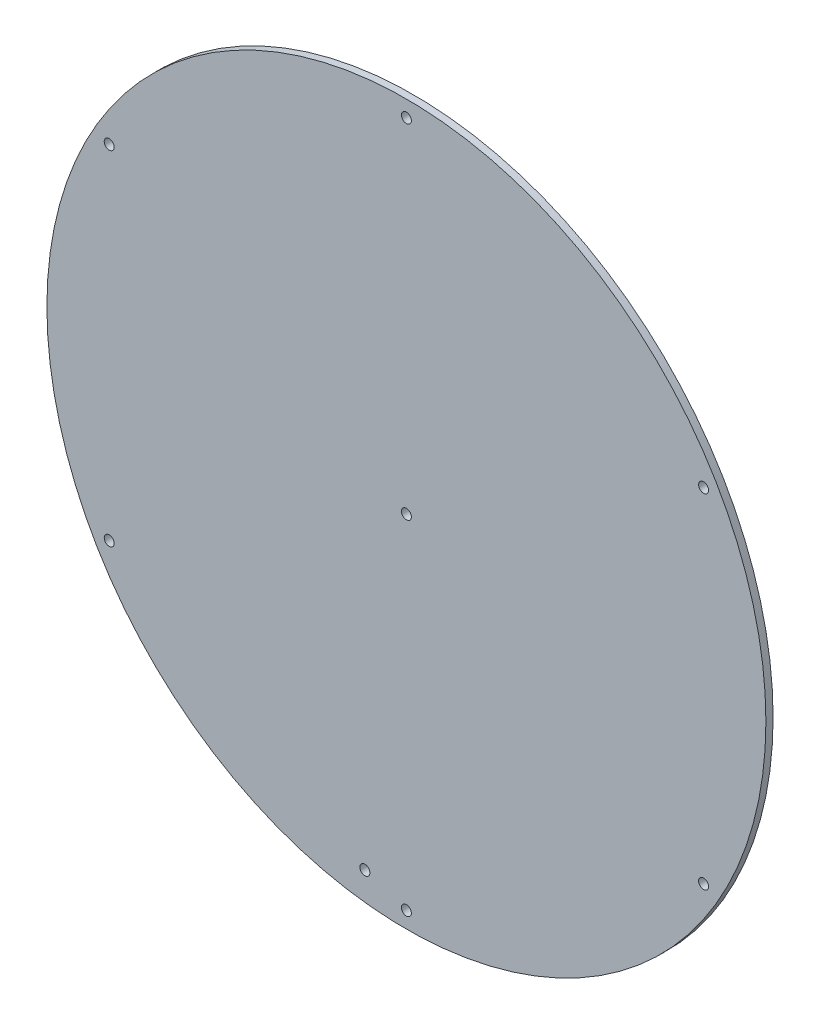
SolidWorks part; units mm, degrees
ref_plane "Front Plane" through (0, 0, 0) normal (0, 0, 1) x (1, 0, 0)
ref_plane "Top Plane" through (0, 0, 0) normal (0, 1, 0) x (1, 0, 0)
ref_plane "Right Plane" through (0, 0, 0) normal (1, 0, 0) x (0, 0, -1)
sketch "Sketch1" plane through (0, 0, 0) normal (0, 0, 1) x (1, 0, 0)
  circle A0 centre (0, 0) radius 110
  dimension "D1" = 220
extrude "Boss-Extrude1" add sketch "Sketch1" along normal blind 2.2
sketch "Sketch2" plane through (0, 0, 2.2) normal (0, 0, 1) x (1, 0, 0)
  line L0 (0, 0) -> (0, 105) construction
  circle A0 centre (0, 105) radius 1.524
  dimension "D1" = 3.048
  dimension "D2" = 105
extrude "Cut-Extrude1" cut sketch "Sketch2" against normal through all
pattern_circular "CirPattern1" count 6 over 360 about axis through (0, 0, 2.2) along (0, 0, 1) of "Cut-Extrude1"
sketch "Sketch3" plane through (0, 0, 0) normal (0, 0, -1) x (-1, 0, 0)
  line L1 (-15.17, 54.936) -> (-6.17, 54.936)
  line L2 (-15.17, 54.936) -> (-15.17, 63.936)
  line L3 (-15.17, 63.936) -> (-6.17, 63.936)
  line L4 (-6.17, 54.936) -> (-6.17, 63.936)
  line L5 (-15.17, 54.936) -> (-6.17, 63.936) construction
  line L6 (-15.17, 63.936) -> (-6.17, 54.936) construction
  line L7 (1.088, 63.936) -> (10.088, 63.936)
  line L8 (1.088, 63.936) -> (1.088, 54.936)
  line L9 (1.088, 54.936) -> (10.088, 54.936)
  line L10 (10.088, 63.936) -> (10.088, 54.936)
  line L11 (1.088, 63.936) -> (10.088, 54.936) construction
  line L12 (1.088, 54.936) -> (10.088, 63.936) construction
  point P0 (-10.67, 59.436)
  point P5 (5.588, 59.436)
  dimension "D1" = 9
  dimension "D2" = 9
  dimension "D3" = 5.588
  dimension "D4" = 10.67
  dimension "D5" = 59.436
extrude "Cut-Extrude2" cut sketch "Sketch3" against normal blind 0.5
sketch "Sketch12" plane through (0, 0, 0) normal (0, 0, -1) x (-1, 0, 0)
  circle A0 centre (-1.6002, -10.668) radius 1 construction
  ellipse E0 centre (-1.6002, -10.668) end of major axis (-1.6002, -8.8601) minor radius 1
  dimension "D3" = 2
  dimension "D1" = 10.668
  dimension "D2" = 1.6002
extrude "Cut-Extrude5" cut sketch "Sketch12" against normal blind 0.2
pattern_linear "LPattern1" count 2 spacing 3 along (-1, 0, 0) count 2 spacing 6.096 along (0, -1, 0) of "Cut-Extrude5"
sketch "Sketch13" plane through (0, 0, 0) normal (0, 0, -1) x (-1, 0, 0)
  circle A0 centre (0, 0) radius 1.524
  circle A1 centre (12.7, -100.6602) radius 1.524
  circle A2 centre (0, -105) radius 1.524 construction
  dimension "D2" = 12.7
  dimension "D1" = 100.6602
extrude "Cut-Extrude6" cut sketch "Sketch13" against normal through all
sketch "Sketch14" plane through (0, 0, 0) normal (0, 0, -1) x (-1, 0, 0)
  line L0 (0, 0) -> (-3.2, -90.805) construction
  circle A0 centre (0, -105) radius 1.524 construction
  ellipse E0 centre (-3.2, -90.805) end of major axis (-4.95, -90.805) minor radius 0.9
  dimension "D1" = 1.8
  dimension "D2" = 3.5
  dimension "D3" = 3.2
  dimension "D4" = 90.805
extrude "Cut-Extrude7" cut sketch "Sketch14" against normal blind 0.2
pattern_linear "LPattern2" count 2 spacing 6.4 along (-1, 0, 0) of "Cut-Extrude7"
sketch "Sketch15" plane through (0, 0, 0) normal (0, 0, -1) x (-1, 0, 0)
  line L0 (11.3989, -96.5924) -> (11.3989, -98.0342) construction
  line L1 (13.0252, -95.1506) -> (14.5843, -95.1506)
  line L2 (13.0252, -95.1506) -> (13.0252, -98.0342)
  line L3 (13.0252, -98.0342) -> (14.5843, -98.0342)
  line L4 (14.5843, -95.1506) -> (14.5843, -98.0342)
  line L5 (13.0252, -95.1506) -> (14.5843, -98.0342) construction
  line L6 (13.0252, -98.0342) -> (14.5843, -95.1506) construction
  ellipse E0 centre (11.3989, -96.5924) end of major axis (11.3989, -95.1506) minor radius 0.8306
  point P0 (13.8048, -96.5924)
extrude "Cut-Extrude8" cut sketch "Sketch15" against normal blind 0.2
sketch "Sketch4" plane through (0, 0, 2.2) normal (0, 0, 1) x (1, 0, 0)
  line L1 (76.2, 76.2) -> (-76.2, 76.2)
  line L2 (76.2, 76.2) -> (76.2, -76.2)
  line L3 (76.2, -76.2) -> (-76.2, -76.2)
  line L4 (-76.2, 76.2) -> (-76.2, -76.2)
  line L5 (76.2, 76.2) -> (-76.2, -76.2) construction
  line L6 (76.2, -76.2) -> (-76.2, 76.2) construction
  point P0 (0, 0)
  dimension "D1" = 152.4
sketch "Sketch6" plane through (0, 0, 2.2) normal (0, 0, 1) x (1, 0, 0)
  circle A0 centre (0, 0) radius 98
  dimension "D1" = 196
sketch "Sketch16" plane through (0, 0, 2.2) normal (0, 0, 1) x (1, 0, 0)
  line L0 (0, 94.0587) -> (-2.5409, 94.0056)
  line L1 (-2.5409, 94.0056) -> (-5.08, 93.9256)
  line L2 (-5.08, 93.9256) -> (-8.2021, 93.7504)
  line L3 (-8.2021, 93.7504) -> (-12.0652, 93.3647)
  line L4 (-12.0652, 93.3647) -> (-16.1796, 92.757)
  line L5 (-16.1796, 92.757) -> (-16.3504, 92.7278)
  line L6 (-16.3504, 92.7278) -> (-20.8022, 91.8576)
  line L7 (-20.8022, 91.8576) -> (-24.3828, 90.998)
  line L8 (-24.3828, 90.998) -> (-28.5489, 89.8063)
  line L9 (-28.5489, 89.8063) -> (-32.2381, 88.5734)
  line L10 (-32.2381, 88.5734) -> (-36.3324, 87.0027)
  line L11 (-36.3324, 87.0027) -> (-39.8561, 85.4717)
  line L12 (-39.8561, 85.4717) -> (-43.7872, 83.556)
  line L13 (-43.7872, 83.556) -> (-47.1787, 81.7159)
  line L14 (-47.1787, 81.7159) -> (-50.9317, 79.4624)
  line L15 (-50.9317, 79.4624) -> (-54.1497, 77.3338)
  line L16 (-54.1497, 77.3338) -> (-57.6923, 74.7617)
  line L17 (-57.6923, 74.7617) -> (-60.7158, 72.3582)
  line L18 (-60.7158, 72.3582) -> (-64.0217, 69.4862)
  line L19 (-64.0217, 69.4862) -> (-66.8264, 66.8264)
  line L20 (-66.8264, 66.8264) -> (-69.8702, 63.6763)
  line L21 (-69.8702, 63.6763) -> (-72.4345, 60.7798)
  line L22 (-72.4345, 60.7798) -> (-75.1929, 57.3755)
  line L23 (-75.1929, 57.3755) -> (-77.4969, 54.2639)
  line L24 (-77.4969, 54.2639) -> (-79.9489, 50.6313)
  line L25 (-79.9489, 50.6313) -> (-81.9746, 47.328)
  line L26 (-81.9746, 47.328) -> (-84.1011, 43.4945)
  line L27 (-84.1011, 43.4945) -> (-85.8326, 40.0244)
  line L28 (-85.8326, 40.0244) -> (-87.6175, 36.0191)
  line L29 (-87.6175, 36.0191) -> (-89.0412, 32.4083)
  line L30 (-89.0412, 32.4083) -> (-90.4705, 28.2616)
  line L31 (-90.4705, 28.2616) -> (-91.575, 24.5374)
  line L32 (-91.575, 24.5374) -> (-92.6378, 20.2808)
  line L33 (-92.6378, 20.2808) -> (-93.4141, 16.4714)
  line L34 (-93.4141, 16.4714) -> (-94.102, 12.1372)
  line L35 (-94.102, 12.1372) -> (-94.5438, 8.2715)
  line L36 (-94.5438, 8.2715) -> (-94.8515, 3.8927)
  line L37 (-94.8515, 3.8927) -> (-94.9547, 0)
  line L38 (-94.9547, 0) -> (-94.8796, -4.3901)
  line L39 (-94.8796, -4.3901) -> (-94.643, -8.2802)
  line L40 (-94.643, -8.2802) -> (-94.1854, -12.6482)
  line L41 (-94.1854, -12.6482) -> (-93.6102, -16.506)
  line L42 (-93.6102, -16.506) -> (-92.7734, -20.8186)
  line L43 (-92.7734, -20.8186) -> (-91.8635, -24.6147)
  line L44 (-91.8635, -24.6147) -> (-90.6537, -28.8391)
  line L45 (-90.6537, -28.8391) -> (-89.4154, -32.5445)
  line L46 (-89.4154, -32.5445) -> (-87.8416, -36.6485)
  line L47 (-87.8416, -36.6485) -> (-86.2838, -40.2348)
  line L48 (-86.2838, -40.2348) -> (-84.3579, -44.187)
  line L49 (-84.3579, -44.187) -> (-82.4919, -47.6267)
  line L50 (-82.4919, -47.6267) -> (-80.2282, -51.397)
  line L51 (-80.2282, -51.397) -> (-78.0678, -54.6636)
  line L52 (-78.0678, -54.6636) -> (-75.4835, -58.2233)
  line L53 (-75.4835, -58.2233) -> (-73.0446, -61.2917)
  line L54 (-73.0446, -61.2917) -> (-70.1592, -64.6134)
  line L55 (-70.1592, -64.6134) -> (-67.4599, -67.4599)
  line L56 (-67.4599, -67.4599) -> (-64.2951, -70.5183)
  line L57 (-64.2951, -70.5183) -> (-61.3557, -73.1209)
  line L58 (-61.3557, -73.1209) -> (-57.9355, -75.8925)
  line L59 (-57.9355, -75.8925) -> (-54.7779, -78.2309)
  line L60 (-54.7779, -78.2309) -> (-51.1282, -80.6946)
  line L61 (-51.1282, -80.6946) -> (-47.776, -82.7505)
  line L62 (-47.776, -82.7505) -> (-43.9245, -84.8873)
  line L63 (-43.9245, -84.8873) -> (-40.4031, -86.6447)
  line L64 (-40.4031, -86.6447) -> (-36.3789, -88.4381)
  line L65 (-36.3789, -88.4381) -> (-32.7148, -89.8831)
  line L66 (-32.7148, -89.8831) -> (-28.5486, -91.3194)
  line L67 (-28.5486, -91.3194) -> (-24.7693, -92.4404)
  line L68 (-24.7693, -92.4404) -> (-20.4927, -93.5084)
  line L69 (-20.4927, -93.5084) -> (-16.627, -94.2965)
  line L70 (-16.627, -94.2965) -> (-12.2724, -94.9879)
  line L71 (-12.2724, -94.9879) -> (-8.3496, -95.4364)
  line L72 (-8.3496, -95.4364) -> (-3.9502, -95.7457)
  line L73 (-3.9502, -95.7457) -> (0, -95.8507)
  line L74 (0, -95.8507) -> (4.4108, -95.7754)
  line L75 (4.4108, -95.7754) -> (8.3583, -95.5356)
  line L76 (8.3583, -95.5356) -> (12.7469, -95.076)
  line L77 (12.7469, -95.076) -> (16.6616, -94.4926)
  line L78 (16.6616, -94.4926) -> (20.9945, -93.6521)
  line L79 (20.9945, -93.6521) -> (24.8466, -92.7289)
  line L80 (24.8466, -92.7289) -> (29.091, -91.5137)
  line L81 (29.091, -91.5137) -> (32.851, -90.2573)
  line L82 (32.851, -90.2573) -> (36.9743, -88.6764)
  line L83 (36.9743, -88.6764) -> (40.6134, -87.0958)
  line L84 (40.6134, -87.0958) -> (44.5843, -85.1611)
  line L85 (44.5843, -85.1611) -> (48.0747, -83.2678)
  line L86 (48.0747, -83.2678) -> (51.8628, -80.9937)
  line L87 (51.8628, -80.9937) -> (55.1776, -78.8017)
  line L88 (55.1776, -78.8017) -> (58.754, -76.2055)
  line L89 (58.754, -76.2055) -> (61.8676, -73.731)
  line L90 (61.8676, -73.731) -> (65.2051, -70.8322)
  line L91 (65.2051, -70.8322) -> (68.0935, -68.0935)
  line L92 (68.0935, -68.0935) -> (71.1664, -64.914)
  line L93 (71.1664, -64.914) -> (73.8072, -61.9316)
  line L94 (73.8072, -61.9316) -> (76.5921, -58.4956)
  line L95 (76.5921, -58.4956) -> (78.9648, -55.2918)
  line L96 (78.9648, -55.2918) -> (81.4402, -51.6251)
  line L97 (81.4402, -51.6251) -> (83.5264, -48.224)
  line L98 (83.5264, -48.224) -> (85.6734, -44.3546)
  line L99 (85.6734, -44.3546) -> (87.4567, -40.7817)
  line L100 (87.4567, -40.7817) -> (89.2588, -36.7389)
  line L101 (89.2588, -36.7389) -> (90.7251, -33.0212)
  line L102 (90.7251, -33.0212) -> (92.1683, -28.8356)
  line L103 (92.1683, -28.8356) -> (93.3059, -25.0012)
  line L104 (93.3059, -25.0012) -> (94.3791, -20.7047)
  line L105 (94.3791, -20.7047) -> (95.1789, -16.7826)
  line L106 (95.1789, -16.7826) -> (95.8737, -12.4077)
  line L107 (95.8737, -12.4077) -> (96.329, -8.4277)
  line L108 (96.329, -8.4277) -> (96.64, -4.0078)
  line L109 (96.64, -4.0078) -> (96.7467, 0)
  line L110 (96.7467, 0) -> (96.6713, 4.4314)
  line L111 (96.6713, 4.4314) -> (96.4281, 8.4364)
  line L112 (96.4281, 8.4364) -> (95.9667, 12.8454)
  line L113 (95.9667, 12.8454) -> (95.3749, 16.8172)
  line L114 (95.3749, 16.8172) -> (94.5308, 21.1704)
  line L115 (94.5308, 21.1704) -> (93.5944, 25.0785)
  line L116 (93.5944, 25.0785) -> (92.3737, 29.3427)
  line L117 (92.3737, 29.3427) -> (91.0993, 33.1574)
  line L118 (91.0993, 33.1574) -> (89.5112, 37.3)
  line L119 (89.5112, 37.3) -> (87.9078, 40.9921)
  line L120 (87.9078, 40.9921) -> (85.9643, 44.9816)
  line L121 (85.9643, 44.9816) -> (84.0437, 48.5227)
  line L122 (84.0437, 48.5227) -> (81.7593, 52.3286)
  line L123 (81.7593, 52.3286) -> (79.5357, 55.6915)
  line L124 (79.5357, 55.6915) -> (76.9276, 59.2847)
  line L125 (76.9276, 59.2847) -> (74.4173, 62.4435)
  line L126 (74.4173, 62.4435) -> (71.5052, 65.7967)
  line L127 (71.5052, 65.7967) -> (68.727, 68.727)
  line L128 (68.727, 68.727) -> (65.533, 71.8144)
  line L129 (65.533, 71.8144) -> (62.5075, 74.4936)
  line L130 (62.5075, 74.4936) -> (59.0556, 77.2916)
  line L131 (59.0556, 77.2916) -> (55.8057, 79.6988)
  line L132 (55.8057, 79.6988) -> (52.1223, 82.1858)
  line L133 (52.1223, 82.1858) -> (48.672, 84.3024)
  line L134 (48.672, 84.3024) -> (44.7841, 86.4599)
  line L135 (44.7841, 86.4599) -> (41.1604, 88.2688)
  line L136 (41.1604, 88.2688) -> (37.1015, 90.0781)
  line L137 (37.1015, 90.0781) -> (33.3277, 91.567)
  line L138 (33.3277, 91.567) -> (29.1125, 93.0211)
  line L139 (29.1125, 93.0211) -> (25.2331, 94.1713)
  line L140 (25.2331, 94.1713) -> (20.9565, 95.2383)
  line L141 (20.9565, 95.2383) -> (16.9382, 96.0612)
  line L142 (16.9382, 96.0612) -> (12.3786, 96.7912)
  line L143 (12.3786, 96.7912) -> (8.5058, 97.2215)
  line L144 (8.5058, 97.2215) -> (4.5614, 97.4769)
  line L145 (4.5614, 97.4769) -> (0, 97.6427)
  line L146 (0, 90.4264) -> (-2.5409, 90.3737)
  line L147 (-2.5409, 90.3737) -> (-5.0799, 90.292)
  line L148 (-5.0799, 90.292) -> (-7.8856, 90.1326)
  line L149 (-7.8856, 90.1326) -> (-11.6733, 89.7538)
  line L150 (-11.6733, 89.7538) -> (-15.7129, 89.1532)
  line L151 (-15.7129, 89.1532) -> (-15.7199, 89.152)
  line L152 (-15.7199, 89.152) -> (-20.0849, 88.2982)
  line L153 (-20.0849, 88.2982) -> (-23.4433, 87.4914)
  line L154 (-23.4433, 87.4914) -> (-27.5281, 86.3223)
  line L155 (-27.5281, 86.3223) -> (-30.9967, 85.1627)
  line L156 (-30.9967, 85.1627) -> (-35.0112, 83.622)
  line L157 (-35.0112, 83.622) -> (-38.3225, 82.1828)
  line L158 (-38.3225, 82.1828) -> (-42.1769, 80.3038)
  line L159 (-42.1769, 80.3038) -> (-45.3646, 78.5737)
  line L160 (-45.3646, 78.5737) -> (-49.0444, 76.3635)
  line L161 (-49.0444, 76.3635) -> (-52.069, 74.3623)
  line L162 (-52.069, 74.3623) -> (-55.5425, 71.8395)
  line L163 (-55.5425, 71.8395) -> (-58.3844, 69.5798)
  line L164 (-58.3844, 69.5798) -> (-61.6259, 66.763)
  line L165 (-61.6259, 66.763) -> (-64.2622, 64.2622)
  line L166 (-64.2622, 64.2622) -> (-67.2466, 61.1728)
  line L167 (-67.2466, 61.1728) -> (-69.6571, 58.4493)
  line L168 (-69.6571, 58.4493) -> (-72.3617, 55.1106)
  line L169 (-72.3617, 55.1106) -> (-74.5276, 52.1848)
  line L170 (-74.5276, 52.1848) -> (-76.9316, 48.6221)
  line L171 (-76.9316, 48.6221) -> (-78.8359, 45.5159)
  line L172 (-78.8359, 45.5159) -> (-80.9208, 41.7562)
  line L173 (-80.9208, 41.7562) -> (-82.5486, 38.493)
  line L174 (-82.5486, 38.493) -> (-84.2984, 34.5649)
  line L175 (-84.2984, 34.5649) -> (-85.6367, 31.1692)
  line L176 (-85.6367, 31.1692) -> (-87.0379, 27.1024)
  line L177 (-87.0379, 27.1024) -> (-88.0762, 23.5999)
  line L178 (-88.0762, 23.5999) -> (-89.1179, 19.4253)
  line L179 (-89.1179, 19.4253) -> (-89.8476, 15.8425)
  line L180 (-89.8476, 15.8425) -> (-90.5217, 11.5918)
  line L181 (-90.5217, 11.5918) -> (-90.9367, 7.9559)
  line L182 (-90.9367, 7.9559) -> (-91.2379, 3.6614)
  line L183 (-91.2379, 3.6614) -> (-91.3345, 0)
  line L184 (-91.3345, 0) -> (-91.2602, -4.3056)
  line L185 (-91.2602, -4.3056) -> (-91.0372, -7.9647)
  line L186 (-91.0372, -7.9647) -> (-90.5878, -12.2486)
  line L187 (-90.5878, -12.2486) -> (-90.0463, -15.8776)
  line L188 (-90.0463, -15.8776) -> (-89.2251, -20.1072)
  line L189 (-89.2251, -20.1072) -> (-88.3685, -23.6783)
  line L190 (-88.3685, -23.6783) -> (-87.1815, -27.8214)
  line L191 (-87.1815, -27.8214) -> (-86.016, -31.3073)
  line L192 (-86.016, -31.3073) -> (-84.4719, -35.3322)
  line L193 (-84.4719, -35.3322) -> (-83.0058, -38.7062)
  line L194 (-83.0058, -38.7062) -> (-81.1163, -42.5824)
  line L195 (-81.1163, -42.5824) -> (-79.3601, -45.8186)
  line L196 (-79.3601, -45.8186) -> (-77.1394, -49.5164)
  line L197 (-77.1394, -49.5164) -> (-75.1061, -52.5899)
  line L198 (-75.1061, -52.5899) -> (-72.5709, -56.081)
  line L199 (-72.5709, -56.081) -> (-70.2755, -58.9681)
  line L200 (-70.2755, -58.9681) -> (-67.4448, -62.2259)
  line L201 (-67.4448, -62.2259) -> (-64.9043, -64.9043)
  line L202 (-64.9043, -64.9043) -> (-61.7997, -67.9038)
  line L203 (-61.7997, -67.9038) -> (-59.033, -70.3527)
  line L204 (-59.033, -70.3527) -> (-55.6778, -73.071)
  line L205 (-55.6778, -73.071) -> (-52.7056, -75.2714)
  line L206 (-52.7056, -75.2714) -> (-49.1253, -77.6876)
  line L207 (-49.1253, -77.6876) -> (-45.9699, -79.6223)
  line L208 (-45.9699, -79.6223) -> (-42.1917, -81.7178)
  line L209 (-42.1917, -81.7178) -> (-38.8768, -83.3716)
  line L210 (-38.8768, -83.3716) -> (-34.9292, -85.1303)
  line L211 (-34.9292, -85.1303) -> (-31.4798, -86.49)
  line L212 (-31.4798, -86.49) -> (-27.3928, -87.8984)
  line L213 (-27.3928, -87.8984) -> (-23.835, -88.9533)
  line L214 (-23.835, -88.9533) -> (-19.6396, -90.0004)
  line L215 (-19.6396, -90.0004) -> (-16.0002, -90.7418)
  line L216 (-16.0002, -90.7418) -> (-11.7284, -91.4195)
  line L217 (-11.7284, -91.4195) -> (-8.0351, -91.8413)
  line L218 (-8.0351, -91.8413) -> (-3.7193, -92.1442)
  line L219 (-3.7193, -92.1442) -> (0, -92.2426)
  line L220 (0, -92.2426) -> (4.3269, -92.1682)
  line L221 (4.3269, -92.1682) -> (8.0439, -91.9418)
  line L222 (8.0439, -91.9418) -> (12.349, -91.4905)
  line L223 (12.349, -91.4905) -> (16.0353, -90.9406)
  line L224 (16.0353, -90.9406) -> (20.2859, -90.1155)
  line L225 (20.2859, -90.1155) -> (23.9133, -89.2457)
  line L226 (23.9133, -89.2457) -> (28.077, -88.053)
  line L227 (28.077, -88.053) -> (31.6178, -86.8693)
  line L228 (31.6178, -86.8693) -> (35.6628, -85.3178)
  line L229 (35.6628, -85.3178) -> (39.09, -83.8288)
  line L230 (39.09, -83.8288) -> (42.9854, -81.9302)
  line L231 (42.9854, -81.9302) -> (46.2726, -80.1466)
  line L232 (46.2726, -80.1466) -> (49.9888, -77.9151)
  line L233 (49.9888, -77.9151) -> (53.1107, -75.85)
  line L234 (53.1107, -75.85) -> (56.6192, -73.3024)
  line L235 (56.6192, -73.3024) -> (59.5518, -70.9711)
  line L236 (59.5518, -70.9711) -> (62.8258, -68.1267)
  line L237 (62.8258, -68.1267) -> (65.5464, -65.5464)
  line L238 (65.5464, -65.5464) -> (68.5609, -62.4266)
  line L239 (68.5609, -62.4266) -> (71.0484, -59.6167)
  line L240 (71.0484, -59.6167) -> (73.7802, -56.2451)
  line L241 (73.7802, -56.2451) -> (76.0153, -53.2265)
  line L242 (76.0153, -53.2265) -> (78.4436, -49.6287)
  line L243 (78.4436, -49.6287) -> (80.4087, -46.424)
  line L244 (80.4087, -46.424) -> (82.5147, -42.6272)
  line L245 (82.5147, -42.6272) -> (84.1946, -39.2606)
  line L246 (84.1946, -39.2606) -> (85.9622, -35.2936)
  line L247 (85.9622, -35.2936) -> (87.3434, -31.7904)
  line L248 (87.3434, -31.7904) -> (88.7589, -27.6834)
  line L249 (88.7589, -27.6834) -> (89.8304, -24.07)
  line L250 (89.8304, -24.07) -> (90.8829, -19.8541)
  line L251 (90.8829, -19.8541) -> (91.6361, -16.1579)
  line L252 (91.6361, -16.1579) -> (92.3174, -11.8652)
  line L253 (92.3174, -11.8652) -> (92.7459, -8.1142)
  line L254 (92.7459, -8.1142) -> (93.0506, -3.7772)
  line L255 (93.0506, -3.7772) -> (93.1507, 0)
  line L256 (93.1507, 0) -> (93.0761, 4.3482)
  line L257 (93.0761, 4.3482) -> (92.8465, 8.123)
  line L258 (92.8465, 8.123) -> (92.3931, 12.4493)
  line L259 (92.3931, 12.4493) -> (91.8349, 16.193)
  line L260 (91.8349, 16.193) -> (91.006, 20.4645)
  line L261 (91.006, 20.4645) -> (90.1228, 24.1483)
  line L262 (90.1228, 24.1483) -> (88.9245, 28.3325)
  line L263 (88.9245, 28.3325) -> (87.7226, 31.9284)
  line L264 (87.7226, 31.9284) -> (86.1638, 35.9933)
  line L265 (86.1638, 35.9933) -> (84.6518, 39.4738)
  line L266 (84.6518, 39.4738) -> (82.7441, 43.3884)
  line L267 (82.7441, 43.3884) -> (80.933, 46.7267)
  line L268 (80.933, 46.7267) -> (78.6908, 50.4612)
  line L269 (78.6908, 50.4612) -> (76.5938, 53.6316)
  line L270 (76.5938, 53.6316) -> (74.034, 57.1574)
  line L271 (74.034, 57.1574) -> (71.6667, 60.1355)
  line L272 (71.6667, 60.1355) -> (68.8085, 63.4257)
  line L273 (68.8085, 63.4257) -> (66.1885, 66.1885)
  line L274 (66.1885, 66.1885) -> (63.0536, 69.2179)
  line L275 (63.0536, 69.2179) -> (60.2004, 71.744)
  line L276 (60.2004, 71.744) -> (56.8124, 74.4894)
  line L277 (56.8124, 74.4894) -> (53.7473, 76.7591)
  line L278 (53.7473, 76.7591) -> (50.1322, 79.1993)
  line L279 (50.1322, 79.1993) -> (46.878, 81.1951)
  line L280 (46.878, 81.1951) -> (43.0622, 83.312)
  line L281 (43.0622, 83.312) -> (39.6443, 85.0176)
  line L282 (39.6443, 85.0176) -> (35.6606, 86.7928)
  line L283 (35.6606, 86.7928) -> (32.101, 88.1967)
  line L284 (32.101, 88.1967) -> (27.9639, 89.6232)
  line L285 (27.9639, 89.6232) -> (24.305, 90.7076)
  line L286 (24.305, 90.7076) -> (20.1076, 91.7542)
  line L287 (20.1076, 91.7542) -> (16.3156, 92.5304)
  line L288 (16.3156, 92.5304) -> (11.8405, 93.2461)
  line L289 (11.8405, 93.2461) -> (8.1934, 93.6506)
  line L290 (8.1934, 93.6506) -> (4.3221, 93.9011)
  line L291 (4.3221, 93.9011) -> (0, 94.0587)
  line L292 (0, 86.7457) -> (-2.5409, 86.6935)
  line L293 (-2.5409, 86.6935) -> (-5.0797, 86.6098)
  line L294 (-5.0797, 86.6098) -> (-7.5648, 86.4665)
  line L295 (-7.5648, 86.4665) -> (-11.2747, 86.095)
  line L296 (-11.2747, 86.095) -> (-15.081, 85.5285)
  line L297 (-15.081, 85.5285) -> (-19.3562, 84.6917)
  line L298 (-19.3562, 84.6917) -> (-22.4911, 83.9381)
  line L299 (-22.4911, 83.9381) -> (-26.492, 82.7924)
  line L300 (-26.492, 82.7924) -> (-29.7387, 81.7065)
  line L301 (-29.7387, 81.7065) -> (-33.6707, 80.1968)
  line L302 (-33.6707, 80.1968) -> (-36.7683, 78.85)
  line L303 (-36.7683, 78.85) -> (-40.5435, 77.0089)
  line L304 (-40.5435, 77.0089) -> (-43.5262, 75.3896)
  line L305 (-43.5262, 75.3896) -> (-47.1304, 73.2241)
  line L306 (-47.1304, 73.2241) -> (-49.9606, 71.3511)
  line L307 (-49.9606, 71.3511) -> (-53.3626, 68.8795)
  line L308 (-53.3626, 68.8795) -> (-56.022, 66.7644)
  line L309 (-56.022, 66.7644) -> (-59.1968, 64.0047)
  line L310 (-59.1968, 64.0047) -> (-61.6638, 61.6638)
  line L311 (-61.6638, 61.6638) -> (-64.5869, 58.6371)
  line L312 (-64.5869, 58.6371) -> (-66.8427, 56.0877)
  line L313 (-66.8427, 56.0877) -> (-69.4916, 52.8168)
  line L314 (-69.4916, 52.8168) -> (-71.5186, 50.0778)
  line L315 (-71.5186, 50.0778) -> (-73.8731, 46.5875)
  line L316 (-73.8731, 46.5875) -> (-75.6553, 43.6796)
  line L317 (-75.6553, 43.6796) -> (-77.6972, 39.9963)
  line L318 (-77.6972, 39.9963) -> (-79.2206, 36.9412)
  line L319 (-79.2206, 36.9412) -> (-80.9343, 33.0928)
  line L320 (-80.9343, 33.0928) -> (-82.1868, 29.9136)
  line L321 (-82.1868, 29.9136) -> (-83.559, 25.9293)
  line L322 (-83.559, 25.9293) -> (-84.5306, 22.6499)
  line L323 (-84.5306, 22.6499) -> (-85.5506, 18.56)
  line L324 (-85.5506, 18.56) -> (-86.2334, 15.2053)
  line L325 (-86.2334, 15.2053) -> (-86.8932, 11.0408)
  line L326 (-86.8932, 11.0408) -> (-87.2814, 7.6361)
  line L327 (-87.2814, 7.6361) -> (-87.5759, 3.4288)
  line L328 (-87.5759, 3.4288) -> (-87.6659, 0)
  line L329 (-87.6659, 0) -> (-87.5926, -4.2182)
  line L330 (-87.5926, -4.2182) -> (-87.3832, -7.645)
  line L331 (-87.3832, -7.645) -> (-86.9424, -11.842)
  line L332 (-86.9424, -11.842) -> (-86.4347, -15.2408)
  line L333 (-86.4347, -15.2408) -> (-85.6296, -19.3846)
  line L334 (-85.6296, -19.3846) -> (-84.8269, -22.7293)
  line L335 (-84.8269, -22.7293) -> (-83.6633, -26.7883)
  line L336 (-83.6633, -26.7883) -> (-82.5711, -30.0534)
  line L337 (-82.5711, -30.0534) -> (-81.0578, -33.9968)
  line L338 (-81.0578, -33.9968) -> (-79.6839, -37.1572)
  line L339 (-79.6839, -37.1572) -> (-77.8322, -40.9548)
  line L340 (-77.8322, -40.9548) -> (-76.1865, -43.9863)
  line L341 (-76.1865, -43.9863) -> (-74.0102, -47.6091)
  line L342 (-74.0102, -47.6091) -> (-72.1048, -50.4883)
  line L343 (-72.1048, -50.4883) -> (-69.6203, -53.9086)
  line L344 (-69.6203, -53.9086) -> (-67.4693, -56.6134)
  line L345 (-67.4693, -56.6134) -> (-64.6953, -59.8051)
  line L346 (-64.6953, -59.8051) -> (-62.3145, -62.3145)
  line L347 (-62.3145, -62.3145) -> (-59.272, -65.2531)
  line L348 (-59.272, -65.2531) -> (-56.6791, -67.5476)
  line L349 (-56.6791, -67.5476) -> (-53.3912, -70.2106)
  line L350 (-53.3912, -70.2106) -> (-50.6056, -72.2723)
  line L351 (-50.6056, -72.2723) -> (-47.0971, -74.6394)
  line L352 (-47.0971, -74.6394) -> (-44.1397, -76.4522)
  line L353 (-44.1397, -76.4522) -> (-40.4371, -78.505)
  line L354 (-40.4371, -78.505) -> (-37.3301, -80.0546)
  line L355 (-37.3301, -80.0546) -> (-33.4616, -81.7775)
  line L356 (-33.4616, -81.7775) -> (-30.2283, -83.0515)
  line L357 (-30.2283, -83.0515) -> (-26.2232, -84.4311)
  line L358 (-26.2232, -84.4311) -> (-22.8881, -85.4194)
  line L359 (-22.8881, -85.4194) -> (-18.7768, -86.445)
  line L360 (-18.7768, -86.445) -> (-15.3651, -87.1396)
  line L361 (-15.3651, -87.1396) -> (-11.1788, -87.8031)
  line L362 (-11.1788, -87.8031) -> (-7.7163, -88.198)
  line L363 (-7.7163, -88.198) -> (-3.487, -88.4943)
  line L364 (-3.487, -88.4943) -> (0, -88.5861)
  line L365 (0, -88.5861) -> (4.2403, -88.5126)
  line L366 (4.2403, -88.5126) -> (7.7252, -88.2999)
  line L367 (7.7252, -88.2999) -> (11.9442, -87.857)
  line L368 (11.9442, -87.857) -> (15.4006, -87.3409)
  line L369 (15.4006, -87.3409) -> (19.5661, -86.5318)
  line L370 (19.5661, -86.5318) -> (22.9675, -85.7157)
  line L371 (22.9675, -85.7157) -> (27.0478, -84.5463)
  line L372 (27.0478, -84.5463) -> (30.3682, -83.4358)
  line L373 (30.3682, -83.4358) -> (34.3322, -81.9148)
  line L374 (34.3322, -81.9148) -> (37.5461, -80.5179)
  line L375 (37.5461, -80.5179) -> (41.3636, -78.6567)
  line L376 (41.3636, -78.6567) -> (44.4464, -76.9834)
  line L377 (44.4464, -76.9834) -> (48.0882, -74.7959)
  line L378 (48.0882, -74.7959) -> (51.0161, -72.8586)
  line L379 (51.0161, -72.8586) -> (54.4544, -70.3613)
  line L380 (54.4544, -70.3613) -> (57.2049, -68.1742)
  line L381 (57.2049, -68.1742) -> (60.4134, -65.3859)
  line L382 (60.4134, -65.3859) -> (62.9651, -62.9651)
  line L383 (62.9651, -62.9651) -> (65.9192, -59.907)
  line L384 (65.9192, -59.907) -> (68.2525, -57.2706)
  line L385 (68.2525, -57.2706) -> (70.9296, -53.9657)
  line L386 (70.9296, -53.9657) -> (73.0261, -51.1334)
  line L387 (73.0261, -51.1334) -> (75.4057, -47.6068)
  line L388 (75.4057, -47.6068) -> (77.249, -44.5998)
  line L389 (77.249, -44.5998) -> (79.3128, -40.8781)
  line L390 (79.3128, -40.8781) -> (80.8885, -37.719)
  line L391 (80.8885, -37.719) -> (82.6206, -33.8305)
  line L392 (82.6206, -33.8305) -> (83.9162, -30.543)
  line L393 (83.9162, -30.543) -> (85.3032, -26.5172)
  line L394 (85.3032, -26.5172) -> (86.3083, -23.1262)
  line L395 (86.3083, -23.1262) -> (87.3394, -18.9937)
  line L396 (87.3394, -18.9937) -> (88.0458, -15.5248)
  line L397 (88.0458, -15.5248) -> (88.713, -11.3169)
  line L398 (88.713, -11.3169) -> (89.1147, -7.7965)
  line L399 (89.1147, -7.7965) -> (89.4128, -3.5453)
  line L400 (89.4128, -3.5453) -> (89.5062, 0)
  line L401 (89.5062, 0) -> (89.4326, 4.2623)
  line L402 (89.4326, 4.2623) -> (89.2166, 7.8054)
  line L403 (89.2166, 7.8054) -> (88.7716, 12.0463)
  line L404 (88.7716, 12.0463) -> (88.2471, 15.5604)
  line L405 (88.2471, 15.5604) -> (87.4341, 19.7475)
  line L406 (87.4341, 19.7475) -> (86.6045, 23.2056)
  line L407 (86.6045, 23.2056) -> (85.4293, 27.3071)
  line L408 (85.4293, 27.3071) -> (84.3005, 30.6829)
  line L409 (84.3005, 30.6829) -> (82.7718, 34.6675)
  line L410 (82.7718, 34.6675) -> (81.3519, 37.935)
  line L411 (81.3519, 37.935) -> (79.4812, 41.7723)
  line L412 (79.4812, 41.7723) -> (77.7803, 44.9065)
  line L413 (77.7803, 44.9065) -> (75.5817, 48.5672)
  line L414 (75.5817, 48.5672) -> (73.6124, 51.5439)
  line L415 (73.6124, 51.5439) -> (71.1024, 55.0001)
  line L416 (71.1024, 55.0001) -> (68.879, 57.7964)
  line L417 (68.879, 57.7964) -> (66.0766, 61.0216)
  line L418 (66.0766, 61.0216) -> (63.6158, 63.6158)
  line L419 (63.6158, 63.6158) -> (60.5421, 66.5853)
  line L420 (60.5421, 66.5853) -> (57.8621, 68.9574)
  line L421 (57.8621, 68.9574) -> (54.5403, 71.6485)
  line L422 (54.5403, 71.6485) -> (51.6612, 73.7799)
  line L423 (51.6612, 73.7799) -> (48.1167, 76.1718)
  line L424 (48.1167, 76.1718) -> (45.0598, 78.0459)
  line L425 (45.0598, 78.0459) -> (41.3185, 80.1209)
  line L426 (41.3185, 80.1209) -> (38.1078, 81.7225)
  line L427 (38.1078, 81.7225) -> (34.2019, 83.4625)
  line L428 (34.2019, 83.4625) -> (30.8577, 84.7809)
  line L429 (30.8577, 84.7809) -> (26.8014, 86.179)
  line L430 (26.8014, 86.179) -> (23.3644, 87.1971)
  line L431 (23.3644, 87.1971) -> (19.2489, 88.2228)
  line L432 (19.2489, 88.2228) -> (15.6846, 88.952)
  line L433 (15.6846, 88.952) -> (13.495, 89.33)
  line L434 (13.495, 89.33) -> (9.2978, 89.8933)
  line L435 (9.2978, 89.8933) -> (7.8767, 90.0314)
  line L436 (7.8767, 90.0314) -> (4.0809, 90.277)
  line L437 (4.0809, 90.277) -> (0, 90.4264)
  line L438 (0, 83.0166) -> (-2.5408, 82.965)
  line L439 (-2.5408, 82.965) -> (-5.0796, 82.8788)
  line L440 (-5.0796, 82.8788) -> (-7.2399, 82.7523)
  line L441 (-7.2399, 82.7523) -> (-10.8691, 82.3883)
  line L442 (-10.8691, 82.3883) -> (-14.4337, 81.8574)
  line L443 (-14.4337, 81.8574) -> (-18.616, 81.0381)
  line L444 (-18.616, 81.0381) -> (-21.5265, 80.338)
  line L445 (-21.5265, 80.338) -> (-25.4405, 79.2167)
  line L446 (-25.4405, 79.2167) -> (-28.4642, 78.2048)
  line L447 (-28.4642, 78.2048) -> (-32.3108, 76.7273)
  line L448 (-32.3108, 76.7273) -> (-35.1938, 75.4733)
  line L449 (-35.1938, 75.4733) -> (-38.887, 73.6716)
  line L450 (-38.887, 73.6716) -> (-41.6637, 72.1636)
  line L451 (-41.6637, 72.1636) -> (-45.1896, 70.0445)
  line L452 (-45.1896, 70.0445) -> (-47.8243, 68.3002)
  line L453 (-47.8243, 68.3002) -> (-51.1525, 65.8816)
  line L454 (-51.1525, 65.8816) -> (-53.6284, 63.9118)
  line L455 (-53.6284, 63.9118) -> (-56.7343, 61.2114)
  line L456 (-56.7343, 61.2114) -> (-59.0312, 59.0312)
  line L457 (-59.0312, 59.0312) -> (-61.8908, 56.0695)
  line L458 (-61.8908, 56.0695) -> (-63.9912, 53.695)
  line L459 (-63.9912, 53.695) -> (-66.5826, 50.4943)
  line L460 (-66.5826, 50.4943) -> (-68.4699, 47.9432)
  line L461 (-68.4699, 47.9432) -> (-70.7732, 44.5278)
  line L462 (-70.7732, 44.5278) -> (-72.4328, 41.8191)
  line L463 (-72.4328, 41.8191) -> (-74.4302, 38.2148)
  line L464 (-74.4302, 38.2148) -> (-75.8488, 35.3689)
  line L465 (-75.8488, 35.3689) -> (-77.5251, 31.6031)
  line L466 (-77.5251, 31.6031) -> (-78.6915, 28.6414)
  line L467 (-78.6915, 28.6414) -> (-80.0336, 24.7426)
  line L468 (-80.0336, 24.7426) -> (-80.9383, 21.6874)
  line L469 (-80.9383, 21.6874) -> (-81.9358, 17.6852)
  line L470 (-81.9358, 17.6852) -> (-82.5715, 14.5596)
  line L471 (-82.5715, 14.5596) -> (-83.2166, 10.4845)
  line L472 (-83.2166, 10.4845) -> (-83.5779, 7.3121)
  line L473 (-83.5779, 7.3121) -> (-83.8655, 3.195)
  line L474 (-83.8655, 3.195) -> (-83.9489, 0)
  line L475 (-83.9489, 0) -> (-83.8766, -4.1278)
  line L476 (-83.8766, -4.1278) -> (-83.681, -7.3211)
  line L477 (-83.681, -7.3211) -> (-83.2491, -11.4282)
  line L478 (-83.2491, -11.4282) -> (-82.7755, -14.5956)
  line L479 (-82.7755, -14.5956) -> (-81.9871, -18.6506)
  line L480 (-81.9871, -18.6506) -> (-81.2385, -21.7678)
  line L481 (-81.2385, -21.7678) -> (-80.0993, -25.7399)
  line L482 (-80.0993, -25.7399) -> (-79.0808, -28.7831)
  line L483 (-79.0808, -28.7831) -> (-77.5993, -32.6419)
  line L484 (-77.5993, -32.6419) -> (-76.3182, -35.5878)
  line L485 (-76.3182, -35.5878) -> (-74.5055, -39.304)
  line L486 (-74.5055, -39.304) -> (-72.971, -42.1298)
  line L487 (-72.971, -42.1298) -> (-70.8406, -45.675)
  line L488 (-70.8406, -45.675) -> (-69.0639, -48.3591)
  line L489 (-69.0639, -48.3591) -> (-66.6319, -51.7061)
  line L490 (-66.6319, -51.7061) -> (-64.626, -54.2277)
  line L491 (-64.626, -54.2277) -> (-61.9107, -57.351)
  line L492 (-61.9107, -57.351) -> (-59.6904, -59.6904)
  line L493 (-59.6904, -59.6904) -> (-56.7124, -62.5661)
  line L494 (-56.7124, -62.5661) -> (-54.2942, -64.7053)
  line L495 (-54.2942, -64.7053) -> (-51.0759, -67.3113)
  line L496 (-51.0759, -67.3113) -> (-48.4779, -69.2336)
  line L497 (-48.4779, -69.2336) -> (-45.0436, -71.5499)
  line L498 (-45.0436, -71.5499) -> (-42.2852, -73.2401)
  line L499 (-42.2852, -73.2401) -> (-38.661, -75.2489)
  line L500 (-38.661, -75.2489) -> (-35.7629, -76.6938)
  line L501 (-35.7629, -76.6938) -> (-31.9763, -78.3796)
  line L502 (-31.9763, -78.3796) -> (-28.9602, -79.5675)
  line L503 (-28.9602, -79.5675) -> (-25.0399, -80.9173)
  line L504 (-25.0399, -80.9173) -> (-21.9286, -81.8388)
  line L505 (-21.9286, -81.8388) -> (-17.9044, -82.8421)
  line L506 (-17.9044, -82.8421) -> (-14.7215, -83.4896)
  line L507 (-14.7215, -83.4896) -> (-10.6238, -84.1386)
  line L508 (-10.6238, -84.1386) -> (-7.3934, -84.5066)
  line L509 (-7.3934, -84.5066) -> (-3.2535, -84.796)
  line L510 (-3.2535, -84.796) -> (0, -84.8812)
  line L511 (0, -84.8812) -> (4.1506, -84.8087)
  line L512 (4.1506, -84.8087) -> (7.4024, -84.6098)
  line L513 (7.4024, -84.6098) -> (11.5322, -84.1757)
  line L514 (11.5322, -84.1757) -> (14.7574, -83.6937)
  line L515 (14.7574, -83.6937) -> (18.8349, -82.901)
  line L516 (18.8349, -82.901) -> (22.0091, -82.139)
  line L517 (22.0091, -82.139) -> (26.0032, -80.9937)
  line L518 (26.0032, -80.9937) -> (29.1019, -79.9569)
  line L519 (29.1019, -79.9569) -> (32.9822, -78.4674)
  line L520 (32.9822, -78.4674) -> (35.9818, -77.1632)
  line L521 (35.9818, -77.1632) -> (39.7186, -75.3406)
  line L522 (39.7186, -75.3406) -> (42.596, -73.7784)
  line L523 (42.596, -73.7784) -> (46.1608, -71.6364)
  line L524 (46.1608, -71.6364) -> (48.8938, -69.8276)
  line L525 (48.8938, -69.8276) -> (52.2594, -67.3823)
  line L526 (52.2594, -67.3823) -> (54.8269, -65.3402)
  line L527 (54.8269, -65.3402) -> (57.9676, -62.6101)
  line L528 (57.9676, -62.6101) -> (60.3497, -60.3497)
  line L529 (60.3497, -60.3497) -> (63.2413, -57.3553)
  line L530 (63.2413, -57.3553) -> (65.4195, -54.8935)
  line L531 (65.4195, -54.8935) -> (68.04, -51.6576)
  line L532 (68.04, -51.6576) -> (69.9973, -49.0126)
  line L533 (69.9973, -49.0126) -> (72.3265, -45.5596)
  line L534 (72.3265, -45.5596) -> (74.0475, -42.7513)
  line L535 (74.0475, -42.7513) -> (76.0675, -39.1073)
  line L536 (76.0675, -39.1073) -> (77.5387, -36.1569)
  line L537 (77.5387, -36.1569) -> (79.234, -32.3495)
  line L538 (79.234, -32.3495) -> (80.4436, -29.2791)
  line L539 (80.4436, -29.2791) -> (81.801, -25.3373)
  line L540 (81.801, -25.3373) -> (82.7393, -22.1699)
  line L541 (82.7393, -22.1699) -> (83.7484, -18.1236)
  line L542 (83.7484, -18.1236) -> (84.4077, -14.8834)
  line L543 (84.4077, -14.8834) -> (85.0605, -10.7633)
  line L544 (85.0605, -10.7633) -> (85.4353, -7.4746)
  line L545 (85.4353, -7.4746) -> (85.7266, -3.312)
  line L546 (85.7266, -3.312) -> (85.8134, 0)
  line L547 (85.8134, 0) -> (85.7408, 4.1734)
  line L548 (85.7408, 4.1734) -> (85.5385, 7.4836)
  line L549 (85.5385, 7.4836) -> (85.1023, 11.6361)
  line L550 (85.1023, 11.6361) -> (84.6118, 14.9193)
  line L551 (84.6118, 14.9193) -> (83.8151, 19.0192)
  line L552 (83.8151, 19.0192) -> (83.0395, 22.2504)
  line L553 (83.0395, 22.2504) -> (81.8882, 26.2664)
  line L554 (81.8882, 26.2664) -> (80.8329, 29.4208)
  line L555 (80.8329, 29.4208) -> (79.3355, 33.3223)
  line L556 (79.3355, 33.3223) -> (78.0081, 36.3758)
  line L557 (78.0081, 36.3758) -> (76.1758, 40.1331)
  line L558 (76.1758, 40.1331) -> (74.5857, 43.0621)
  line L559 (74.5857, 43.0621) -> (72.4323, 46.6465)
  line L560 (72.4323, 46.6465) -> (70.5912, 49.4285)
  line L561 (70.5912, 49.4285) -> (68.1329, 52.8127)
  line L562 (68.1329, 52.8127) -> (66.0543, 55.4262)
  line L563 (66.0543, 55.4262) -> (63.3095, 58.5841)
  line L564 (63.3095, 58.5841) -> (61.0089, 61.0089)
  line L565 (61.0089, 61.0089) -> (57.9984, 63.9165)
  line L566 (57.9984, 63.9165) -> (55.4927, 66.1337)
  line L567 (55.4927, 66.1337) -> (52.2393, 68.7687)
  line L568 (52.2393, 68.7687) -> (49.5473, 70.7609)
  line L569 (49.5473, 70.7609) -> (46.0758, 73.1029)
  line L570 (46.0758, 73.1029) -> (43.2175, 74.8549)
  line L571 (43.2175, 74.8549) -> (39.5532, 76.8864)
  line L572 (39.5532, 76.8864) -> (36.5509, 78.3836)
  line L573 (36.5509, 78.3836) -> (32.7254, 80.0872)
  line L574 (32.7254, 80.0872) -> (29.5979, 81.3196)
  line L575 (29.5979, 81.3196) -> (25.6251, 82.6883)
  line L576 (25.6251, 82.6883) -> (22.4112, 83.6398)
  line L577 (22.4112, 83.6398) -> (18.3805, 84.6439)
  line L578 (18.3805, 84.6439) -> (15.0452, 85.3258)
  line L579 (15.0452, 85.3258) -> (12.9008, 85.6964)
  line L580 (12.9008, 85.6964) -> (8.7936, 86.2444)
  line L581 (8.7936, 86.2444) -> (7.5559, 86.364)
  line L582 (7.5559, 86.364) -> (3.8382, 86.6045)
  line L583 (3.8382, 86.6045) -> (0, 86.7457)
  line L584 (0, 79.2392) -> (-2.5408, 79.1881)
  line L585 (-2.5408, 79.1881) -> (-5.0793, 79.0991)
  line L586 (-5.0793, 79.0991) -> (-6.9107, 78.9899)
  line L587 (-6.9107, 78.9899) -> (-10.4564, 78.6337)
  line L588 (-10.4564, 78.6337) -> (-13.778, 78.1387)
  line L589 (-13.778, 78.1387) -> (-17.864, 77.3376)
  line L590 (-17.864, 77.3376) -> (-20.5493, 76.6912)
  line L591 (-20.5493, 76.6912) -> (-24.3733, 75.5951)
  line L592 (-24.3733, 75.5951) -> (-27.1732, 74.6577)
  line L593 (-27.1732, 74.6577) -> (-30.9313, 73.2136)
  line L594 (-30.9313, 73.2136) -> (-33.5988, 72.0528)
  line L595 (-33.5988, 72.0528) -> (-37.207, 70.2919)
  line L596 (-37.207, 70.2919) -> (-39.777, 68.8957)
  line L597 (-39.777, 68.8957) -> (-43.2218, 66.8247)
  line L598 (-43.2218, 66.8247) -> (-45.6604, 65.2098)
  line L599 (-45.6604, 65.2098) -> (-48.912, 62.8461)
  line L600 (-48.912, 62.8461) -> (-51.2037, 61.0222)
  line L601 (-51.2037, 61.0222) -> (-54.2382, 58.3831)
  line L602 (-54.2382, 58.3831) -> (-56.3644, 56.3644)
  line L603 (-56.3644, 56.3644) -> (-59.1582, 53.47)
  line L604 (-59.1582, 53.47) -> (-61.1026, 51.2712)
  line L605 (-61.1026, 51.2712) -> (-63.6344, 48.1432)
  line L606 (-63.6344, 48.1432) -> (-65.3817, 45.7807)
  line L607 (-65.3817, 45.7807) -> (-67.6319, 42.4429)
  line L608 (-67.6319, 42.4429) -> (-69.1684, 39.9344)
  line L609 (-69.1684, 39.9344) -> (-71.1198, 36.412)
  line L610 (-71.1198, 36.412) -> (-72.4332, 33.7762)
  line L611 (-72.4332, 33.7762) -> (-74.0708, 30.0959)
  line L612 (-74.0708, 30.0959) -> (-75.1507, 27.3526)
  line L613 (-75.1507, 27.3526) -> (-76.4617, 23.5424)
  line L614 (-76.4617, 23.5424) -> (-77.2993, 20.7123)
  line L615 (-77.2993, 20.7123) -> (-78.2736, 16.801)
  line L616 (-78.2736, 16.801) -> (-78.862, 13.9055)
  line L617 (-78.862, 13.9055) -> (-79.4919, 9.9229)
  line L618 (-79.4919, 9.9229) -> (-79.8261, 6.9839)
  line L619 (-79.8261, 6.9839) -> (-80.1066, 2.9602)
  line L620 (-80.1066, 2.9602) -> (-80.1835, 0)
  line L621 (-80.1835, 0) -> (-80.1123, -4.0341)
  line L622 (-80.1123, -4.0341) -> (-79.9307, -6.993)
  line L623 (-79.9307, -6.993) -> (-79.508, -11.0069)
  line L624 (-79.508, -11.0069) -> (-79.0687, -13.9419)
  line L625 (-79.0687, -13.9419) -> (-78.2975, -17.905)
  line L626 (-78.2975, -17.905) -> (-77.6034, -20.7938)
  line L627 (-77.6034, -20.7938) -> (-76.4894, -24.6758)
  line L628 (-76.4894, -24.6758) -> (-75.5451, -27.4962)
  line L629 (-75.5451, -27.4962) -> (-74.0965, -31.2675)
  line L630 (-74.0965, -31.2675) -> (-72.9087, -33.9979)
  line L631 (-72.9087, -33.9979) -> (-71.1364, -37.6299)
  line L632 (-71.1364, -37.6299) -> (-69.7136, -40.2492)
  line L633 (-69.7136, -40.2492) -> (-67.6308, -43.714)
  line L634 (-67.6308, -43.714) -> (-65.9833, -46.202)
  line L635 (-65.9833, -46.202) -> (-63.6057, -49.4732)
  line L636 (-63.6057, -49.4732) -> (-61.7457, -51.8108)
  line L637 (-61.7457, -51.8108) -> (-59.0912, -54.8633)
  line L638 (-59.0912, -54.8633) -> (-57.0322, -57.0322)
  line L639 (-57.0322, -57.0322) -> (-54.1208, -59.8427)
  line L640 (-54.1208, -59.8427) -> (-51.8782, -61.8261)
  line L641 (-51.8782, -61.8261) -> (-48.7319, -64.3729)
  line L642 (-48.7319, -64.3729) -> (-46.3224, -66.1553)
  line L643 (-46.3224, -66.1553) -> (-42.965, -68.419)
  line L644 (-42.965, -68.419) -> (-40.4066, -69.9862)
  line L645 (-40.4066, -69.9862) -> (-36.8635, -71.9493)
  line L646 (-36.8635, -71.9493) -> (-34.1753, -73.2891)
  line L647 (-34.1753, -73.2891) -> (-30.4734, -74.9365)
  line L648 (-30.4734, -74.9365) -> (-27.6756, -76.0381)
  line L649 (-27.6756, -76.0381) -> (-23.843, -77.357)
  line L650 (-23.843, -77.357) -> (-20.9567, -78.2115)
  line L651 (-20.9567, -78.2115) -> (-17.0225, -79.1917)
  line L652 (-17.0225, -79.1917) -> (-14.0695, -79.7921)
  line L653 (-14.0695, -79.7921) -> (-10.0635, -80.4259)
  line L654 (-10.0635, -80.4259) -> (-7.0662, -80.7669)
  line L655 (-7.0662, -80.7669) -> (-3.0189, -81.0493)
  line L656 (-3.0189, -81.0493) -> (0, -81.1279)
  line L657 (0, -81.1279) -> (4.0578, -81.0565)
  line L658 (4.0578, -81.0565) -> (7.0753, -80.8715)
  line L659 (7.0753, -80.8715) -> (11.1128, -80.4465)
  line L660 (11.1128, -80.4465) -> (14.1059, -79.9987)
  line L661 (14.1059, -79.9987) -> (18.0923, -79.2233)
  line L662 (18.0923, -79.2233) -> (21.0382, -78.5156)
  line L663 (21.0382, -78.5156) -> (24.943, -77.3953)
  line L664 (24.943, -77.3953) -> (27.8192, -76.4325)
  line L665 (27.8192, -76.4325) -> (31.6127, -74.9757)
  line L666 (31.6127, -74.9757) -> (34.397, -73.7646)
  line L667 (34.397, -73.7646) -> (38.0503, -71.9821)
  line L668 (38.0503, -71.9821) -> (40.7213, -70.5314)
  line L669 (40.7213, -70.5314) -> (44.2066, -68.4367)
  line L670 (44.2066, -68.4367) -> (46.7437, -66.7569)
  line L671 (46.7437, -66.7569) -> (50.0342, -64.3656)
  line L672 (50.0342, -64.3656) -> (52.4178, -62.4691)
  line L673 (52.4178, -62.4691) -> (55.4883, -59.7993)
  line L674 (55.4883, -59.7993) -> (57.7, -57.7)
  line L675 (57.7, -57.7) -> (60.527, -54.7718)
  line L676 (60.527, -54.7718) -> (62.5495, -52.4852)
  line L677 (62.5495, -52.4852) -> (65.1114, -49.3208)
  line L678 (65.1114, -49.3208) -> (66.9288, -46.8641)
  line L679 (66.9288, -46.8641) -> (69.2059, -43.4873)
  line L680 (69.2059, -43.4873) -> (70.8041, -40.8787)
  line L681 (70.8041, -40.8787) -> (72.7788, -37.3152)
  line L682 (72.7788, -37.3152) -> (74.145, -34.5744)
  line L683 (74.145, -34.5744) -> (75.8022, -30.8511)
  line L684 (75.8022, -30.8511) -> (76.9255, -27.9986)
  line L685 (76.9255, -27.9986) -> (78.2524, -24.1438)
  line L686 (78.2524, -24.1438) -> (79.1237, -21.2011)
  line L687 (79.1237, -21.2011) -> (80.1099, -17.2441)
  line L688 (80.1099, -17.2441) -> (80.7221, -14.2335)
  line L689 (80.7221, -14.2335) -> (81.3598, -10.2043)
  line L690 (81.3598, -10.2043) -> (81.7077, -7.1485)
  line L691 (81.7077, -7.1485) -> (81.992, -3.0777)
  line L692 (81.992, -3.0777) -> (82.0723, 0)
  line L693 (82.0723, 0) -> (82.0006, 4.0814)
  line L694 (82.0006, 4.0814) -> (81.8122, 7.1576)
  line L695 (81.8122, 7.1576) -> (81.385, 11.2185)
  line L696 (81.385, 11.2185) -> (80.9287, 14.2699)
  line L697 (80.9287, 14.2699) -> (80.149, 18.2794)
  line L698 (80.149, 18.2794) -> (79.4278, 21.2826)
  line L699 (79.4278, 21.2826) -> (78.3012, 25.2101)
  line L700 (78.3012, 25.2101) -> (77.3199, 28.1421)
  line L701 (77.3199, 28.1421) -> (75.8549, 31.9578)
  line L702 (75.8549, 31.9578) -> (74.6205, 34.7961)
  line L703 (74.6205, 34.7961) -> (72.8279, 38.4707)
  line L704 (72.8279, 38.4707) -> (71.3493, 41.1935)
  line L705 (71.3493, 41.1935) -> (69.2426, 44.699)
  line L706 (69.2426, 44.699) -> (67.5305, 47.2854)
  line L707 (67.5305, 47.2854) -> (65.1256, 50.595)
  line L708 (65.1256, 50.595) -> (63.1925, 53.0248)
  line L709 (63.1925, 53.0248) -> (60.5075, 56.1132)
  line L710 (60.5075, 56.1132) -> (58.3677, 58.3677)
  line L711 (58.3677, 58.3677) -> (55.4228, 61.2113)
  line L712 (55.4228, 61.2113) -> (53.0923, 63.2729)
  line L713 (53.0923, 63.2729) -> (49.9097, 65.8498)
  line L714 (49.9097, 65.8498) -> (47.4057, 67.7024)
  line L715 (47.4057, 67.7024) -> (44.0097, 69.9927)
  line L716 (44.0097, 69.9927) -> (41.3509, 71.6219)
  line L717 (41.3509, 71.6219) -> (37.7664, 73.6086)
  line L718 (37.7664, 73.6086) -> (34.9735, 75.0009)
  line L719 (34.9735, 75.0009) -> (31.2312, 76.6667)
  line L720 (31.2312, 76.6667) -> (28.3216, 77.8129)
  line L721 (28.3216, 77.8129) -> (24.4352, 79.1512)
  line L722 (24.4352, 79.1512) -> (21.4455, 80.0359)
  line L723 (21.4455, 80.0359) -> (17.5025, 81.0176)
  line L724 (17.5025, 81.0176) -> (14.3975, 81.6521)
  line L725 (14.3975, 81.6521) -> (12.2997, 82.0148)
  line L726 (12.2997, 82.0148) -> (8.2858, 82.5471)
  line L727 (8.2858, 82.5471) -> (7.2308, 82.6485)
  line L728 (7.2308, 82.6485) -> (3.5939, 82.8837)
  line L729 (3.5939, 82.8837) -> (0, 83.0166)
  line L730 (0, 75.4133) -> (-2.5408, 75.3628)
  line L731 (-2.5408, 75.3628) -> (-5.0791, 75.2705)
  line L732 (-5.0791, 75.2705) -> (-6.5773, 75.1793)
  line L733 (-6.5773, 75.1793) -> (-10.0364, 74.8312)
  line L734 (-10.0364, 74.8312) -> (-13.1138, 74.3723)
  line L735 (-13.1138, 74.3723) -> (-17.1, 73.5902)
  line L736 (-17.1, 73.5902) -> (-19.5597, 72.9977)
  line L737 (-19.5597, 72.9977) -> (-23.2902, 71.9277)
  line L738 (-23.2902, 71.9277) -> (-25.8656, 71.0651)
  line L739 (-25.8656, 71.0651) -> (-29.5319, 69.6556)
  line L740 (-29.5319, 69.6556) -> (-31.9833, 68.5885)
  line L741 (-31.9833, 68.5885) -> (-35.5035, 66.8699)
  line L742 (-35.5035, 66.8699) -> (-37.8661, 65.586)
  line L743 (-37.8661, 65.586) -> (-41.2268, 63.5648)
  line L744 (-41.2268, 63.5648) -> (-43.4687, 62.0797)
  line L745 (-43.4687, 62.0797) -> (-46.641, 59.7729)
  line L746 (-46.641, 59.7729) -> (-48.748, 58.0956)
  line L747 (-48.748, 58.0956) -> (-51.7084, 55.5201)
  line L748 (-51.7084, 55.5201) -> (-53.6634, 53.6634)
  line L749 (-53.6634, 53.6634) -> (-56.389, 50.8388)
  line L750 (-56.389, 50.8388) -> (-58.177, 48.8163)
  line L751 (-58.177, 48.8163) -> (-60.6469, 45.7638)
  line L752 (-60.6469, 45.7638) -> (-62.2538, 43.5906)
  line L753 (-62.2538, 43.5906) -> (-64.449, 40.3333)
  line L754 (-64.449, 40.3333) -> (-65.8621, 38.0255)
  line L755 (-65.8621, 38.0255) -> (-67.7658, 34.5881)
  line L756 (-67.7658, 34.5881) -> (-68.9737, 32.163)
  line L757 (-68.9737, 32.163) -> (-70.5712, 28.5715)
  line L758 (-70.5712, 28.5715) -> (-71.5644, 26.0473)
  line L759 (-71.5644, 26.0473) -> (-72.8432, 22.329)
  line L760 (-72.8432, 22.329) -> (-73.6136, 19.7247)
  line L761 (-73.6136, 19.7247) -> (-74.5638, 15.9077)
  line L762 (-74.5638, 15.9077) -> (-75.1049, 13.243)
  line L763 (-75.1049, 13.243) -> (-75.719, 9.3564)
  line L764 (-75.719, 9.3564) -> (-76.0262, 6.6514)
  line L765 (-76.0262, 6.6514) -> (-76.2994, 2.7247)
  line L766 (-76.2994, 2.7247) -> (-76.3698, 0)
  line L767 (-76.3698, 0) -> (-76.2997, -3.937)
  line L768 (-76.2997, -3.937) -> (-76.1321, -6.6607)
  line L769 (-76.1321, -6.6607) -> (-75.719, -10.5779)
  line L770 (-75.719, -10.5779) -> (-75.3142, -13.2799)
  line L771 (-75.3142, -13.2799) -> (-74.561, -17.1476)
  line L772 (-74.561, -17.1476) -> (-73.9215, -19.8072)
  line L773 (-73.9215, -19.8072) -> (-72.8337, -23.5958)
  line L774 (-72.8337, -23.5958) -> (-71.9639, -26.1927)
  line L775 (-71.9639, -26.1927) -> (-70.5495, -29.8734)
  line L776 (-70.5495, -29.8734) -> (-69.4553, -32.3875)
  line L777 (-69.4553, -32.3875) -> (-67.725, -35.9322)
  line L778 (-67.725, -35.9322) -> (-66.4143, -38.3443)
  line L779 (-66.4143, -38.3443) -> (-64.3809, -41.7258)
  line L780 (-64.3809, -41.7258) -> (-62.8632, -44.0173)
  line L781 (-62.8632, -44.0173) -> (-60.542, -47.2098)
  line L782 (-60.542, -47.2098) -> (-58.8283, -49.3628)
  line L783 (-58.8283, -49.3628) -> (-56.2368, -52.3419)
  line L784 (-56.2368, -52.3419) -> (-54.3398, -54.3398)
  line L785 (-54.3398, -54.3398) -> (-51.4975, -57.0827)
  line L786 (-51.4975, -57.0827) -> (-49.4311, -58.9097)
  line L787 (-49.4311, -58.9097) -> (-46.3596, -61.3953)
  line L788 (-46.3596, -61.3953) -> (-44.1392, -63.0373)
  line L789 (-44.1392, -63.0373) -> (-40.8616, -65.2465)
  line L790 (-40.8616, -65.2465) -> (-38.5037, -66.6904)
  line L791 (-38.5037, -66.6904) -> (-35.0449, -68.6062)
  line L792 (-35.0449, -68.6062) -> (-32.5672, -69.8406)
  line L793 (-32.5672, -69.8406) -> (-28.9533, -71.4483)
  line L794 (-28.9533, -71.4483) -> (-26.3744, -72.4632)
  line L795 (-26.3744, -72.4632) -> (-22.6329, -73.7502)
  line L796 (-22.6329, -73.7502) -> (-19.9722, -74.5374)
  line L797 (-19.9722, -74.5374) -> (-16.1314, -75.4938)
  line L798 (-16.1314, -75.4938) -> (-13.4091, -76.0468)
  line L799 (-13.4091, -76.0468) -> (-9.4982, -76.665)
  line L800 (-9.4982, -76.665) -> (-6.7348, -76.9791)
  line L801 (-6.7348, -76.9791) -> (-2.7836, -77.2542)
  line L802 (-2.7836, -77.2542) -> (0, -77.3262)
  line L803 (0, -77.3262) -> (3.9615, -77.2559)
  line L804 (3.9615, -77.2559) -> (6.7441, -77.0849)
  line L805 (6.7441, -77.0849) -> (10.6858, -76.6695)
  line L806 (10.6858, -76.6695) -> (13.446, -76.2561)
  line L807 (13.446, -76.2561) -> (17.3378, -75.4985)
  line L808 (17.3378, -75.4985) -> (20.0548, -74.8454)
  line L809 (20.0548, -74.8454) -> (23.8671, -73.7511)
  line L810 (23.8671, -73.7511) -> (26.5198, -72.8626)
  line L811 (26.5198, -72.8626) -> (30.2235, -71.4397)
  line L812 (30.2235, -71.4397) -> (32.7918, -70.3222)
  line L813 (32.7918, -70.3222) -> (36.3586, -68.5813)
  line L814 (36.3586, -68.5813) -> (38.8225, -67.2426)
  line L815 (38.8225, -67.2426) -> (42.2252, -65.1968)
  line L816 (42.2252, -65.1968) -> (44.5659, -63.6466)
  line L817 (44.5659, -63.6466) -> (47.7784, -61.3113)
  line L818 (47.7784, -61.3113) -> (49.9776, -59.561)
  line L819 (49.9776, -59.561) -> (52.9754, -56.9536)
  line L820 (52.9754, -56.9536) -> (55.0161, -55.0161)
  line L821 (55.0161, -55.0161) -> (57.7762, -52.1564)
  line L822 (57.7762, -52.1564) -> (59.6424, -50.0459)
  line L823 (59.6424, -50.0459) -> (62.1436, -46.9555)
  line L824 (62.1436, -46.9555) -> (63.8208, -44.6878)
  line L825 (63.8208, -44.6878) -> (66.0439, -41.39)
  line L826 (66.0439, -41.39) -> (67.5187, -38.9819)
  line L827 (67.5187, -38.9819) -> (69.4466, -35.5018)
  line L828 (69.4466, -35.5018) -> (70.7074, -32.9714)
  line L829 (70.7074, -32.9714) -> (72.3253, -29.3353)
  line L830 (72.3253, -29.3353) -> (73.362, -26.7016)
  line L831 (73.362, -26.7016) -> (74.6572, -22.937)
  line L832 (74.6572, -22.937) -> (75.4613, -20.2198)
  line L833 (75.4613, -20.2198) -> (76.4238, -16.3553)
  line L834 (76.4238, -16.3553) -> (76.9888, -13.5752)
  line L835 (76.9888, -13.5752) -> (77.611, -9.6402)
  line L836 (77.611, -9.6402) -> (77.9319, -6.8182)
  line L837 (77.9319, -6.8182) -> (78.2089, -2.8425)
  line L838 (78.2089, -2.8425) -> (78.2827, 0)
  line L839 (78.2827, 0) -> (78.2122, 3.986)
  line L840 (78.2122, 3.986) -> (78.0378, 6.8274)
  line L841 (78.0378, 6.8274) -> (77.62, 10.7934)
  line L842 (77.62, 10.7934) -> (77.1981, 13.6121)
  line L843 (77.1981, 13.6121) -> (76.436, 17.5279)
  line L844 (76.436, 17.5279) -> (75.7693, 20.3023)
  line L845 (75.7693, 20.3023) -> (74.6684, 24.1381)
  line L846 (74.6684, 24.1381) -> (73.7614, 26.847)
  line L847 (73.7614, 26.847) -> (72.33, 30.5735)
  line L848 (72.33, 30.5735) -> (71.189, 33.196)
  line L849 (71.189, 33.196) -> (69.4377, 36.7848)
  line L850 (69.4377, 36.7848) -> (68.0709, 39.3008)
  line L851 (68.0709, 39.3008) -> (66.0128, 42.7245)
  line L852 (66.0128, 42.7245) -> (64.4301, 45.1145)
  line L853 (64.4301, 45.1145) -> (62.0806, 48.3469)
  line L854 (62.0806, 48.3469) -> (60.2937, 50.5924)
  line L855 (60.2937, 50.5924) -> (57.6705, 53.6087)
  line L856 (57.6705, 53.6087) -> (55.6924, 55.6924)
  line L857 (55.6924, 55.6924) -> (52.8154, 58.4696)
  line L858 (52.8154, 58.4696) -> (50.6607, 60.3751)
  line L859 (50.6607, 60.3751) -> (47.5515, 62.8918)
  line L860 (47.5515, 62.8918) -> (45.2364, 64.6042)
  line L861 (45.2364, 64.6042) -> (41.9187, 66.8411)
  line L862 (41.9187, 66.8411) -> (39.4602, 68.347)
  line L863 (39.4602, 68.347) -> (35.9583, 70.2873)
  line L864 (35.9583, 70.2873) -> (33.3756, 71.5743)
  line L865 (33.3756, 71.5743) -> (29.7197, 73.2011)
  line L866 (29.7197, 73.2011) -> (27.0287, 74.2607)
  line L867 (27.0287, 74.2607) -> (23.2319, 75.5676)
  line L868 (23.2319, 75.5676) -> (20.4673, 76.3852)
  line L869 (20.4673, 76.3852) -> (16.6151, 77.3437)
  line L870 (16.6151, 77.3437) -> (13.7413, 77.9307)
  line L871 (13.7413, 77.9307) -> (11.6919, 78.2853)
  line L872 (11.6919, 78.2853) -> (7.7746, 78.8014)
  line L873 (7.7746, 78.8014) -> (6.9015, 78.8847)
  line L874 (6.9015, 78.8847) -> (3.3484, 79.1145)
  line L875 (3.3484, 79.1145) -> (0, 79.2392)
  line L876 (0, 71.5391) -> (-2.5408, 71.4892)
  line L877 (-2.5408, 71.4892) -> (-5.0788, 71.3928)
  line L878 (-5.0788, 71.3928) -> (-6.2397, 71.3205)
  line L879 (-6.2397, 71.3205) -> (-9.6088, 70.9809)
  line L880 (-9.6088, 70.9809) -> (-12.4413, 70.5582)
  line L881 (-12.4413, 70.5582) -> (-16.3238, 69.7959)
  line L882 (-16.3238, 69.7959) -> (-18.5575, 69.2574)
  line L883 (-18.5575, 69.2574) -> (-22.191, 68.2147)
  line L884 (-22.191, 68.2147) -> (-24.5414, 67.427)
  line L885 (-24.5414, 67.427) -> (-28.1125, 66.0536)
  line L886 (-28.1125, 66.0536) -> (-30.3474, 65.0803)
  line L887 (-30.3474, 65.0803) -> (-33.7761, 63.4058)
  line L888 (-33.7761, 63.4058) -> (-35.931, 62.2343)
  line L889 (-35.931, 62.2343) -> (-39.2044, 60.2649)
  line L890 (-39.2044, 60.2649) -> (-41.2492, 58.9099)
  line L891 (-41.2492, 58.9099) -> (-44.3391, 56.6624)
  line L892 (-44.3391, 56.6624) -> (-46.2611, 55.1319)
  line L893 (-46.2611, 55.1319) -> (-49.1447, 52.6226)
  line L894 (-49.1447, 52.6226) -> (-50.9282, 50.9282)
  line L895 (-50.9282, 50.9282) -> (-53.583, 48.1762)
  line L896 (-53.583, 48.1762) -> (-55.2143, 46.3303)
  line L897 (-55.2143, 46.3303) -> (-57.6201, 43.3562)
  line L898 (-57.6201, 43.3562) -> (-59.0863, 41.3726)
  line L899 (-59.0863, 41.3726) -> (-61.2245, 38.199)
  line L900 (-61.2245, 38.199) -> (-62.5139, 36.0924)
  line L901 (-62.5139, 36.0924) -> (-64.368, 32.7433)
  line L902 (-64.368, 32.7433) -> (-65.4704, 30.5294)
  line L903 (-65.4704, 30.5294) -> (-67.0262, 27.0301)
  line L904 (-67.0262, 27.0301) -> (-67.9327, 24.7255)
  line L905 (-67.9327, 24.7255) -> (-69.178, 21.1025)
  line L906 (-69.178, 21.1025) -> (-69.8811, 18.7246)
  line L907 (-69.8811, 18.7246) -> (-70.8063, 15.0055)
  line L908 (-70.8063, 15.0055) -> (-71.3001, 12.5721)
  line L909 (-71.3001, 12.5721) -> (-71.8979, 8.7852)
  line L910 (-71.8979, 8.7852) -> (-72.1781, 6.3148)
  line L911 (-72.1781, 6.3148) -> (-72.4437, 2.4887)
  line L912 (-72.4437, 2.4887) -> (-72.5077, 0)
  line L913 (-72.5077, 0) -> (-72.4388, -3.8361)
  line L914 (-72.4388, -3.8361) -> (-72.2853, -6.3241)
  line L915 (-72.2853, -6.3241) -> (-71.8822, -10.141)
  line L916 (-71.8822, -10.141) -> (-71.5121, -12.6095)
  line L917 (-71.5121, -12.6095) -> (-70.7776, -16.3781)
  line L918 (-70.7776, -16.3781) -> (-70.1929, -18.8081)
  line L919 (-70.1929, -18.8081) -> (-69.1324, -22.4998)
  line L920 (-69.1324, -22.4998) -> (-68.3372, -24.8727)
  line L921 (-68.3372, -24.8727) -> (-66.9584, -28.4592)
  line L922 (-66.9584, -28.4592) -> (-65.9581, -30.7568)
  line L923 (-65.9581, -30.7568) -> (-64.2714, -34.2107)
  line L924 (-64.2714, -34.2107) -> (-63.0731, -36.4153)
  line L925 (-63.0731, -36.4153) -> (-61.091, -39.7103)
  line L926 (-61.091, -39.7103) -> (-59.7033, -41.8047)
  line L927 (-59.7033, -41.8047) -> (-57.4408, -44.9157)
  line L928 (-57.4408, -44.9157) -> (-55.8738, -46.8837)
  line L929 (-55.8738, -46.8837) -> (-53.3479, -49.7867)
  line L930 (-53.3479, -49.7867) -> (-51.6131, -51.6131)
  line L931 (-51.6131, -51.6131) -> (-48.8427, -54.2859)
  line L932 (-48.8427, -54.2859) -> (-46.9529, -55.9563)
  line L933 (-46.9529, -55.9563) -> (-43.959, -58.3783)
  line L934 (-43.959, -58.3783) -> (-41.9282, -59.8796)
  line L935 (-41.9282, -59.8796) -> (-38.7335, -62.0324)
  line L936 (-38.7335, -62.0324) -> (-36.5767, -63.3527)
  line L937 (-36.5767, -63.3527) -> (-33.2053, -65.2194)
  line L938 (-33.2053, -65.2194) -> (-30.9387, -66.3482)
  line L939 (-30.9387, -66.3482) -> (-27.4161, -67.9147)
  line L940 (-27.4161, -67.9147) -> (-25.0567, -68.8428)
  line L941 (-25.0567, -68.8428) -> (-21.4097, -70.0967)
  line L942 (-21.4097, -70.0967) -> (-18.9753, -70.8166)
  line L943 (-18.9753, -70.8166) -> (-15.2314, -71.7483)
  line L944 (-15.2314, -71.7483) -> (-12.7403, -72.254)
  line L945 (-12.7403, -72.254) -> (-8.9282, -72.856)
  line L946 (-8.9282, -72.856) -> (-6.3992, -73.143)
  line L947 (-6.3992, -73.143) -> (-2.5476, -73.4106)
  line L948 (-2.5476, -73.4106) -> (0, -73.4762)
  line L949 (0, -73.4762) -> (3.8616, -73.4071)
  line L950 (3.8616, -73.4071) -> (6.4086, -73.2502)
  line L951 (6.4086, -73.2502) -> (10.2509, -72.8447)
  line L952 (10.2509, -72.8447) -> (12.7777, -72.4659)
  line L953 (12.7777, -72.4659) -> (16.5714, -71.7268)
  line L954 (16.5714, -71.7268) -> (19.0588, -71.1285)
  line L955 (19.0588, -71.1285) -> (22.7751, -70.0612)
  line L956 (22.7751, -70.0612) -> (25.204, -69.2473)
  line L957 (25.204, -69.2473) -> (28.8144, -67.8596)
  line L958 (28.8144, -67.8596) -> (31.1661, -66.8359)
  line L959 (31.1661, -66.8359) -> (34.6431, -65.1382)
  line L960 (34.6431, -65.1382) -> (36.8995, -63.9119)
  line L961 (36.8995, -63.9119) -> (40.2166, -61.9169)
  line L962 (40.2166, -61.9169) -> (42.3603, -60.4967)
  line L963 (42.3603, -60.4967) -> (45.4919, -58.2194)
  line L964 (45.4919, -58.2194) -> (47.5063, -56.6158)
  line L965 (47.5063, -56.6158) -> (50.4287, -54.0733)
  line L966 (50.4287, -54.0733) -> (52.298, -52.298)
  line L967 (52.298, -52.298) -> (54.9886, -49.5095)
  line L968 (54.9886, -49.5095) -> (56.6982, -47.5755)
  line L969 (56.6982, -47.5755) -> (59.1365, -44.562)
  line L970 (59.1365, -44.562) -> (60.673, -42.4837)
  line L971 (60.673, -42.4837) -> (62.8402, -39.268)
  line L972 (62.8402, -39.268) -> (64.1915, -37.061)
  line L973 (64.1915, -37.061) -> (66.0708, -33.6674)
  line L974 (66.0708, -33.6674) -> (67.226, -31.348)
  line L975 (67.226, -31.348) -> (68.803, -27.8023)
  line L976 (68.803, -27.8023) -> (69.7529, -25.388)
  line L977 (69.7529, -25.388) -> (71.0154, -21.717)
  line L978 (71.0154, -21.717) -> (71.7522, -19.2259)
  line L979 (71.7522, -19.2259) -> (72.6902, -15.4575)
  line L980 (72.6902, -15.4575) -> (73.2078, -12.9085)
  line L981 (73.2078, -12.9085) -> (73.814, -9.0713)
  line L982 (73.814, -9.0713) -> (74.1079, -6.4836)
  line L983 (74.1079, -6.4836) -> (74.3775, -2.6067)
  line L984 (74.3775, -2.6067) -> (74.4448, 0)
  line L985 (74.4448, 0) -> (74.3755, 3.887)
  line L986 (74.3755, 3.887) -> (74.2151, 6.493)
  line L987 (74.2151, 6.493) -> (73.8071, 10.3606)
  line L988 (73.8071, 10.3606) -> (73.4198, 12.9459)
  line L989 (73.4198, 12.9459) -> (72.676, 16.7646)
  line L990 (72.676, 16.7646) -> (72.0641, 19.3095)
  line L991 (72.0641, 19.3095) -> (70.9899, 23.0502)
  line L992 (70.9899, 23.0502) -> (70.1575, 25.5352)
  line L993 (70.1575, 25.5352) -> (68.7609, 29.1694)
  line L994 (68.7609, 29.1694) -> (67.7137, 31.5754)
  line L995 (67.7137, 31.5754) -> (66.0051, 35.0753)
  line L996 (66.0051, 35.0753) -> (64.7507, 37.3838)
  line L997 (64.7507, 37.3838) -> (62.7429, 40.7227)
  line L998 (62.7429, 40.7227) -> (61.2901, 42.9158)
  line L999 (61.2901, 42.9158) -> (58.9981, 46.0681)
  line L1000 (58.9981, 46.0681) -> (57.3578, 48.1289)
  line L1001 (57.3578, 48.1289) -> (54.7989, 51.0705)
  line L1002 (54.7989, 51.0705) -> (52.9828, 52.9828)
  line L1003 (52.9828, 52.9828) -> (50.1763, 55.6912)
  line L1004 (50.1763, 55.6912) -> (48.1981, 57.4402)
  line L1005 (48.1981, 57.4402) -> (45.165, 59.8946)
  line L1006 (45.165, 59.8946) -> (43.0393, 61.4664)
  line L1007 (43.0393, 61.4664) -> (39.8029, 63.6478)
  line L1008 (39.8029, 63.6478) -> (37.5452, 65.0303)
  line L1009 (37.5452, 65.0303) -> (34.1291, 66.9224)
  line L1010 (34.1291, 66.9224) -> (31.7573, 68.1038)
  line L1011 (31.7573, 68.1038) -> (28.1909, 69.6902)
  line L1012 (28.1909, 69.6902) -> (25.7193, 70.6631)
  line L1013 (25.7193, 70.6631) -> (22.0154, 71.9373)
  line L1014 (22.0154, 71.9373) -> (19.4766, 72.6878)
  line L1015 (19.4766, 72.6878) -> (15.7187, 73.6223)
  line L1016 (15.7187, 73.6223) -> (13.0767, 74.1616)
  line L1017 (13.0767, 74.1616) -> (11.0776, 74.5079)
  line L1018 (11.0776, 74.5079) -> (7.2604, 75.0071)
  line L1019 (7.2604, 75.0071) -> (6.568, 75.0728)
  line L1020 (6.568, 75.0728) -> (3.1018, 75.297)
  line L1021 (3.1018, 75.297) -> (0, 75.4133)
  line L1022 (0, 67.6165) -> (-2.5408, 67.5672)
  line L1023 (-2.5408, 67.5672) -> (-5.8979, 67.4135)
  line L1024 (-5.8979, 67.4135) -> (-9.1734, 67.0828)
  line L1025 (-9.1734, 67.0828) -> (-11.7604, 66.6966)
  line L1026 (-11.7604, 66.6966) -> (-15.535, 65.9548)
  line L1027 (-15.535, 65.9548) -> (-17.5427, 65.4704)
  line L1028 (-17.5427, 65.4704) -> (-21.0753, 64.4561)
  line L1029 (-21.0753, 64.4561) -> (-23.2007, 63.7435)
  line L1030 (-23.2007, 63.7435) -> (-26.6726, 62.4076)
  line L1031 (-26.6726, 62.4076) -> (-28.6911, 61.5282)
  line L1032 (-28.6911, 61.5282) -> (-32.0246, 59.8996)
  line L1033 (-32.0246, 59.8996) -> (-33.9717, 58.8407)
  line L1034 (-33.9717, 58.8407) -> (-37.1543, 56.9253)
  line L1035 (-37.1543, 56.9253) -> (-39.002, 55.7006)
  line L1036 (-39.002, 55.7006) -> (-42.0062, 53.5147)
  line L1037 (-42.0062, 53.5147) -> (-43.7432, 52.1311)
  line L1038 (-43.7432, 52.1311) -> (-46.5467, 49.6907)
  line L1039 (-46.5467, 49.6907) -> (-48.1588, 48.1588)
  line L1040 (-48.1588, 48.1588) -> (-50.74, 45.4822)
  line L1041 (-50.74, 45.4822) -> (-52.2146, 43.8132)
  line L1042 (-52.2146, 43.8132) -> (-54.5536, 40.9208)
  line L1043 (-54.5536, 40.9208) -> (-55.8791, 39.127)
  line L1044 (-55.8791, 39.127) -> (-57.958, 36.0404)
  line L1045 (-57.958, 36.0404) -> (-59.1238, 34.1351)
  line L1046 (-59.1238, 34.1351) -> (-60.9265, 30.8778)
  line L1047 (-60.9265, 30.8778) -> (-61.9232, 28.8753)
  line L1048 (-61.9232, 28.8753) -> (-63.4358, 25.4719)
  line L1049 (-63.4358, 25.4719) -> (-64.2555, 23.3871)
  line L1050 (-64.2555, 23.3871) -> (-65.4661, 19.8634)
  line L1051 (-65.4661, 19.8634) -> (-66.1019, 17.7119)
  line L1052 (-66.1019, 17.7119) -> (-67.0012, 14.0948)
  line L1053 (-67.0012, 14.0948) -> (-67.4477, 11.8928)
  line L1054 (-67.4477, 11.8928) -> (-68.0286, 8.2096)
  line L1055 (-68.0286, 8.2096) -> (-68.2818, 5.9739)
  line L1056 (-68.2818, 5.9739) -> (-68.5396, 2.2525)
  line L1057 (-68.5396, 2.2525) -> (-68.5971, 0)
  line L1058 (-68.5971, 0) -> (-68.5296, -3.7312)
  line L1059 (-68.5296, -3.7312) -> (-68.3904, -5.9834)
  line L1060 (-68.3904, -5.9834) -> (-67.9978, -9.6959)
  line L1061 (-67.9978, -9.6959) -> (-67.6623, -11.9307)
  line L1062 (-67.6623, -11.9307) -> (-66.9473, -15.5963)
  line L1063 (-66.9473, -15.5963) -> (-66.4176, -17.7965)
  line L1064 (-66.4176, -17.7965) -> (-65.3855, -21.3874)
  line L1065 (-65.3855, -21.3874) -> (-64.665, -23.5361)
  line L1066 (-64.665, -23.5361) -> (-63.3233, -27.0247)
  line L1067 (-63.3233, -27.0247) -> (-62.417, -29.1055)
  line L1068 (-62.417, -29.1055) -> (-60.7757, -32.4652)
  line L1069 (-60.7757, -32.4652) -> (-59.69, -34.462)
  line L1070 (-59.69, -34.462) -> (-57.7614, -37.6672)
  line L1071 (-57.7614, -37.6672) -> (-56.5039, -39.5644)
  line L1072 (-56.5039, -39.5644) -> (-54.3024, -42.5905)
  line L1073 (-54.3024, -42.5905) -> (-52.8823, -44.3736)
  line L1074 (-52.8823, -44.3736) -> (-50.4246, -47.1974)
  line L1075 (-50.4246, -47.1974) -> (-48.8522, -48.8522)
  line L1076 (-48.8522, -48.8522) -> (-46.1566, -51.4521)
  line L1077 (-46.1566, -51.4521) -> (-44.4436, -52.9658)
  line L1078 (-44.4436, -52.9658) -> (-41.5305, -55.3218)
  line L1079 (-41.5305, -55.3218) -> (-39.6894, -56.6824)
  line L1080 (-39.6894, -56.6824) -> (-36.5809, -58.7764)
  line L1081 (-36.5809, -58.7764) -> (-34.6255, -59.973)
  line L1082 (-34.6255, -59.973) -> (-31.345, -61.7889)
  line L1083 (-31.345, -61.7889) -> (-29.2897, -62.812)
  line L1084 (-29.2897, -62.812) -> (-25.8621, -64.3356)
  line L1085 (-25.8621, -64.3356) -> (-23.7225, -65.177)
  line L1086 (-23.7225, -65.177) -> (-20.1737, -66.3965)
  line L1087 (-20.1737, -66.3965) -> (-17.9658, -67.0491)
  line L1088 (-17.9658, -67.0491) -> (-14.3228, -67.9551)
  line L1089 (-14.3228, -67.9551) -> (-12.0631, -68.4134)
  line L1090 (-12.0631, -68.4134) -> (-8.3536, -68.9987)
  line L1091 (-8.3536, -68.9987) -> (-6.0594, -69.2588)
  line L1092 (-6.0594, -69.2588) -> (-2.3115, -69.5186)
  line L1093 (-2.3115, -69.5186) -> (0, -69.5778)
  line L1094 (0, -69.5778) -> (3.7577, -69.51)
  line L1095 (3.7577, -69.51) -> (6.0689, -69.3673)
  line L1096 (6.0689, -69.3673) -> (9.8079, -68.9721)
  line L1097 (9.8079, -68.9721) -> (12.101, -68.6281)
  line L1098 (12.101, -68.6281) -> (15.7928, -67.9082)
  line L1099 (15.7928, -67.9082) -> (18.0504, -67.3649)
  line L1100 (18.0504, -67.3649) -> (21.6668, -66.3256)
  line L1101 (21.6668, -66.3256) -> (23.8715, -65.5865)
  line L1102 (23.8715, -65.5865) -> (27.385, -64.2355)
  line L1103 (27.385, -64.2355) -> (29.52, -63.3058)
  line L1104 (29.52, -63.3058) -> (32.9036, -61.6531)
  line L1105 (32.9036, -61.6531) -> (34.9523, -60.5392)
  line L1106 (34.9523, -60.5392) -> (38.1803, -58.5972)
  line L1107 (38.1803, -58.5972) -> (40.1269, -57.3072)
  line L1108 (40.1269, -57.3072) -> (43.1746, -55.0903)
  line L1109 (43.1746, -55.0903) -> (45.0039, -53.6336)
  line L1110 (45.0039, -53.6336) -> (47.8479, -51.1586)
  line L1111 (47.8479, -51.1586) -> (49.5456, -49.5456)
  line L1112 (49.5456, -49.5456) -> (52.1641, -46.8311)
  line L1113 (52.1641, -46.8311) -> (53.717, -45.0739)
  line L1114 (53.717, -45.0739) -> (56.0899, -42.1404)
  line L1115 (56.0899, -42.1404) -> (57.4857, -40.2519)
  line L1116 (57.4857, -40.2519) -> (59.5947, -37.1216)
  line L1117 (59.5947, -37.1216) -> (60.8223, -35.1158)
  line L1118 (60.8223, -35.1158) -> (62.6512, -31.8122)
  line L1119 (62.6512, -31.8122) -> (63.7008, -29.7042)
  line L1120 (63.7008, -29.7042) -> (65.2354, -26.2525)
  line L1121 (65.2354, -26.2525) -> (66.0985, -24.0579)
  line L1122 (66.0985, -24.0579) -> (67.3269, -20.4842)
  line L1123 (67.3269, -20.4842) -> (67.9964, -18.2196)
  line L1124 (67.9964, -18.2196) -> (68.909, -14.551)
  line L1125 (68.909, -14.551) -> (69.3792, -12.2334)
  line L1126 (69.3792, -12.2334) -> (69.9688, -8.4978)
  line L1127 (69.9688, -8.4978) -> (70.2357, -6.1448)
  line L1128 (70.2357, -6.1448) -> (70.4976, -2.3706)
  line L1129 (70.4976, -2.3706) -> (70.5584, 0)
  line L1130 (70.5584, 0) -> (70.4904, 3.7841)
  line L1131 (70.4904, 3.7841) -> (70.3442, 6.1543)
  line L1132 (70.3442, 6.1543) -> (69.9465, 9.9196)
  line L1133 (69.9465, 9.9196) -> (69.5938, 12.2713)
  line L1134 (69.5938, 12.2713) -> (68.8692, 15.989)
  line L1135 (68.8692, 15.989) -> (68.3121, 18.3042)
  line L1136 (68.3121, 18.3042) -> (67.2658, 21.946)
  line L1137 (67.2658, 21.946) -> (66.508, 24.2069)
  line L1138 (66.508, 24.2069) -> (65.1478, 27.7451)
  line L1139 (65.1478, 27.7451) -> (64.1946, 29.9344)
  line L1140 (64.1946, 29.9344) -> (62.5305, 33.3419)
  line L1141 (62.5305, 33.3419) -> (61.3885, 35.4427)
  line L1142 (61.3885, 35.4427) -> (59.4331, 38.6934)
  line L1143 (59.4331, 38.6934) -> (58.1105, 40.6894)
  line L1144 (58.1105, 40.6894) -> (55.8783, 43.7585)
  line L1145 (55.8783, 43.7585) -> (54.3848, 45.6343)
  line L1146 (54.3848, 45.6343) -> (51.8927, 48.4982)
  line L1147 (51.8927, 48.4982) -> (50.2391, 50.2391)
  line L1148 (50.2391, 50.2391) -> (47.5058, 52.876)
  line L1149 (47.5058, 52.876) -> (45.7043, 54.4683)
  line L1150 (45.7043, 54.4683) -> (42.7505, 56.8578)
  line L1151 (42.7505, 56.8578) -> (40.8144, 58.289)
  line L1152 (40.8144, 58.289) -> (37.6625, 60.4128)
  line L1153 (37.6625, 60.4128) -> (35.6061, 61.6716)
  line L1154 (35.6061, 61.6716) -> (32.2792, 63.5137)
  line L1155 (32.2792, 63.5137) -> (30.1186, 64.5896)
  line L1156 (30.1186, 64.5896) -> (26.6452, 66.134)
  line L1157 (26.6452, 66.134) -> (24.3933, 67.02)
  line L1158 (24.3933, 67.02) -> (20.786, 68.2604)
  line L1159 (20.786, 68.2604) -> (18.4734, 68.9436)
  line L1160 (18.4734, 68.9436) -> (14.8134, 69.8533)
  line L1161 (14.8134, 69.8533) -> (12.4037, 70.345)
  line L1162 (12.4037, 70.345) -> (10.4568, 70.6826)
  line L1163 (10.4568, 70.6826) -> (6.7437, 71.1643)
  line L1164 (6.7437, 71.1643) -> (6.2303, 71.2126)
  line L1165 (6.2303, 71.2126) -> (2.8544, 71.4312)
  line L1166 (2.8544, 71.4312) -> (0, 71.5391)
  line L1167 (0, 63.6455) -> (-2.5407, 63.5969)
  line L1168 (-2.5407, 63.5969) -> (-5.5519, 63.4583)
  line L1169 (-5.5519, 63.4583) -> (-8.7297, 63.137)
  line L1170 (-8.7297, 63.137) -> (-11.0711, 62.7872)
  line L1171 (-11.0711, 62.7872) -> (-14.7332, 62.067)
  line L1172 (-14.7332, 62.067) -> (-16.5155, 61.6367)
  line L1173 (-16.5155, 61.6367) -> (-19.9429, 60.652)
  line L1174 (-19.9429, 60.652) -> (-21.8435, 60.0145)
  line L1175 (-21.8435, 60.0145) -> (-25.2121, 58.7178)
  line L1176 (-25.2121, 58.7178) -> (-27.0143, 57.9323)
  line L1177 (-27.0143, 57.9323) -> (-30.2487, 56.3516)
  line L1178 (-30.2487, 56.3516) -> (-31.9882, 55.4052)
  line L1179 (-31.9882, 55.4052) -> (-35.0762, 53.5462)
  line L1180 (-35.0762, 53.5462) -> (-36.727, 52.4516)
  line L1181 (-36.727, 52.4516) -> (-39.6419, 50.3301)
  line L1182 (-39.6419, 50.3301) -> (-41.1942, 49.0933)
  line L1183 (-41.1942, 49.0933) -> (-43.9144, 46.7246)
  line L1184 (-43.9144, 46.7246) -> (-45.3552, 45.3552)
  line L1185 (-45.3552, 45.3552) -> (-47.8597, 42.7574)
  line L1186 (-47.8597, 42.7574) -> (-49.1778, 41.2651)
  line L1187 (-49.1778, 41.2651) -> (-51.4474, 38.4577)
  line L1188 (-51.4474, 38.4577) -> (-52.6323, 36.8535)
  line L1189 (-52.6323, 36.8535) -> (-54.6494, 33.8577)
  line L1190 (-54.6494, 33.8577) -> (-55.6918, 32.1537)
  line L1191 (-55.6918, 32.1537) -> (-57.4409, 28.9921)
  line L1192 (-57.4409, 28.9921) -> (-58.3322, 27.2008)
  line L1193 (-58.3322, 27.2008) -> (-59.7998, 23.8974)
  line L1194 (-59.7998, 23.8974) -> (-60.5328, 22.0321)
  line L1195 (-60.5328, 22.0321) -> (-61.7074, 18.6119)
  line L1196 (-61.7074, 18.6119) -> (-62.2759, 16.6868)
  line L1197 (-62.2759, 16.6868) -> (-63.1483, 13.1757)
  line L1198 (-63.1483, 13.1757) -> (-63.5476, 11.2052)
  line L1199 (-63.5476, 11.2052) -> (-64.111, 7.6299)
  line L1200 (-64.111, 7.6299) -> (-64.3373, 5.6288)
  line L1201 (-64.3373, 5.6288) -> (-64.587, 2.0165)
  line L1202 (-64.587, 2.0165) -> (-64.6383, 0)
  line L1203 (-64.6383, 0) -> (-64.5722, -3.6218)
  line L1204 (-64.5722, -3.6218) -> (-64.4472, -5.6384)
  line L1205 (-64.4472, -5.6384) -> (-64.0656, -9.2422)
  line L1206 (-64.0656, -9.2422) -> (-63.7649, -11.2435)
  line L1207 (-63.7649, -11.2435) -> (-63.0703, -14.8018)
  line L1208 (-63.0703, -14.8018) -> (-62.5956, -16.7724)
  line L1209 (-62.5956, -16.7724) -> (-61.5931, -20.2582)
  line L1210 (-61.5931, -20.2582) -> (-60.9474, -22.183)
  line L1211 (-60.9474, -22.183) -> (-59.6444, -25.5696)
  line L1212 (-59.6444, -25.5696) -> (-58.8321, -27.4338)
  line L1213 (-58.8321, -27.4338) -> (-57.2382, -30.6954)
  line L1214 (-57.2382, -30.6954) -> (-56.265, -32.4846)
  line L1215 (-56.265, -32.4846) -> (-54.3921, -35.5961)
  line L1216 (-54.3921, -35.5961) -> (-53.2648, -37.2964)
  line L1217 (-53.2648, -37.2964) -> (-51.127, -40.2341)
  line L1218 (-51.127, -40.2341) -> (-49.8538, -41.8323)
  line L1219 (-49.8538, -41.8323) -> (-47.467, -44.5737)
  line L1220 (-47.467, -44.5737) -> (-46.0571, -46.0571)
  line L1221 (-46.0571, -46.0571) -> (-43.4395, -48.5812)
  line L1222 (-43.4395, -48.5812) -> (-41.9032, -49.9383)
  line L1223 (-41.9032, -49.9383) -> (-39.0743, -52.2255)
  line L1224 (-39.0743, -52.2255) -> (-37.423, -53.4455)
  line L1225 (-37.423, -53.4455) -> (-34.4042, -55.4784)
  line L1226 (-34.4042, -55.4784) -> (-32.65, -56.5515)
  line L1227 (-32.65, -56.5515) -> (-29.4643, -58.3143)
  line L1228 (-29.4643, -58.3143) -> (-27.6203, -59.232)
  line L1229 (-27.6203, -59.232) -> (-24.2916, -60.711)
  line L1230 (-24.2916, -60.711) -> (-22.3717, -61.4657)
  line L1231 (-22.3717, -61.4657) -> (-18.9253, -62.6495)
  line L1232 (-18.9253, -62.6495) -> (-16.9437, -63.2349)
  line L1233 (-16.9437, -63.2349) -> (-13.4058, -64.1142)
  line L1234 (-13.4058, -64.1142) -> (-11.3775, -64.5253)
  line L1235 (-11.3775, -64.5253) -> (-7.7749, -65.0932)
  line L1236 (-7.7749, -65.0932) -> (-5.7153, -65.3263)
  line L1237 (-5.7153, -65.3263) -> (-2.0754, -65.5782)
  line L1238 (-2.0754, -65.5782) -> (0, -65.631)
  line L1239 (0, -65.631) -> (3.6496, -65.5646)
  line L1240 (3.6496, -65.5646) -> (5.7249, -65.4362)
  line L1241 (5.7249, -65.4362) -> (9.3563, -65.0519)
  line L1242 (9.3563, -65.0519) -> (11.4159, -64.7425)
  line L1243 (11.4159, -64.7425) -> (15.0015, -64.0429)
  line L1244 (15.0015, -64.0429) -> (17.0294, -63.5545)
  line L1245 (17.0294, -63.5545) -> (20.5418, -62.5446)
  line L1246 (20.5418, -62.5446) -> (22.5226, -61.8803)
  line L1247 (22.5226, -61.8803) -> (25.9351, -60.5675)
  line L1248 (25.9351, -60.5675) -> (27.8534, -59.7318)
  line L1249 (27.8534, -59.7318) -> (31.1399, -58.126)
  line L1250 (31.1399, -58.126) -> (32.981, -57.1247)
  line L1251 (32.981, -57.1247) -> (36.1163, -55.2378)
  line L1252 (36.1163, -55.2378) -> (37.8658, -54.078)
  line L1253 (37.8658, -54.078) -> (40.826, -51.9241)
  line L1254 (40.826, -51.9241) -> (42.4704, -50.6143)
  line L1255 (42.4704, -50.6143) -> (45.2328, -48.2096)
  line L1256 (45.2328, -48.2096) -> (46.7591, -46.7591)
  line L1257 (46.7591, -46.7591) -> (49.3025, -44.1217)
  line L1258 (49.3025, -44.1217) -> (50.6988, -42.5413)
  line L1259 (50.6988, -42.5413) -> (53.0035, -39.6911)
  line L1260 (53.0035, -39.6911) -> (54.2587, -37.9924)
  line L1261 (54.2587, -37.9924) -> (56.3072, -34.9509)
  line L1262 (56.3072, -34.9509) -> (57.4113, -33.1464)
  line L1263 (57.4113, -33.1464) -> (59.1876, -29.9366)
  line L1264 (59.1876, -29.9366) -> (60.1317, -28.0399)
  line L1265 (60.1317, -28.0399) -> (61.6222, -24.6861)
  line L1266 (61.6222, -24.6861) -> (62.3985, -22.7112)
  line L1267 (62.3985, -22.7112) -> (63.5915, -19.2389)
  line L1268 (63.5915, -19.2389) -> (64.1938, -17.2007)
  line L1269 (64.1938, -17.2007) -> (65.08, -13.6361)
  line L1270 (65.08, -13.6361) -> (65.503, -11.5499)
  line L1271 (65.503, -11.5499) -> (66.0754, -7.9202)
  line L1272 (66.0754, -7.9202) -> (66.3153, -5.8018)
  line L1273 (66.3153, -5.8018) -> (66.5693, -2.1345)
  line L1274 (66.5693, -2.1345) -> (66.6237, 0)
  line L1275 (66.6237, 0) -> (66.5571, 3.6771)
  line L1276 (66.5571, 3.6771) -> (66.4252, 5.8114)
  line L1277 (66.4252, 5.8114) -> (66.0382, 9.4702)
  line L1278 (66.0382, 9.4702) -> (65.7202, 11.5882)
  line L1279 (65.7202, 11.5882) -> (65.0155, 15.2009)
  line L1280 (65.0155, 15.2009) -> (64.5134, 17.2863)
  line L1281 (64.5134, 17.2863) -> (63.4961, 20.8253)
  line L1282 (63.4961, 20.8253) -> (62.8131, 22.8621)
  line L1283 (62.8131, 22.8621) -> (61.4908, 26.3003)
  line L1284 (61.4908, 26.3003) -> (60.6315, 28.273)
  line L1285 (60.6315, 28.273) -> (59.0139, 31.5842)
  line L1286 (59.0139, 31.5842) -> (57.9844, 33.4773)
  line L1287 (57.9844, 33.4773) -> (56.0836, 36.6363)
  line L1288 (56.0836, 36.6363) -> (54.8912, 38.4353)
  line L1289 (54.8912, 38.4353) -> (52.7214, 41.4178)
  line L1290 (52.7214, 41.4178) -> (51.3747, 43.1085)
  line L1291 (51.3747, 43.1085) -> (48.9522, 45.8918)
  line L1292 (48.9522, 45.8918) -> (47.4611, 47.4611)
  line L1293 (47.4611, 47.4611) -> (44.8041, 50.0236)
  line L1294 (44.8041, 50.0236) -> (43.1794, 51.4592)
  line L1295 (43.1794, 51.4592) -> (40.308, 53.7815)
  line L1296 (40.308, 53.7815) -> (38.5618, 55.0719)
  line L1297 (38.5618, 55.0719) -> (35.4978, 57.1358)
  line L1298 (35.4978, 57.1358) -> (33.6428, 58.271)
  line L1299 (33.6428, 58.271) -> (30.4086, 60.0611)
  line L1300 (30.4086, 60.0611) -> (28.4594, 61.0314)
  line L1301 (28.4594, 61.0314) -> (25.0829, 62.5322)
  line L1302 (25.0829, 62.5322) -> (23.0507, 63.3314)
  line L1303 (23.0507, 63.3314) -> (19.544, 64.5367)
  line L1304 (19.544, 64.5367) -> (17.4576, 65.1527)
  line L1305 (17.4576, 65.1527) -> (13.8996, 66.0366)
  line L1306 (13.8996, 66.0366) -> (11.7223, 66.4806)
  line L1307 (11.7223, 66.4806) -> (9.8297, 66.8093)
  line L1308 (9.8297, 66.8093) -> (8.0305, 67.0688)
  line L1309 (8.0305, 67.0688) -> (5.8884, 67.3042)
  line L1310 (5.8884, 67.3042) -> (2.6064, 67.517)
  line L1311 (2.6064, 67.517) -> (0, 67.6165)
  line L1312 (0, 59.6261) -> (-2.5407, 59.5782)
  line L1313 (-2.5407, 59.5782) -> (-5.2016, 59.4549)
  line L1314 (-5.2016, 59.4549) -> (-8.2775, 59.1434)
  line L1315 (-8.2775, 59.1434) -> (-10.3734, 58.8302)
  line L1316 (-10.3734, 58.8302) -> (-13.918, 58.1326)
  line L1317 (-13.918, 58.1326) -> (-15.4757, 57.7562)
  line L1318 (-15.4757, 57.7562) -> (-18.7933, 56.8026)
  line L1319 (-18.7933, 56.8026) -> (-20.4697, 56.2401)
  line L1320 (-20.4697, 56.2401) -> (-23.7304, 54.9844)
  line L1321 (-23.7304, 54.9844) -> (-25.3171, 54.2926)
  line L1322 (-25.3171, 54.2926) -> (-28.4479, 52.7619)
  line L1323 (-28.4479, 52.7619) -> (-29.9805, 51.9278)
  line L1324 (-29.9805, 51.9278) -> (-32.9698, 50.1277)
  line L1325 (-32.9698, 50.1277) -> (-34.4243, 49.163)
  line L1326 (-34.4243, 49.163) -> (-37.2461, 47.1087)
  line L1327 (-37.2461, 47.1087) -> (-38.614, 46.0184)
  line L1328 (-38.614, 46.0184) -> (-41.2474, 43.7248)
  line L1329 (-41.2474, 43.7248) -> (-42.5173, 42.5173)
  line L1330 (-42.5173, 42.5173) -> (-44.9418, 40.0018)
  line L1331 (-44.9418, 40.0018) -> (-46.1039, 38.6858)
  line L1332 (-46.1039, 38.6858) -> (-48.301, 35.9673)
  line L1333 (-48.301, 35.9673) -> (-49.3459, 34.5524)
  line L1334 (-49.3459, 34.5524) -> (-51.2986, 31.6514)
  line L1335 (-51.2986, 31.6514) -> (-52.2179, 30.148)
  line L1336 (-52.2179, 30.148) -> (-53.9111, 27.0865)
  line L1337 (-53.9111, 27.0865) -> (-54.6974, 25.5058)
  line L1338 (-54.6974, 25.5058) -> (-56.118, 22.3068)
  line L1339 (-56.118, 22.3068) -> (-56.7647, 20.6606)
  line L1340 (-56.7647, 20.6606) -> (-57.9016, 17.3485)
  line L1341 (-57.9016, 17.3485) -> (-58.4033, 15.6491)
  line L1342 (-58.4033, 15.6491) -> (-59.2476, 12.2489)
  line L1343 (-59.2476, 12.2489) -> (-59.5999, 10.5091)
  line L1344 (-59.5999, 10.5091) -> (-60.145, 7.0466)
  line L1345 (-60.145, 7.0466) -> (-60.3446, 5.2795)
  line L1346 (-60.3446, 5.2795) -> (-60.586, 1.7811)
  line L1347 (-60.586, 1.7811) -> (-60.631, 0)
  line L1348 (-60.631, 0) -> (-60.5665, -3.5077)
  line L1349 (-60.5665, -3.5077) -> (-60.4559, -5.2892)
  line L1350 (-60.4559, -5.2892) -> (-60.0858, -8.7796)
  line L1351 (-60.0858, -8.7796) -> (-59.8198, -10.5478)
  line L1352 (-59.8198, -10.5478) -> (-59.1466, -13.9943)
  line L1353 (-59.1466, -13.9943) -> (-58.7268, -15.7358)
  line L1354 (-58.7268, -15.7358) -> (-57.7553, -19.112)
  line L1355 (-57.7553, -19.112) -> (-57.1843, -20.8134)
  line L1356 (-57.1843, -20.8134) -> (-55.9217, -24.0936)
  line L1357 (-55.9217, -24.0936) -> (-55.2033, -25.7417)
  line L1358 (-55.2033, -25.7417) -> (-53.6589, -28.9008)
  line L1359 (-53.6589, -28.9008) -> (-52.798, -30.483)
  line L1360 (-52.798, -30.483) -> (-50.9834, -33.4968)
  line L1361 (-50.9834, -33.4968) -> (-49.9861, -35.0006)
  line L1362 (-49.9861, -35.0006) -> (-47.9147, -37.8462)
  line L1363 (-47.9147, -37.8462) -> (-46.7881, -39.2599)
  line L1364 (-46.7881, -39.2599) -> (-44.4756, -41.9153)
  line L1365 (-44.4756, -41.9153) -> (-43.2278, -43.2278)
  line L1366 (-43.2278, -43.2278) -> (-40.6915, -45.6727)
  line L1367 (-40.6915, -45.6727) -> (-39.3317, -46.8737)
  line L1368 (-39.3317, -46.8737) -> (-36.5907, -49.0892)
  line L1369 (-36.5907, -49.0892) -> (-35.1287, -50.169)
  line L1370 (-35.1287, -50.169) -> (-32.2037, -52.1381)
  line L1371 (-32.2037, -52.1381) -> (-30.6504, -53.0881)
  line L1372 (-30.6504, -53.0881) -> (-27.5636, -54.7956)
  line L1373 (-27.5636, -54.7956) -> (-25.9305, -55.6081)
  line L1374 (-25.9305, -55.6081) -> (-22.7051, -57.0407)
  line L1375 (-22.7051, -57.0407) -> (-21.0043, -57.7089)
  line L1376 (-21.0043, -57.7089) -> (-17.6648, -58.8555)
  line L1377 (-17.6648, -58.8555) -> (-15.9092, -59.3739)
  line L1378 (-15.9092, -59.3739) -> (-12.4809, -60.2254)
  line L1379 (-12.4809, -60.2254) -> (-10.6836, -60.5895)
  line L1380 (-10.6836, -60.5895) -> (-7.1925, -61.1393)
  line L1381 (-7.1925, -61.1393) -> (-5.3671, -61.3457)
  line L1382 (-5.3671, -61.3457) -> (-1.8398, -61.5892)
  line L1383 (-1.8398, -61.5892) -> (0, -61.6358)
  line L1384 (0, -61.6358) -> (3.5367, -61.571)
  line L1385 (3.5367, -61.571) -> (5.3768, -61.4569)
  line L1386 (5.3768, -61.4569) -> (8.896, -61.0839)
  line L1387 (8.896, -61.0839) -> (10.7223, -60.8094)
  line L1388 (10.7223, -60.8094) -> (14.1972, -60.1308)
  line L1389 (14.1972, -60.1308) -> (15.9959, -59.6974)
  line L1390 (15.9959, -59.6974) -> (19.3999, -58.7182)
  line L1391 (19.3999, -58.7182) -> (21.1571, -58.1286)
  line L1392 (21.1571, -58.1286) -> (24.4643, -56.8558)
  line L1393 (24.4643, -56.8558) -> (26.1664, -56.114)
  line L1394 (26.1664, -56.114) -> (29.3515, -54.5571)
  line L1395 (29.3515, -54.5571) -> (30.9854, -53.6683)
  line L1396 (30.9854, -53.6683) -> (34.0241, -51.8389)
  line L1397 (34.0241, -51.8389) -> (35.577, -50.8092)
  line L1398 (35.577, -50.8092) -> (38.446, -48.7211)
  line L1399 (38.446, -48.7211) -> (39.9058, -47.5579)
  line L1400 (39.9058, -47.5579) -> (42.5831, -45.2266)
  line L1401 (42.5831, -45.2266) -> (43.9384, -43.9384)
  line L1402 (43.9384, -43.9384) -> (46.4034, -41.3815)
  line L1403 (46.4034, -41.3815) -> (47.6434, -39.9776)
  line L1404 (47.6434, -39.9776) -> (49.8773, -37.2143)
  line L1405 (49.8773, -37.2143) -> (50.9921, -35.7051)
  line L1406 (50.9921, -35.7051) -> (52.9775, -32.7563)
  line L1407 (52.9775, -32.7563) -> (53.9583, -31.1529)
  line L1408 (53.9583, -31.1529) -> (55.68, -28.0409)
  line L1409 (55.68, -28.0409) -> (56.5187, -26.3551)
  line L1410 (56.5187, -26.3551) -> (57.9633, -23.1035)
  line L1411 (57.9633, -23.1035) -> (58.6531, -21.348)
  line L1412 (58.6531, -21.348) -> (59.8093, -17.9813)
  line L1413 (59.8093, -17.9813) -> (60.3445, -16.1693)
  line L1414 (60.3445, -16.1693) -> (61.2032, -12.7131)
  line L1415 (61.2032, -12.7131) -> (61.5791, -10.858)
  line L1416 (61.5791, -10.858) -> (62.1336, -7.3386)
  line L1417 (62.1336, -7.3386) -> (62.3467, -5.4546)
  line L1418 (62.3467, -5.4546) -> (62.5925, -1.8987)
  line L1419 (62.5925, -1.8987) -> (62.6407, 0)
  line L1420 (62.6407, 0) -> (62.5756, 3.5654)
  line L1421 (62.5756, 3.5654) -> (62.4579, 5.4644)
  line L1422 (62.4579, 5.4644) -> (62.0822, 9.0121)
  line L1423 (62.0822, 9.0121) -> (61.799, 10.8968)
  line L1424 (61.799, 10.8968) -> (61.1152, 14.3999)
  line L1425 (61.1152, 14.3999) -> (60.668, 16.2559)
  line L1426 (60.668, 16.2559) -> (59.6811, 19.6876)
  line L1427 (59.6811, 19.6876) -> (59.0728, 21.5007)
  line L1428 (59.0728, 21.5007) -> (57.79, 24.8348)
  line L1429 (57.79, 24.8348) -> (57.0247, 26.5911)
  line L1430 (57.0247, 26.5911) -> (55.4555, 29.8021)
  line L1431 (55.4555, 29.8021) -> (54.5385, 31.4878)
  line L1432 (54.5385, 31.4878) -> (52.6946, 34.5512)
  line L1433 (52.6946, 34.5512) -> (51.6323, 36.1533)
  line L1434 (51.6323, 36.1533) -> (49.5275, 39.0457)
  line L1435 (49.5275, 39.0457) -> (48.3276, 40.5517)
  line L1436 (48.3276, 40.5517) -> (45.9777, 43.2508)
  line L1437 (45.9777, 43.2508) -> (44.6489, 44.6489)
  line L1438 (44.6489, 44.6489) -> (42.0716, 47.134)
  line L1439 (42.0716, 47.134) -> (40.6235, 48.4132)
  line L1440 (40.6235, 48.4132) -> (37.8381, 50.6652)
  line L1441 (37.8381, 50.6652) -> (36.2814, 51.8152)
  line L1442 (36.2814, 51.8152) -> (33.3092, 53.8167)
  line L1443 (33.3092, 53.8167) -> (31.6553, 54.8286)
  line L1444 (31.6553, 54.8286) -> (28.5179, 56.5645)
  line L1445 (28.5179, 56.5645) -> (26.7798, 57.4294)
  line L1446 (26.7798, 57.4294) -> (23.5042, 58.8848)
  line L1447 (23.5042, 58.8848) -> (21.6917, 59.5974)
  line L1448 (21.6917, 59.5974) -> (18.2898, 60.7661)
  line L1449 (18.2898, 60.7661) -> (16.4293, 61.3151)
  line L1450 (16.4293, 61.3151) -> (12.9776, 62.1722)
  line L1451 (12.9776, 62.1722) -> (11.0325, 62.5686)
  line L1452 (11.0325, 62.5686) -> (9.1966, 62.888)
  line L1453 (9.1966, 62.888) -> (7.4537, 63.1382)
  line L1454 (7.4537, 63.1382) -> (5.5422, 63.3477)
  line L1455 (5.5422, 63.3477) -> (2.3581, 63.5545)
  line L1456 (2.3581, 63.5545) -> (0, 63.6455)
  line L1457 (0, 55.5584) -> (-2.5406, 55.5111)
  line L1458 (-2.5406, 55.5111) -> (-4.8472, 55.4033)
  line L1459 (-4.8472, 55.4033) -> (-7.8164, 55.1022)
  line L1460 (-7.8164, 55.1022) -> (-9.6672, 54.8256)
  line L1461 (-9.6672, 54.8256) -> (-13.089, 54.1517)
  line L1462 (-13.089, 54.1517) -> (-14.4234, 53.829)
  line L1463 (-14.4234, 53.829) -> (-17.6261, 52.908)
  line L1464 (-17.6261, 52.908) -> (-19.0794, 52.4202)
  line L1465 (-19.0794, 52.4202) -> (-22.2272, 51.2075)
  line L1466 (-22.2272, 51.2075) -> (-23.5994, 50.609)
  line L1467 (-23.5994, 50.609) -> (-26.622, 49.1308)
  line L1468 (-26.622, 49.1308) -> (-27.9487, 48.4085)
  line L1469 (-27.9487, 48.4085) -> (-30.8346, 46.6702)
  line L1470 (-30.8346, 46.6702) -> (-32.0938, 45.8347)
  line L1471 (-32.0938, 45.8347) -> (-34.8181, 43.8509)
  line L1472 (-34.8181, 43.8509) -> (-36.0028, 42.9064)
  line L1473 (-36.0028, 42.9064) -> (-38.5452, 40.6914)
  line L1474 (-38.5452, 40.6914) -> (-39.6453, 39.6453)
  line L1475 (-39.6453, 39.6453) -> (-41.9861, 37.2159)
  line L1476 (-41.9861, 37.2159) -> (-42.993, 36.0754)
  line L1477 (-42.993, 36.0754) -> (-45.1143, 33.45)
  line L1478 (-45.1143, 33.45) -> (-46.0198, 32.2234)
  line L1479 (-46.0198, 32.2234) -> (-47.9052, 29.4217)
  line L1480 (-47.9052, 29.4217) -> (-48.7021, 28.1182)
  line L1481 (-48.7021, 28.1182) -> (-50.337, 25.1613)
  line L1482 (-50.337, 25.1613) -> (-51.0186, 23.7904)
  line L1483 (-51.0186, 23.7904) -> (-52.3903, 20.7007)
  line L1484 (-52.3903, 20.7007) -> (-52.9511, 19.2726)
  line L1485 (-52.9511, 19.2726) -> (-54.0487, 16.0736)
  line L1486 (-54.0487, 16.0736) -> (-54.4839, 14.5989)
  line L1487 (-54.4839, 14.5989) -> (-55.299, 11.3147)
  line L1488 (-55.299, 11.3147) -> (-55.6045, 9.8046)
  line L1489 (-55.6045, 9.8046) -> (-56.1306, 6.4602)
  line L1490 (-56.1306, 6.4602) -> (-56.3038, 4.9259)
  line L1491 (-56.3038, 4.9259) -> (-56.5365, 1.5467)
  line L1492 (-56.5365, 1.5467) -> (-56.5753, 0)
  line L1493 (-56.5753, 0) -> (-56.5126, -3.3883)
  line L1494 (-56.5126, -3.3883) -> (-56.4163, -4.9358)
  line L1495 (-56.4163, -4.9358) -> (-56.0584, -8.3074)
  line L1496 (-56.0584, -8.3074) -> (-55.8271, -9.8438)
  line L1497 (-55.8271, -9.8438) -> (-55.1763, -13.1731)
  line L1498 (-55.1763, -13.1731) -> (-54.8113, -14.6866)
  line L1499 (-54.8113, -14.6866) -> (-53.8724, -17.9482)
  line L1500 (-53.8724, -17.9482) -> (-53.3758, -19.4272)
  line L1501 (-53.3758, -19.4272) -> (-52.1556, -22.596)
  line L1502 (-52.1556, -22.596) -> (-51.5307, -24.0291)
  line L1503 (-51.5307, -24.0291) -> (-50.0382, -27.0811)
  line L1504 (-50.0382, -27.0811) -> (-49.2892, -28.4572)
  line L1505 (-49.2892, -28.4572) -> (-47.5356, -31.3689)
  line L1506 (-47.5356, -31.3689) -> (-46.6677, -32.6771)
  line L1507 (-46.6677, -32.6771) -> (-44.666, -35.4263)
  line L1508 (-44.666, -35.4263) -> (-43.6854, -36.6564)
  line L1509 (-43.6854, -36.6564) -> (-41.4506, -39.222)
  line L1510 (-41.4506, -39.222) -> (-40.3643, -40.3643)
  line L1511 (-40.3643, -40.3643) -> (-37.9132, -42.7265)
  line L1512 (-37.9132, -42.7265) -> (-36.7291, -43.772)
  line L1513 (-36.7291, -43.772) -> (-34.0801, -45.9126)
  line L1514 (-34.0801, -45.9126) -> (-32.8067, -46.8529)
  line L1515 (-32.8067, -46.8529) -> (-29.9799, -48.7554)
  line L1516 (-29.9799, -48.7554) -> (-28.6266, -49.5828)
  line L1517 (-28.6266, -49.5828) -> (-25.6433, -51.2326)
  line L1518 (-25.6433, -51.2326) -> (-24.2202, -51.9403)
  line L1519 (-24.2202, -51.9403) -> (-21.1028, -53.3245)
  line L1520 (-21.1028, -53.3245) -> (-19.6204, -53.9067)
  line L1521 (-19.6204, -53.9067) -> (-16.3927, -55.0144)
  line L1522 (-16.3927, -55.0144) -> (-14.8621, -55.4661)
  line L1523 (-14.8621, -55.4661) -> (-11.5485, -56.2888)
  line L1524 (-11.5485, -56.2888) -> (-9.9812, -56.606)
  line L1525 (-9.9812, -56.606) -> (-6.6068, -57.137)
  line L1526 (-6.6068, -57.137) -> (-5.0146, -57.3168)
  line L1527 (-5.0146, -57.3168) -> (-1.6051, -57.5518)
  line L1528 (-1.6051, -57.5518) -> (0, -57.5923)
  line L1529 (0, -57.5923) -> (3.4187, -57.5292)
  line L1530 (3.4187, -57.5292) -> (5.0244, -57.4294)
  line L1531 (5.0244, -57.4294) -> (8.4262, -57.0684)
  line L1532 (8.4262, -57.0684) -> (10.0204, -56.8286)
  line L1533 (10.0204, -56.8286) -> (13.3795, -56.1722)
  line L1534 (13.3795, -56.1722) -> (14.9498, -55.7936)
  line L1535 (14.9498, -55.7936) -> (18.2405, -54.8465)
  line L1536 (18.2405, -54.8465) -> (19.775, -54.3314)
  line L1537 (19.775, -54.3314) -> (22.9722, -53.1005)
  line L1538 (22.9722, -53.1005) -> (24.4589, -52.4523)
  line L1539 (24.4589, -52.4523) -> (27.5382, -50.9468)
  line L1540 (27.5382, -50.9468) -> (28.9656, -50.1699)
  line L1541 (28.9656, -50.1699) -> (31.9034, -48.4009)
  line L1542 (31.9034, -48.4009) -> (33.2604, -47.5008)
  line L1543 (33.2604, -47.5008) -> (36.0341, -45.4814)
  line L1544 (36.0341, -45.4814) -> (37.3101, -44.4645)
  line L1545 (37.3101, -44.4645) -> (39.8986, -42.21)
  line L1546 (39.8986, -42.21) -> (41.0834, -41.0834)
  line L1547 (41.0834, -41.0834) -> (43.4667, -38.6107)
  line L1548 (43.4667, -38.6107) -> (44.551, -37.3827)
  line L1549 (44.551, -37.3827) -> (46.7108, -34.7104)
  line L1550 (46.7108, -34.7104) -> (47.6859, -33.39)
  line L1551 (47.6859, -33.39) -> (49.6055, -30.5383)
  line L1552 (49.6055, -30.5383) -> (50.4635, -29.1351)
  line L1553 (50.4635, -29.1351) -> (52.128, -26.1254)
  line L1554 (52.128, -26.1254) -> (52.862, -24.6499)
  line L1555 (52.862, -24.6499) -> (54.2586, -21.5051)
  line L1556 (54.2586, -21.5051) -> (54.8623, -19.9682)
  line L1557 (54.8623, -19.9682) -> (55.98, -16.7121)
  line L1558 (55.98, -16.7121) -> (56.4484, -15.1253)
  line L1559 (56.4484, -15.1253) -> (57.2785, -11.7825)
  line L1560 (57.2785, -11.7825) -> (57.6075, -10.1578)
  line L1561 (57.6075, -10.1578) -> (58.1434, -6.7537)
  line L1562 (58.1434, -6.7537) -> (58.3299, -5.1032)
  line L1563 (58.3299, -5.1032) -> (58.5672, -1.6637)
  line L1564 (58.5672, -1.6637) -> (58.6092, 0)
  line L1565 (58.6092, 0) -> (58.5458, 3.4487)
  line L1566 (58.5458, 3.4487) -> (58.4425, 5.1131)
  line L1567 (58.4425, 5.1131) -> (58.0786, 8.5448)
  line L1568 (58.0786, 8.5448) -> (57.8301, 10.197)
  line L1569 (57.8301, 10.197) -> (57.1682, 13.5856)
  line L1570 (57.1682, 13.5856) -> (56.7759, 15.213)
  line L1571 (56.7759, 15.213) -> (55.8207, 18.5326)
  line L1572 (55.8207, 18.5326) -> (55.287, 20.1228)
  line L1573 (55.287, 20.1228) -> (54.0455, 23.3481)
  line L1574 (54.0455, 23.3481) -> (53.374, 24.8887)
  line L1575 (53.374, 24.8887) -> (51.8554, 27.995)
  line L1576 (51.8554, 27.995) -> (51.0506, 29.4741)
  line L1577 (51.0506, 29.4741) -> (49.2663, 32.4376)
  line L1578 (49.2663, 32.4376) -> (48.3338, 33.8437)
  line L1579 (48.3338, 33.8437) -> (46.297, 36.6418)
  line L1580 (46.297, 36.6418) -> (45.2435, 37.9638)
  line L1581 (45.2435, 37.9638) -> (42.9695, 40.575)
  line L1582 (42.9695, 40.575) -> (41.8025, 41.8025)
  line L1583 (41.8025, 41.8025) -> (39.3084, 44.2067)
  line L1584 (39.3084, 44.2067) -> (38.0364, 45.33)
  line L1585 (38.0364, 45.33) -> (35.3409, 47.5088)
  line L1586 (35.3409, 47.5088) -> (33.9733, 48.5189)
  line L1587 (33.9733, 48.5189) -> (31.097, 50.4553)
  line L1588 (31.097, 50.4553) -> (29.6436, 51.3442)
  line L1589 (29.6436, 51.3442) -> (26.6074, 53.0237)
  line L1590 (26.6074, 53.0237) -> (25.0797, 53.7836)
  line L1591 (25.0797, 53.7836) -> (21.9097, 55.1916)
  line L1592 (21.9097, 55.1916) -> (20.316, 55.8179)
  line L1593 (20.316, 55.8179) -> (17.0237, 56.9485)
  line L1594 (17.0237, 56.9485) -> (15.3885, 57.4307)
  line L1595 (15.3885, 57.4307) -> (12.0479, 58.2599)
  line L1596 (12.0479, 58.2599) -> (10.3343, 58.609)
  line L1597 (10.3343, 58.609) -> (8.5576, 58.9186)
  line L1598 (8.5576, 58.9186) -> (5.1918, 59.343)
  line L1599 (5.1918, 59.343) -> (2.1101, 59.5436)
  line L1600 (2.1101, 59.5436) -> (0, 59.6261)
  line L1601 (0, 51.4423) -> (-2.5406, 51.3956)
  line L1602 (-2.5406, 51.3956) -> (-4.4885, 51.3035)
  line L1603 (-4.4885, 51.3035) -> (-7.3457, 51.0135)
  line L1604 (-7.3457, 51.0135) -> (-8.9527, 50.7733)
  line L1605 (-8.9527, 50.7733) -> (-12.2454, 50.1244)
  line L1606 (-12.2454, 50.1244) -> (-13.3586, 49.8551)
  line L1607 (-13.3586, 49.8551) -> (-16.4407, 48.9684)
  line L1608 (-16.4407, 48.9684) -> (-17.6725, 48.5548)
  line L1609 (-17.6725, 48.5548) -> (-20.7019, 47.3874)
  line L1610 (-20.7019, 47.3874) -> (-21.8612, 46.8816)
  line L1611 (-21.8612, 46.8816) -> (-24.7702, 45.4585)
  line L1612 (-24.7702, 45.4585) -> (-25.8926, 44.8474)
  line L1613 (-25.8926, 44.8474) -> (-28.6702, 43.1739)
  line L1614 (-28.6702, 43.1739) -> (-29.7356, 42.4668)
  line L1615 (-29.7356, 42.4668) -> (-32.3576, 40.557)
  line L1616 (-32.3576, 40.557) -> (-33.3604, 39.7574)
  line L1617 (-33.3604, 39.7574) -> (-35.8075, 37.625)
  line L1618 (-35.8075, 37.625) -> (-36.739, 36.739)
  line L1619 (-36.739, 36.739) -> (-38.9921, 34.4002)
  line L1620 (-38.9921, 34.4002) -> (-39.845, 33.4339)
  line L1621 (-39.845, 33.4339) -> (-41.8869, 30.9063)
  line L1622 (-41.8869, 30.9063) -> (-42.6542, 29.8668)
  line L1623 (-42.6542, 29.8668) -> (-44.469, 27.1693)
  line L1624 (-44.469, 27.1693) -> (-45.1444, 26.0641)
  line L1625 (-45.1444, 26.0641) -> (-46.7181, 23.2172)
  line L1626 (-46.7181, 23.2172) -> (-47.2961, 22.0545)
  line L1627 (-47.2961, 22.0545) -> (-48.6164, 19.0796)
  line L1628 (-48.6164, 19.0796) -> (-49.092, 17.868)
  line L1629 (-49.092, 17.868) -> (-50.1486, 14.7877)
  line L1630 (-50.1486, 14.7877) -> (-50.5177, 13.5362)
  line L1631 (-50.5177, 13.5362) -> (-51.3023, 10.3738)
  line L1632 (-51.3023, 10.3738) -> (-51.5615, 9.0917)
  line L1633 (-51.5615, 9.0917) -> (-52.0678, 5.8712)
  line L1634 (-52.0678, 5.8712) -> (-52.2147, 4.5682)
  line L1635 (-52.2147, 4.5682) -> (-52.4384, 1.314)
  line L1636 (-52.4384, 1.314) -> (-52.4713, 0)
  line L1637 (-52.4713, 0) -> (-52.4105, -3.263)
  line L1638 (-52.4105, -3.263) -> (-52.3286, -4.5782)
  line L1639 (-52.3286, -4.5782) -> (-51.9835, -7.8253)
  line L1640 (-51.9835, -7.8253) -> (-51.7867, -9.1314)
  line L1641 (-51.7867, -9.1314) -> (-51.1596, -12.3378)
  line L1642 (-51.1596, -12.3378) -> (-50.849, -13.625)
  line L1643 (-50.849, -13.625) -> (-49.9444, -16.7662)
  line L1644 (-49.9444, -16.7662) -> (-49.5218, -18.0244)
  line L1645 (-49.5218, -18.0244) -> (-48.3461, -21.0766)
  line L1646 (-48.3461, -21.0766) -> (-47.8142, -22.2961)
  line L1647 (-47.8142, -22.2961) -> (-46.3763, -25.2358)
  line L1648 (-46.3763, -25.2358) -> (-45.7385, -26.4072)
  line L1649 (-45.7385, -26.4072) -> (-44.049, -29.2118)
  line L1650 (-44.049, -29.2118) -> (-43.3098, -30.3258)
  line L1651 (-43.3098, -30.3258) -> (-41.3811, -32.974)
  line L1652 (-41.3811, -32.974) -> (-40.5457, -34.0219)
  line L1653 (-40.5457, -34.0219) -> (-38.3924, -36.4932)
  line L1654 (-38.3924, -36.4932) -> (-37.4666, -37.4666)
  line L1655 (-37.4666, -37.4666) -> (-35.1049, -39.7421)
  line L1656 (-35.1049, -39.7421) -> (-34.0954, -40.6333)
  line L1657 (-34.0954, -40.6333) -> (-31.543, -42.6954)
  line L1658 (-31.543, -42.6954) -> (-30.457, -43.4971)
  line L1659 (-30.457, -43.4971) -> (-27.7331, -45.3299)
  line L1660 (-27.7331, -45.3299) -> (-26.5787, -46.0356)
  line L1661 (-26.5787, -46.0356) -> (-23.7038, -47.6249)
  line L1662 (-23.7038, -47.6249) -> (-22.4894, -48.2287)
  line L1663 (-22.4894, -48.2287) -> (-19.4854, -49.5621)
  line L1664 (-19.4854, -49.5621) -> (-18.22, -50.059)
  line L1665 (-18.22, -50.059) -> (-15.1095, -51.1261)
  line L1666 (-15.1095, -51.1261) -> (-13.8025, -51.5117)
  line L1667 (-13.8025, -51.5117) -> (-10.6092, -52.3041)
  line L1668 (-10.6092, -52.3041) -> (-9.2704, -52.5749)
  line L1669 (-9.2704, -52.5749) -> (-6.0184, -53.0863)
  line L1670 (-6.0184, -53.0863) -> (-4.6579, -53.2398)
  line L1671 (-4.6579, -53.2398) -> (-1.3719, -53.4659)
  line L1672 (-1.3719, -53.4659) -> (0, -53.5003)
  line L1673 (0, -53.5003) -> (3.2949, -53.4392)
  line L1674 (3.2949, -53.4392) -> (4.6678, -53.3537)
  line L1675 (4.6678, -53.3537) -> (7.9466, -53.0054)
  line L1676 (7.9466, -53.0054) -> (9.3101, -52.8001)
  line L1677 (9.3101, -52.8001) -> (12.5478, -52.1671)
  line L1678 (12.5478, -52.1671) -> (13.8913, -51.843)
  line L1679 (13.8913, -51.843) -> (17.0632, -50.9297)
  line L1680 (17.0632, -50.9297) -> (18.3764, -50.4887)
  line L1681 (18.3764, -50.4887) -> (21.4583, -49.3019)
  line L1682 (21.4583, -49.3019) -> (22.731, -48.7468)
  line L1683 (22.731, -48.7468) -> (25.6993, -47.2951)
  line L1684 (25.6993, -47.2951) -> (26.9217, -46.6297)
  line L1685 (26.9217, -46.6297) -> (29.7536, -44.9239)
  line L1686 (29.7536, -44.9239) -> (30.9161, -44.1527)
  line L1687 (30.9161, -44.1527) -> (33.59, -42.2056)
  line L1688 (33.59, -42.2056) -> (34.6833, -41.334)
  line L1689 (34.6833, -41.334) -> (37.1787, -39.16)
  line L1690 (37.1787, -39.16) -> (38.1943, -38.1943)
  line L1691 (38.1943, -38.1943) -> (40.4919, -35.8099)
  line L1692 (40.4919, -35.8099) -> (41.4216, -34.7568)
  line L1693 (41.4216, -34.7568) -> (43.5038, -32.1799)
  line L1694 (43.5038, -32.1799) -> (44.34, -31.0472)
  line L1695 (44.34, -31.0472) -> (46.1907, -28.2972)
  line L1696 (46.1907, -28.2972) -> (46.9268, -27.0932)
  line L1697 (46.9268, -27.0932) -> (48.5316, -24.1908)
  line L1698 (48.5316, -24.1908) -> (49.1613, -22.9243)
  line L1699 (49.1613, -22.9243) -> (50.5078, -19.8915)
  line L1700 (50.5078, -19.8915) -> (51.0259, -18.5719)
  line L1701 (51.0259, -18.5719) -> (52.1035, -15.4316)
  line L1702 (52.1035, -15.4316) -> (52.5057, -14.0688)
  line L1703 (52.5057, -14.0688) -> (53.3059, -10.8449)
  line L1704 (53.3059, -10.8449) -> (53.5883, -9.4491)
  line L1705 (53.5883, -9.4491) -> (54.1048, -6.1659)
  line L1706 (54.1048, -6.1659) -> (54.2649, -4.7476)
  line L1707 (54.2649, -4.7476) -> (54.4934, -1.4301)
  line L1708 (54.4934, -1.4301) -> (54.5294, 0)
  line L1709 (54.5294, 0) -> (54.4678, 3.3265)
  line L1710 (54.4678, 3.3265) -> (54.3788, 4.7575)
  line L1711 (54.3788, 4.7575) -> (54.0274, 8.0677)
  line L1712 (54.0274, 8.0677) -> (53.8135, 9.4888)
  line L1713 (53.8135, 9.4888) -> (53.1747, 12.7574)
  line L1714 (53.1747, 12.7574) -> (52.837, 14.1576)
  line L1715 (52.837, 14.1576) -> (51.9152, 17.3598)
  line L1716 (51.9152, 17.3598) -> (51.4557, 18.7283)
  line L1717 (51.4557, 18.7283) -> (50.2577, 21.8397)
  line L1718 (50.2577, 21.8397) -> (49.6794, 23.1659)
  line L1719 (49.6794, 23.1659) -> (48.2141, 26.1625)
  line L1720 (48.2141, 26.1625) -> (47.5209, 27.4362)
  line L1721 (47.5209, 27.4362) -> (45.799, 30.2952)
  line L1722 (45.799, 30.2952) -> (44.9956, 31.5063)
  line L1723 (44.9956, 31.5063) -> (43.0301, 34.2058)
  line L1724 (43.0301, 34.2058) -> (42.1223, 35.3448)
  line L1725 (42.1223, 35.3448) -> (39.9278, 37.864)
  line L1726 (39.9278, 37.864) -> (38.9219, 38.9219)
  line L1727 (38.9219, 38.9219) -> (36.515, 41.2415)
  line L1728 (36.515, 41.2415) -> (35.4183, 42.2098)
  line L1729 (35.4183, 42.2098) -> (32.817, 44.312)
  line L1730 (32.817, 44.312) -> (31.6374, 45.183)
  line L1731 (31.6374, 45.183) -> (28.8616, 47.0512)
  line L1732 (28.8616, 47.0512) -> (27.6077, 47.8179)
  line L1733 (27.6077, 47.8179) -> (24.6775, 49.4384)
  line L1734 (24.6775, 49.4384) -> (23.3592, 50.0939)
  line L1735 (23.3592, 50.0939) -> (20.2997, 51.4524)
  line L1736 (20.2997, 51.4524) -> (18.9239, 51.9929)
  line L1737 (18.9239, 51.9929) -> (15.7463, 53.0837)
  line L1738 (15.7463, 53.0837) -> (14.3352, 53.4996)
  line L1739 (14.3352, 53.4996) -> (11.1109, 54.2996)
  line L1740 (11.1109, 54.2996) -> (9.6278, 54.6017)
  line L1741 (9.6278, 54.6017) -> (7.9129, 54.9012)
  line L1742 (7.9129, 54.9012) -> (4.8372, 55.29)
  line L1743 (4.8372, 55.29) -> (1.8626, 55.4844)
  line L1744 (1.8626, 55.4844) -> (0, 55.5584)
  line L1745 (0, 47.2777) -> (-2.5405, 47.2315)
  line L1746 (-2.5405, 47.2315) -> (-4.1256, 47.1555)
  line L1747 (-4.1256, 47.1555) -> (-6.8648, 46.8773)
  line L1748 (-6.8648, 46.8773) -> (-8.2298, 46.6734)
  line L1749 (-8.2298, 46.6734) -> (-11.3866, 46.051)
  line L1750 (-11.3866, 46.051) -> (-12.2813, 45.8344)
  line L1751 (-12.2813, 45.8344) -> (-15.2363, 44.9841)
  line L1752 (-15.2363, 44.9841) -> (-16.2491, 44.644)
  line L1753 (-16.2491, 44.644) -> (-19.1537, 43.5244)
  line L1754 (-19.1537, 43.5244) -> (-20.1027, 43.1103)
  line L1755 (-20.1027, 43.1103) -> (-22.892, 41.7455)
  line L1756 (-22.892, 41.7455) -> (-23.8124, 41.2443)
  line L1757 (-23.8124, 41.2443) -> (-26.4758, 39.6393)
  line L1758 (-26.4758, 39.6393) -> (-27.3496, 39.0593)
  line L1759 (-27.3496, 39.0593) -> (-29.8641, 37.2276)
  line L1760 (-29.8641, 37.2276) -> (-30.687, 36.5713)
  line L1761 (-30.687, 36.5713) -> (-33.0338, 34.5261)
  line L1762 (-33.0338, 34.5261) -> (-33.7985, 33.7985)
  line L1763 (-33.7985, 33.7985) -> (-35.9594, 31.5552)
  line L1764 (-35.9594, 31.5552) -> (-36.6599, 30.7613)
  line L1765 (-36.6599, 30.7613) -> (-38.6183, 28.3367)
  line L1766 (-38.6183, 28.3367) -> (-39.2488, 27.4823)
  line L1767 (-39.2488, 27.4823) -> (-40.9895, 24.8947)
  line L1768 (-40.9895, 24.8947) -> (-41.5448, 23.9859)
  line L1769 (-41.5448, 23.9859) -> (-43.0542, 21.2548)
  line L1770 (-43.0542, 21.2548) -> (-43.5297, 20.2982)
  line L1771 (-43.5297, 20.2982) -> (-44.7961, 17.4442)
  line L1772 (-44.7961, 17.4442) -> (-45.1875, 16.4469)
  line L1773 (-45.1875, 16.4469) -> (-46.2009, 13.4916)
  line L1774 (-46.2009, 13.4916) -> (-46.5048, 12.4609)
  line L1775 (-46.5048, 12.4609) -> (-47.2573, 9.4267)
  line L1776 (-47.2573, 9.4267) -> (-47.4709, 8.3704)
  line L1777 (-47.4709, 8.3704) -> (-47.9564, 5.2803)
  line L1778 (-47.9564, 5.2803) -> (-48.0774, 4.2062)
  line L1779 (-48.0774, 4.2062) -> (-48.2918, 1.0837)
  line L1780 (-48.2918, 1.0837) -> (-48.3189, 0)
  line L1781 (-48.3189, 0) -> (-48.2603, -3.1312)
  line L1782 (-48.2603, -3.1312) -> (-48.1926, -4.2163)
  line L1783 (-48.1926, -4.2163) -> (-47.8612, -7.3324)
  line L1784 (-47.8612, -7.3324) -> (-47.6987, -8.4106)
  line L1785 (-47.6987, -8.4106) -> (-47.0967, -11.4877)
  line L1786 (-47.0967, -11.4877) -> (-46.8401, -12.5508)
  line L1787 (-46.8401, -12.5508) -> (-45.9716, -15.5655)
  line L1788 (-45.9716, -15.5655) -> (-45.6223, -16.6052)
  line L1789 (-45.6223, -16.6052) -> (-44.4937, -19.5345)
  line L1790 (-44.4937, -19.5345) -> (-44.0539, -20.5427)
  line L1791 (-44.0539, -20.5427) -> (-42.6735, -23.3642)
  line L1792 (-42.6735, -23.3642) -> (-42.1459, -24.333)
  line L1793 (-42.1459, -24.333) -> (-40.5239, -27.025)
  line L1794 (-40.5239, -27.025) -> (-39.9122, -27.9468)
  line L1795 (-39.9122, -27.9468) -> (-38.0606, -30.4888)
  line L1796 (-38.0606, -30.4888) -> (-37.3689, -31.3562)
  line L1797 (-37.3689, -31.3562) -> (-35.3016, -33.7286)
  line L1798 (-35.3016, -33.7286) -> (-34.5347, -34.5347)
  line L1799 (-34.5347, -34.5347) -> (-32.2672, -36.7191)
  line L1800 (-32.2672, -36.7191) -> (-31.4306, -37.4575)
  line L1801 (-31.4306, -37.4575) -> (-28.9798, -39.4372)
  line L1802 (-28.9798, -39.4372) -> (-28.0795, -40.1017)
  line L1803 (-28.0795, -40.1017) -> (-25.464, -41.8613)
  line L1804 (-25.464, -41.8613) -> (-24.5065, -42.4465)
  line L1805 (-24.5065, -42.4465) -> (-21.7459, -43.9723)
  line L1806 (-21.7459, -43.9723) -> (-20.7382, -44.4732)
  line L1807 (-20.7382, -44.4732) -> (-17.8535, -45.7535)
  line L1808 (-17.8535, -45.7535) -> (-16.803, -46.1658)
  line L1809 (-16.803, -46.1658) -> (-13.8159, -47.1904)
  line L1810 (-13.8159, -47.1904) -> (-12.7304, -47.5105)
  line L1811 (-12.7304, -47.5105) -> (-9.6636, -48.2712)
  line L1812 (-9.6636, -48.2712) -> (-8.5512, -48.4962)
  line L1813 (-8.5512, -48.4962) -> (-5.4279, -48.9871)
  line L1814 (-5.4279, -48.9871) -> (-4.297, -49.1146)
  line L1815 (-4.297, -49.1146) -> (-1.1409, -49.3315)
  line L1816 (-1.1409, -49.3315) -> (0, -49.36)
  line L1817 (0, -49.36) -> (3.1648, -49.301)
  line L1818 (3.1648, -49.301) -> (4.307, -49.2298)
  line L1819 (4.307, -49.2298) -> (7.4565, -48.895)
  line L1820 (7.4565, -48.895) -> (8.5914, -48.724)
  line L1821 (8.5914, -48.724) -> (11.7015, -48.1157)
  line L1822 (11.7015, -48.1157) -> (12.8202, -47.8457)
  line L1823 (12.8202, -47.8457) -> (15.8672, -46.9681)
  line L1824 (15.8672, -46.9681) -> (16.9612, -46.6006)
  line L1825 (16.9612, -46.6006) -> (19.9219, -45.4602)
  line L1826 (19.9219, -45.4602) -> (20.9827, -44.9975)
  line L1827 (20.9827, -44.9975) -> (23.8343, -43.6025)
  line L1828 (23.8343, -43.6025) -> (24.8535, -43.0476)
  line L1829 (24.8535, -43.0476) -> (27.5743, -41.4084)
  line L1830 (27.5743, -41.4084) -> (28.544, -40.765)
  line L1831 (28.544, -40.765) -> (31.1131, -38.8939)
  line L1832 (31.1131, -38.8939) -> (32.0254, -38.1664)
  line L1833 (32.0254, -38.1664) -> (34.4231, -36.0773)
  line L1834 (34.4231, -36.0773) -> (35.2709, -35.2709)
  line L1835 (35.2709, -35.2709) -> (37.4786, -32.9794)
  line L1836 (37.4786, -32.9794) -> (38.255, -32.0998)
  line L1837 (38.255, -32.0998) -> (40.2558, -29.6232)
  line L1838 (40.2558, -29.6232) -> (40.9545, -28.6767)
  line L1839 (40.9545, -28.6767) -> (42.7329, -26.0336)
  line L1840 (42.7329, -26.0336) -> (43.3481, -25.027)
  line L1841 (43.3481, -25.027) -> (44.8902, -22.2374)
  line L1842 (44.8902, -22.2374) -> (45.4168, -21.1782)
  line L1843 (45.4168, -21.1782) -> (46.7107, -18.2631)
  line L1844 (46.7107, -18.2631) -> (47.1442, -17.1591)
  line L1845 (47.1442, -17.1591) -> (48.1797, -14.1406)
  line L1846 (48.1797, -14.1406) -> (48.5161, -12.9999)
  line L1847 (48.5161, -12.9999) -> (49.2851, -9.9008)
  line L1848 (49.2851, -9.9008) -> (49.5215, -8.732)
  line L1849 (49.5215, -8.732) -> (50.0177, -5.5759)
  line L1850 (50.0177, -5.5759) -> (50.1517, -4.3877)
  line L1851 (50.1517, -4.3877) -> (50.3711, -1.1985)
  line L1852 (50.3711, -1.1985) -> (50.4011, 0)
  line L1853 (50.4011, 0) -> (50.3417, 3.198)
  line L1854 (50.3417, 3.198) -> (50.267, 4.3978)
  line L1855 (50.267, 4.3978) -> (49.9288, 7.5803)
  line L1856 (49.9288, 7.5803) -> (49.7493, 8.7722)
  line L1857 (49.7493, 8.7722) -> (49.1348, 11.9148)
  line L1858 (49.1348, 11.9148) -> (48.8514, 13.0897)
  line L1859 (48.8514, 13.0897) -> (47.9648, 16.1686)
  line L1860 (47.9648, 16.1686) -> (47.579, 17.3173)
  line L1861 (47.579, 17.3173) -> (46.4268, 20.309)
  line L1862 (46.4268, 20.309) -> (45.941, 21.4227)
  line L1863 (45.941, 21.4227) -> (44.5317, 24.3042)
  line L1864 (44.5317, 24.3042) -> (43.9492, 25.3741)
  line L1865 (43.9492, 25.3741) -> (42.2931, 28.1234)
  line L1866 (42.2931, 28.1234) -> (41.6178, 29.1411)
  line L1867 (41.6178, 29.1411) -> (39.7274, 31.7371)
  line L1868 (39.7274, 31.7371) -> (38.964, 32.6947)
  line L1869 (38.964, 32.6947) -> (36.8532, 35.1174)
  line L1870 (36.8532, 35.1174) -> (36.0071, 36.0071)
  line L1871 (36.0071, 36.0071) -> (33.6919, 38.2379)
  line L1872 (33.6919, 38.2379) -> (32.769, 39.0526)
  line L1873 (32.769, 39.0526) -> (30.2668, 41.0743)
  line L1874 (30.2668, 41.0743) -> (29.2738, 41.8074)
  line L1875 (29.2738, 41.8074) -> (26.6036, 43.6042)
  line L1876 (26.6036, 43.6042) -> (25.5476, 44.2498)
  line L1877 (25.5476, 44.2498) -> (22.7287, 45.8083)
  line L1878 (22.7287, 45.8083) -> (21.6182, 46.3604)
  line L1879 (21.6182, 46.3604) -> (18.6749, 47.667)
  line L1880 (18.6749, 47.667) -> (17.5152, 48.1225)
  line L1881 (17.5152, 48.1225) -> (14.4581, 49.1715)
  line L1882 (14.4581, 49.1715) -> (13.2693, 49.5218)
  line L1883 (13.2693, 49.5218) -> (10.1672, 50.2913)
  line L1884 (10.1672, 50.2913) -> (8.9128, 50.5468)
  line L1885 (8.9128, 50.5468) -> (7.263, 50.8358)
  line L1886 (7.263, 50.8358) -> (4.4784, 51.1889)
  line L1887 (4.4784, 51.1889) -> (1.6163, 51.3768)
  line L1888 (1.6163, 51.3768) -> (0, 51.4423)
  line L1889 (0, 43.0649) -> (-2.5404, 43.019)
  line L1890 (-2.5404, 43.019) -> (-3.7584, 42.9593)
  line L1891 (-3.7584, 42.9593) -> (-6.3729, 42.6938)
  line L1892 (-6.3729, 42.6938) -> (-7.4985, 42.5258)
  line L1893 (-7.4985, 42.5258) -> (-10.5116, 41.9317)
  line L1894 (-10.5116, 41.9317) -> (-11.1914, 41.767)
  line L1895 (-11.1914, 41.767) -> (-14.0122, 40.9553)
  line L1896 (-14.0122, 40.9553) -> (-14.8091, 40.6877)
  line L1897 (-14.8091, 40.6877) -> (-17.582, 39.6188)
  line L1898 (-17.582, 39.6188) -> (-18.3236, 39.2952)
  line L1899 (-18.3236, 39.2952) -> (-20.9866, 37.9922)
  line L1900 (-20.9866, 37.9922) -> (-21.708, 37.5993)
  line L1901 (-21.708, 37.5993) -> (-24.2509, 36.0669)
  line L1902 (-24.2509, 36.0669) -> (-24.9359, 35.6122)
  line L1903 (-24.9359, 35.6122) -> (-27.3368, 33.8631)
  line L1904 (-27.3368, 33.8631) -> (-27.9824, 33.3482)
  line L1905 (-27.9824, 33.3482) -> (-30.2233, 31.3951)
  line L1906 (-30.2233, 31.3951) -> (-30.8238, 30.8238)
  line L1907 (-30.8238, 30.8238) -> (-32.8873, 28.6815)
  line L1908 (-32.8873, 28.6815) -> (-33.4378, 28.0577)
  line L1909 (-33.4378, 28.0577) -> (-35.308, 25.7421)
  line L1910 (-35.308, 25.7421) -> (-35.8039, 25.0702)
  line L1911 (-35.8039, 25.0702) -> (-37.4663, 22.5987)
  line L1912 (-37.4663, 22.5987) -> (-37.9033, 21.8835)
  line L1913 (-37.9033, 21.8835) -> (-39.345, 19.2749)
  line L1914 (-39.345, 19.2749) -> (-39.7194, 18.5215)
  line L1915 (-39.7194, 18.5215) -> (-40.929, 15.7953)
  line L1916 (-40.929, 15.7953) -> (-41.2375, 15.0092)
  line L1917 (-41.2375, 15.0092) -> (-42.2056, 12.1861)
  line L1918 (-42.2056, 12.1861) -> (-42.4452, 11.3732)
  line L1919 (-42.4452, 11.3732) -> (-43.164, 8.4745)
  line L1920 (-43.164, 8.4745) -> (-43.3326, 7.6407)
  line L1921 (-43.3326, 7.6407) -> (-43.7963, 4.6884)
  line L1922 (-43.7963, 4.6884) -> (-43.8919, 3.84)
  line L1923 (-43.8919, 3.84) -> (-44.0967, 0.8566)
  line L1924 (-44.0967, 0.8566) -> (-44.1181, 0)
  line L1925 (-44.1181, 0) -> (-44.0621, -2.9919)
  line L1926 (-44.0621, -2.9919) -> (-44.0085, -3.8502)
  line L1927 (-44.0085, -3.8502) -> (-43.6917, -6.8279)
  line L1928 (-43.6917, -6.8279) -> (-43.5631, -7.6813)
  line L1929 (-43.5631, -7.6813) -> (-42.9876, -10.622)
  line L1930 (-42.9876, -10.622) -> (-42.7843, -11.464)
  line L1931 (-42.7843, -11.464) -> (-41.9543, -14.3452)
  line L1932 (-41.9543, -14.3452) -> (-41.6774, -15.1693)
  line L1933 (-41.6774, -15.1693) -> (-40.5986, -17.969)
  line L1934 (-40.5986, -17.969) -> (-40.2497, -18.7687)
  line L1935 (-40.2497, -18.7687) -> (-38.9302, -21.4656)
  line L1936 (-38.9302, -21.4656) -> (-38.5114, -22.2346)
  line L1937 (-38.5114, -22.2346) -> (-36.9609, -24.8078)
  line L1938 (-36.9609, -24.8078) -> (-36.4749, -25.54)
  line L1939 (-36.4749, -25.54) -> (-34.7048, -27.97)
  line L1940 (-34.7048, -27.97) -> (-34.155, -28.6594)
  line L1941 (-34.155, -28.6594) -> (-32.1786, -30.9274)
  line L1942 (-32.1786, -30.9274) -> (-31.5686, -31.5686)
  line L1943 (-31.5686, -31.5686) -> (-29.4006, -33.657)
  line L1944 (-29.4006, -33.657) -> (-28.7347, -34.2446)
  line L1945 (-28.7347, -34.2446) -> (-26.3914, -36.1374)
  line L1946 (-26.3914, -36.1374) -> (-25.6743, -36.6666)
  line L1947 (-25.6743, -36.6666) -> (-23.1733, -38.3491)
  line L1948 (-23.1733, -38.3491) -> (-22.4101, -38.8155)
  line L1949 (-22.4101, -38.8155) -> (-19.7703, -40.2745)
  line L1950 (-19.7703, -40.2745) -> (-18.9666, -40.6739)
  line L1951 (-18.9666, -40.6739) -> (-16.2079, -41.8981)
  line L1952 (-16.2079, -41.8981) -> (-15.3694, -42.2272)
  line L1953 (-15.3694, -42.2272) -> (-12.5127, -43.2069)
  line L1954 (-12.5127, -43.2069) -> (-11.6458, -43.4626)
  line L1955 (-11.6458, -43.4626) -> (-8.7126, -44.1901)
  line L1956 (-8.7126, -44.1901) -> (-7.8236, -44.3698)
  line L1957 (-7.8236, -44.3698) -> (-4.8362, -44.8392)
  line L1958 (-4.8362, -44.8392) -> (-3.9318, -44.9411)
  line L1959 (-3.9318, -44.9411) -> (-0.913, -45.1485)
  line L1960 (-0.913, -45.1485) -> (0, -45.1713)
  line L1961 (0, -45.1713) -> (3.0274, -45.1148)
  line L1962 (3.0274, -45.1148) -> (3.942, -45.0577)
  line L1963 (3.942, -45.0577) -> (6.955, -44.7373)
  line L1964 (6.955, -44.7373) -> (7.8642, -44.6003)
  line L1965 (7.8642, -44.6003) -> (10.8397, -44.0182)
  line L1966 (10.8397, -44.0182) -> (11.7366, -43.8017)
  line L1967 (11.7366, -43.8017) -> (14.6519, -42.9619)
  line L1968 (14.6519, -42.9619) -> (15.5295, -42.6671)
  line L1969 (15.5295, -42.6671) -> (18.3624, -41.5757)
  line L1970 (18.3624, -41.5757) -> (19.2139, -41.2043)
  line L1971 (19.2139, -41.2043) -> (21.9426, -39.8693)
  line L1972 (21.9426, -39.8693) -> (22.7612, -39.4235)
  line L1973 (22.7612, -39.4235) -> (25.3648, -37.8548)
  line L1974 (25.3648, -37.8548) -> (26.1441, -37.3377)
  line L1975 (26.1441, -37.3377) -> (28.6027, -35.5469)
  line L1976 (28.6027, -35.5469) -> (29.3364, -34.9618)
  line L1977 (29.3364, -34.9618) -> (31.6311, -32.9623)
  line L1978 (31.6311, -32.9623) -> (32.3133, -32.3133)
  line L1979 (32.3133, -32.3133) -> (34.4263, -30.12)
  line L1980 (34.4263, -30.12) -> (35.0515, -29.4117)
  line L1981 (35.0515, -29.4117) -> (36.9665, -27.041)
  line L1982 (36.9665, -27.041) -> (37.5294, -26.2784)
  line L1983 (37.5294, -26.2784) -> (39.2316, -23.7482)
  line L1984 (39.2316, -23.7482) -> (39.7276, -22.9367)
  line L1985 (39.7276, -22.9367) -> (41.2037, -20.2661)
  line L1986 (41.2037, -20.2661) -> (41.6285, -19.4117)
  line L1987 (41.6285, -19.4117) -> (42.8671, -16.6208)
  line L1988 (42.8671, -16.6208) -> (43.2169, -15.7297)
  line L1989 (43.2169, -15.7297) -> (44.2082, -12.8396)
  line L1990 (44.2082, -12.8396) -> (44.4799, -11.9184)
  line L1991 (44.4799, -11.9184) -> (45.216, -8.951)
  line L1992 (45.216, -8.951) -> (45.407, -8.0065)
  line L1993 (45.407, -8.0065) -> (45.882, -4.9844)
  line L1994 (45.882, -4.9844) -> (45.9903, -4.0236)
  line L1995 (45.9903, -4.0236) -> (46.2003, -0.9697)
  line L1996 (46.2003, -0.9697) -> (46.2245, 0)
  line L1997 (46.2245, 0) -> (46.1675, 3.0625)
  line L1998 (46.1675, 3.0625) -> (46.1069, 4.0338)
  line L1999 (46.1069, 4.0338) -> (45.783, 7.0817)
  line L2000 (45.783, 7.0817) -> (45.6375, 8.0471)
  line L2001 (45.6375, 8.0471) -> (45.0488, 11.057)
  line L2002 (45.0488, 11.057) -> (44.819, 12.0092)
  line L2003 (44.819, 12.0092) -> (43.9697, 14.9582)
  line L2004 (43.9697, 14.9582) -> (43.6568, 15.8898)
  line L2005 (43.6568, 15.8898) -> (42.553, 18.7553)
  line L2006 (42.553, 18.7553) -> (42.1588, 19.659)
  line L2007 (42.1588, 19.659) -> (40.8086, 22.4192)
  line L2008 (40.8086, 22.4192) -> (40.3357, 23.2878)
  line L2009 (40.3357, 23.2878) -> (38.749, 25.9215)
  line L2010 (38.749, 25.9215) -> (38.2004, 26.7482)
  line L2011 (38.2004, 26.7482) -> (36.3892, 29.2352)
  line L2012 (36.3892, 29.2352) -> (35.7686, 30.0134)
  line L2013 (35.7686, 30.0134) -> (33.7462, 32.3345)
  line L2014 (33.7462, 32.3345) -> (33.058, 33.058)
  line L2015 (33.058, 33.058) -> (30.8397, 35.1954)
  line L2016 (30.8397, 35.1954) -> (30.0887, 35.8583)
  line L2017 (30.0887, 35.8583) -> (27.6909, 37.7954)
  line L2018 (27.6909, 37.7954) -> (26.8825, 38.3921)
  line L2019 (26.8825, 38.3921) -> (24.3236, 40.1139)
  line L2020 (24.3236, 40.1139) -> (23.4633, 40.6397)
  line L2021 (23.4633, 40.6397) -> (20.7619, 42.1331)
  line L2022 (20.7619, 42.1331) -> (19.8568, 42.583)
  line L2023 (19.8568, 42.583) -> (17.0359, 43.8351)
  line L2024 (17.0359, 43.8351) -> (16.0899, 44.2066)
  line L2025 (16.0899, 44.2066) -> (13.1598, 45.2118)
  line L2026 (13.1598, 45.2118) -> (12.1909, 45.4972)
  line L2027 (12.1909, 45.4972) -> (9.2176, 46.2348)
  line L2028 (9.2176, 46.2348) -> (8.1894, 46.4442)
  line L2029 (8.1894, 46.4442) -> (6.6082, 46.7222)
  line L2030 (6.6082, 46.7222) -> (4.1154, 47.0395)
  line L2031 (4.1154, 47.0395) -> (1.3718, 47.2209)
  line L2032 (1.3718, 47.2209) -> (0, 47.2777)
  line L2033 (0, 38.8036) -> (-2.5402, 38.7576)
  line L2034 (-2.5402, 38.7576) -> (-3.3871, 38.7149)
  line L2035 (-3.3871, 38.7149) -> (-5.869, 38.4631)
  line L2036 (-5.869, 38.4631) -> (-6.7587, 38.3306)
  line L2037 (-6.7587, 38.3306) -> (-9.6193, 37.7667)
  line L2038 (-9.6193, 37.7667) -> (-10.0891, 37.6529)
  line L2039 (-10.0891, 37.6529) -> (-12.7673, 36.8824)
  line L2040 (-12.7673, 36.8824) -> (-13.3526, 36.6859)
  line L2041 (-13.3526, 36.6859) -> (-15.9855, 35.6712)
  line L2042 (-15.9855, 35.6712) -> (-16.5242, 35.4362)
  line L2043 (-16.5242, 35.4362) -> (-19.053, 34.199)
  line L2044 (-19.053, 34.199) -> (-19.5793, 33.9124)
  line L2045 (-19.5793, 33.9124) -> (-21.9944, 32.4573)
  line L2046 (-21.9944, 32.4573) -> (-22.4944, 32.1254)
  line L2047 (-22.4944, 32.1254) -> (-24.7748, 30.4644)
  line L2048 (-24.7748, 30.4644) -> (-25.2468, 30.088)
  line L2049 (-25.2468, 30.088) -> (-27.3754, 28.2331)
  line L2050 (-27.3754, 28.2331) -> (-27.8149, 27.8149)
  line L2051 (-27.8149, 27.8149) -> (-29.7752, 25.78)
  line L2052 (-29.7752, 25.78) -> (-30.1786, 25.3229)
  line L2053 (-30.1786, 25.3229) -> (-31.9554, 23.1232)
  line L2054 (-31.9554, 23.1232) -> (-32.3193, 22.6302)
  line L2055 (-32.3193, 22.6302) -> (-33.8988, 20.2823)
  line L2056 (-33.8988, 20.2823) -> (-34.2199, 19.7569)
  line L2057 (-34.2199, 19.7569) -> (-35.5898, 17.2784)
  line L2058 (-35.5898, 17.2784) -> (-35.8653, 16.7243)
  line L2059 (-35.8653, 16.7243) -> (-37.0148, 14.1339)
  line L2060 (-37.0148, 14.1339) -> (-37.242, 13.555)
  line L2061 (-37.242, 13.555) -> (-38.1621, 10.8723)
  line L2062 (-38.1621, 10.8723) -> (-38.3389, 10.2729)
  line L2063 (-38.3389, 10.2729) -> (-39.0222, 7.5181)
  line L2064 (-39.0222, 7.5181) -> (-39.1466, 6.9026)
  line L2065 (-39.1466, 6.9026) -> (-39.5876, 4.0967)
  line L2066 (-39.5876, 4.0967) -> (-39.6582, 3.4696)
  line L2067 (-39.6582, 3.4696) -> (-39.8531, 0.6339)
  line L2068 (-39.8531, 0.6339) -> (-39.8689, 0)
  line L2069 (-39.8689, 0) -> (-39.8158, -2.8441)
  line L2070 (-39.8158, -2.8441) -> (-39.7761, -3.48)
  line L2071 (-39.7761, -3.48) -> (-39.4752, -6.3107)
  line L2072 (-39.4752, -6.3107) -> (-39.3798, -6.9437)
  line L2073 (-39.3798, -6.9437) -> (-38.8328, -9.7395)
  line L2074 (-38.8328, -9.7395) -> (-38.6819, -10.3648)
  line L2075 (-38.6819, -10.3648) -> (-37.8928, -13.1043)
  line L2076 (-37.8928, -13.1043) -> (-37.687, -13.7169)
  line L2077 (-37.687, -13.7169) -> (-36.6613, -16.3792)
  line L2078 (-36.6613, -16.3792) -> (-36.4017, -16.9744)
  line L2079 (-36.4017, -16.9744) -> (-35.147, -19.539)
  line L2080 (-35.147, -19.539) -> (-34.835, -20.112)
  line L2081 (-34.835, -20.112) -> (-33.3605, -22.5594)
  line L2082 (-33.3605, -22.5594) -> (-32.9981, -23.1055)
  line L2083 (-32.9981, -23.1055) -> (-31.3146, -25.4167)
  line L2084 (-31.3146, -25.4167) -> (-30.9041, -25.9316)
  line L2085 (-30.9041, -25.9316) -> (-29.0242, -28.0889)
  line L2086 (-29.0242, -28.0889) -> (-28.5682, -28.5682)
  line L2087 (-28.5682, -28.5682) -> (-26.506, -30.5549)
  line L2088 (-26.506, -30.5549) -> (-26.0077, -30.9947)
  line L2089 (-26.0077, -30.9947) -> (-23.7785, -32.7955)
  line L2090 (-23.7785, -32.7955) -> (-23.2413, -33.192)
  line L2091 (-23.2413, -33.192) -> (-20.8619, -34.7927)
  line L2092 (-20.8619, -34.7927) -> (-20.2896, -35.1425)
  line L2093 (-20.2896, -35.1425) -> (-17.7779, -36.5309)
  line L2094 (-17.7779, -36.5309) -> (-17.1745, -36.8308)
  line L2095 (-17.1745, -36.8308) -> (-14.5495, -37.9958)
  line L2096 (-14.5495, -37.9958) -> (-13.9194, -38.2431)
  line L2097 (-13.9194, -38.2431) -> (-11.2008, -39.1756)
  line L2098 (-11.2008, -39.1756) -> (-10.5486, -39.3679)
  line L2099 (-10.5486, -39.3679) -> (-7.7571, -40.0604)
  line L2100 (-7.7571, -40.0604) -> (-7.0876, -40.1958)
  line L2101 (-7.0876, -40.1958) -> (-4.2443, -40.6426)
  line L2102 (-4.2443, -40.6426) -> (-3.5625, -40.7195)
  line L2103 (-3.5625, -40.7195) -> (-0.689, -40.917)
  line L2104 (-0.689, -40.917) -> (0, -40.9342)
  line L2105 (0, -40.9342) -> (2.8819, -40.8805)
  line L2106 (2.8819, -40.8805) -> (3.5728, -40.8374)
  line L2107 (3.5728, -40.8374) -> (6.4411, -40.5325)
  line L2108 (6.4411, -40.5325) -> (7.1287, -40.4289)
  line L2109 (7.1287, -40.4289) -> (9.9615, -39.8748)
  line L2110 (9.9615, -39.8748) -> (10.6405, -39.7109)
  line L2111 (10.6405, -39.7109) -> (13.4163, -38.9114)
  line L2112 (13.4163, -38.9114) -> (14.0813, -38.688)
  line L2113 (14.0813, -38.688) -> (16.7788, -37.6489)
  line L2114 (16.7788, -37.6489) -> (17.4246, -37.3672)
  line L2115 (17.4246, -37.3672) -> (20.0231, -36.096)
  line L2116 (20.0231, -36.096) -> (20.6447, -35.7576)
  line L2117 (20.6447, -35.7576) -> (23.1243, -34.2637)
  line L2118 (23.1243, -34.2637) -> (23.7165, -33.8707)
  line L2119 (23.7165, -33.8707) -> (26.0582, -32.1652)
  line L2120 (26.0582, -32.1652) -> (26.6164, -31.7201)
  line L2121 (26.6164, -31.7201) -> (28.802, -29.8157)
  line L2122 (28.802, -29.8157) -> (29.3215, -29.3215)
  line L2123 (29.3215, -29.3215) -> (31.3343, -27.2323)
  line L2124 (31.3343, -27.2323) -> (31.8108, -26.6924)
  line L2125 (31.8108, -26.6924) -> (33.6352, -24.4341)
  line L2126 (33.6352, -24.4341) -> (34.0646, -23.8523)
  line L2127 (34.0646, -23.8523) -> (35.6864, -21.4419)
  line L2128 (35.6864, -21.4419) -> (36.0651, -20.8222)
  line L2129 (36.0651, -20.8222) -> (37.4716, -18.2778)
  line L2130 (37.4716, -18.2778) -> (37.7963, -17.6247)
  line L2131 (37.7963, -17.6247) -> (38.9765, -14.9655)
  line L2132 (38.9765, -14.9655) -> (39.2442, -14.2837)
  line L2133 (39.2442, -14.2837) -> (40.1888, -11.5298)
  line L2134 (40.1888, -11.5298) -> (40.3969, -10.8243)
  line L2135 (40.3969, -10.8243) -> (41.0985, -7.9966)
  line L2136 (41.0985, -7.9966) -> (41.2449, -7.2726)
  line L2137 (41.2449, -7.2726) -> (41.6976, -4.3924)
  line L2138 (41.6976, -4.3924) -> (41.7808, -3.6553)
  line L2139 (41.7808, -3.6553) -> (41.9809, -0.7446)
  line L2140 (41.9809, -0.7446) -> (41.9995, 0)
  line L2141 (41.9995, 0) -> (41.9452, 2.9191)
  line L2142 (41.9452, 2.9191) -> (41.8987, 3.6657)
  line L2143 (41.8987, 3.6657) -> (41.5899, 6.571)
  line L2144 (41.5899, 6.571) -> (41.478, 7.3137)
  line L2145 (41.478, 7.3137) -> (40.9168, 10.1831)
  line L2146 (40.9168, 10.1831) -> (40.7399, 10.9162)
  line L2147 (40.7399, 10.9162) -> (39.9302, 13.7278)
  line L2148 (39.9302, 13.7278) -> (39.6891, 14.4457)
  line L2149 (39.6891, 14.4457) -> (38.6367, 17.1778)
  line L2150 (38.6367, 17.1778) -> (38.3327, 17.8748)
  line L2151 (38.3327, 17.8748) -> (37.0453, 20.5068)
  line L2152 (37.0453, 20.5068) -> (36.6802, 21.1773)
  line L2153 (36.6802, 21.1773) -> (35.1672, 23.6888)
  line L2154 (35.1672, 23.6888) -> (34.7434, 24.3276)
  line L2155 (34.7434, 24.3276) -> (33.0161, 26.6993)
  line L2156 (33.0161, 26.6993) -> (32.5362, 27.3011)
  line L2157 (32.5362, 27.3011) -> (30.6074, 29.5148)
  line L2158 (30.6074, 29.5148) -> (30.0748, 30.0748)
  line L2159 (30.0748, 30.0748) -> (27.959, 32.1134)
  line L2160 (27.959, 32.1134) -> (27.3772, 32.6269)
  line L2161 (27.3772, 32.6269) -> (25.0901, 34.4746)
  line L2162 (25.0901, 34.4746) -> (24.4634, 34.9373)
  line L2163 (24.4634, 34.9373) -> (22.0224, 36.5797)
  line L2164 (22.0224, 36.5797) -> (21.3549, 36.9877)
  line L2165 (21.3549, 36.9877) -> (18.7777, 38.4124)
  line L2166 (18.7777, 38.4124) -> (18.0749, 38.7618)
  line L2167 (18.0749, 38.7618) -> (15.3837, 39.9564)
  line L2168 (15.3837, 39.9564) -> (14.6481, 40.2453)
  line L2169 (14.6481, 40.2453) -> (11.8525, 41.2043)
  line L2170 (11.8525, 41.2043) -> (11.1001, 41.426)
  line L2171 (11.1001, 41.426) -> (8.2629, 42.1299)
  line L2172 (8.2629, 42.1299) -> (7.4576, 42.294)
  line L2173 (7.4576, 42.294) -> (5.9489, 42.5603)
  line L2174 (5.9489, 42.5603) -> (3.7482, 42.842)
  line L2175 (3.7482, 42.842) -> (1.1299, 43.0167)
  line L2176 (1.1299, 43.0167) -> (0, 43.0649)
  line L2177 (0, 34.4939) -> (-2.5399, 34.4471)
  line L2178 (-2.5399, 34.4471) -> (-3.0116, 34.4223)
  line L2179 (-3.0116, 34.4223) -> (-5.3518, 34.1855)
  line L2180 (-5.3518, 34.1855) -> (-6.0106, 34.0878)
  line L2181 (-6.0106, 34.0878) -> (-8.7082, 33.5564)
  line L2182 (-8.7082, 33.5564) -> (-8.9742, 33.492)
  line L2183 (-8.9742, 33.492) -> (-11.5001, 32.766)
  line L2184 (-11.5001, 32.766) -> (-11.8795, 32.6387)
  line L2185 (-11.8795, 32.6387) -> (-14.3631, 31.6821)
  line L2186 (-14.3631, 31.6821) -> (-14.7042, 31.5334)
  line L2187 (-14.7042, 31.5334) -> (-17.0899, 30.3669)
  line L2188 (-17.0899, 30.3669) -> (-17.4265, 30.1836)
  line L2189 (-17.4265, 30.1836) -> (-19.7051, 28.8113)
  line L2190 (-19.7051, 28.8113) -> (-20.0252, 28.599)
  line L2191 (-20.0252, 28.599) -> (-22.177, 27.0323)
  line L2192 (-22.177, 27.0323) -> (-22.4801, 26.7907)
  line L2193 (-22.4801, 26.7907) -> (-24.4889, 25.0409)
  line L2194 (-24.4889, 25.0409) -> (-24.7718, 24.7718)
  line L2195 (-24.7718, 24.7718) -> (-26.622, 22.8519)
  line L2196 (-26.622, 22.8519) -> (-26.8824, 22.557)
  line L2197 (-26.8824, 22.557) -> (-28.5597, 20.4814)
  line L2198 (-28.5597, 20.4814) -> (-28.7951, 20.1626)
  line L2199 (-28.7951, 20.1626) -> (-30.2864, 17.9468)
  line L2200 (-30.2864, 17.9468) -> (-30.4947, 17.6061)
  line L2201 (-30.4947, 17.6061) -> (-31.7882, 15.2668)
  line L2202 (-31.7882, 15.2668) -> (-31.9673, 14.9066)
  line L2203 (-31.9673, 14.9066) -> (-33.053, 12.4614)
  line L2204 (-33.053, 12.4614) -> (-33.2011, 12.0842)
  line L2205 (-33.2011, 12.0842) -> (-34.0703, 9.5515)
  line L2206 (-34.0703, 9.5515) -> (-34.1858, 9.1601)
  line L2207 (-34.1858, 9.1601) -> (-34.8315, 6.559)
  line L2208 (-34.8315, 6.559) -> (-34.913, 6.1561)
  line L2209 (-34.913, 6.1561) -> (-35.3299, 3.5065)
  line L2210 (-35.3299, 3.5065) -> (-35.3764, 3.095)
  line L2211 (-35.3764, 3.095) -> (-35.5609, 0.4169)
  line L2212 (-35.5609, 0.4169) -> (-35.5713, 0)
  line L2213 (-35.5713, 0) -> (-35.5217, -2.6863)
  line L2214 (-35.5217, -2.6863) -> (-35.4956, -3.1055)
  line L2215 (-35.4956, -3.1055) -> (-35.2118, -5.7795)
  line L2216 (-35.2118, -5.7795) -> (-35.1488, -6.1977)
  line L2217 (-35.1488, -6.1977) -> (-34.6326, -8.839)
  line L2218 (-34.6326, -8.839) -> (-34.5327, -9.253)
  line L2219 (-34.5327, -9.253) -> (-33.7876, -11.8415)
  line L2220 (-33.7876, -11.8415) -> (-33.6511, -12.248)
  line L2221 (-33.6511, -12.248) -> (-32.6824, -14.7638)
  line L2222 (-32.6824, -14.7638) -> (-32.5098, -15.1596)
  line L2223 (-32.5098, -15.1596) -> (-31.3246, -17.5834)
  line L2224 (-31.3246, -17.5834) -> (-31.1167, -17.9652)
  line L2225 (-31.1167, -17.9652) -> (-29.7235, -20.2784)
  line L2226 (-29.7235, -20.2784) -> (-29.4816, -20.6432)
  line L2227 (-29.4816, -20.6432) -> (-27.8908, -22.828)
  line L2228 (-27.8908, -22.828) -> (-27.616, -23.1726)
  line L2229 (-27.616, -23.1726) -> (-25.8394, -25.2121)
  line L2230 (-25.8394, -25.2121) -> (-25.5337, -25.5337)
  line L2231 (-25.5337, -25.5337) -> (-23.5844, -27.4121)
  line L2232 (-23.5844, -27.4121) -> (-23.2496, -27.7078)
  line L2233 (-23.2496, -27.7078) -> (-21.1423, -29.4106)
  line L2234 (-21.1423, -29.4106) -> (-20.7805, -29.6777)
  line L2235 (-20.7805, -29.6777) -> (-18.531, -31.1916)
  line L2236 (-18.531, -31.1916) -> (-18.1448, -31.4277)
  line L2237 (-18.1448, -31.4277) -> (-15.7699, -32.7409)
  line L2238 (-15.7699, -32.7409) -> (-15.362, -32.9438)
  line L2239 (-15.362, -32.9438) -> (-12.8796, -34.0459)
  line L2240 (-12.8796, -34.0459) -> (-12.4527, -34.2136)
  line L2241 (-12.4527, -34.2136) -> (-9.8816, -35.0959)
  line L2242 (-9.8816, -35.0959) -> (-9.4389, -35.2265)
  line L2243 (-9.4389, -35.2265) -> (-6.7986, -35.8819)
  line L2244 (-6.7986, -35.8819) -> (-6.3432, -35.9741)
  line L2245 (-6.3432, -35.9741) -> (-3.6536, -36.3972)
  line L2246 (-3.6536, -36.3972) -> (-3.1889, -36.4497)
  line L2247 (-3.1889, -36.4497) -> (-0.4704, -36.6369)
  line L2248 (-0.4704, -36.6369) -> (0, -36.6488)
  line L2249 (0, -36.6488) -> (2.7267, -36.5983)
  line L2250 (2.7267, -36.5983) -> (3.1994, -36.5689)
  line L2251 (3.1994, -36.5689) -> (5.9135, -36.2808)
  line L2252 (5.9135, -36.2808) -> (6.3848, -36.2099)
  line L2253 (6.3848, -36.2099) -> (9.0657, -35.6859)
  line L2254 (9.0657, -35.6859) -> (9.5319, -35.5734)
  line L2255 (9.5319, -35.5734) -> (12.1591, -34.8171)
  line L2256 (12.1591, -34.8171) -> (12.6165, -34.6635)
  line L2257 (12.6165, -34.6635) -> (15.1698, -33.6804)
  line L2258 (15.1698, -33.6804) -> (15.6149, -33.4863)
  line L2259 (15.6149, -33.4863) -> (18.0748, -32.2833)
  line L2260 (18.0748, -32.2833) -> (18.5039, -32.0498)
  line L2261 (18.5039, -32.0498) -> (20.8516, -30.6359)
  line L2262 (20.8516, -30.6359) -> (21.2612, -30.3641)
  line L2263 (21.2612, -30.3641) -> (23.4784, -28.7497)
  line L2264 (23.4784, -28.7497) -> (23.8652, -28.4414)
  line L2265 (23.8652, -28.4414) -> (25.9349, -26.6384)
  line L2266 (25.9349, -26.6384) -> (26.2955, -26.2955)
  line L2267 (26.2955, -26.2955) -> (28.2018, -24.3174)
  line L2268 (28.2018, -24.3174) -> (28.5331, -23.9421)
  line L2269 (28.5331, -23.9421) -> (30.2611, -21.8036)
  line L2270 (30.2611, -21.8036) -> (30.5602, -21.3985)
  line L2271 (30.5602, -21.3985) -> (32.0965, -19.1157)
  line L2272 (32.0965, -19.1157) -> (32.3608, -18.6835)
  line L2273 (32.3608, -18.6835) -> (33.6934, -16.2736)
  line L2274 (33.6934, -16.2736) -> (33.9203, -15.8173)
  line L2275 (33.9203, -15.8173) -> (35.0386, -13.2984)
  line L2276 (35.0386, -13.2984) -> (35.226, -12.8212)
  line L2277 (35.226, -12.8212) -> (36.1213, -10.2123)
  line L2278 (36.1213, -10.2123) -> (36.2672, -9.7178)
  line L2279 (36.2672, -9.7178) -> (36.9323, -7.0387)
  line L2280 (36.9323, -7.0387) -> (37.0351, -6.5303)
  line L2281 (37.0351, -6.5303) -> (37.4645, -3.8012)
  line L2282 (37.4645, -3.8012) -> (37.523, -3.2828)
  line L2283 (37.523, -3.2828) -> (37.713, -0.5245)
  line L2284 (37.713, -0.5245) -> (37.7262, 0)
  line L2285 (37.7262, 0) -> (37.675, 2.7665)
  line L2286 (37.675, 2.7665) -> (37.6422, 3.2933)
  line L2287 (37.6422, 3.2933) -> (37.3499, 6.047)
  line L2288 (37.3499, 6.047) -> (37.2709, 6.5719)
  line L2289 (37.2709, 6.5719) -> (36.7393, 9.2918)
  line L2290 (36.7393, 9.2918) -> (36.6141, 9.8107)
  line L2291 (36.6141, 9.8107) -> (35.8469, 12.4761)
  line L2292 (35.8469, 12.4761) -> (35.676, 12.985)
  line L2293 (35.676, 12.985) -> (34.6785, 15.5754)
  line L2294 (34.6785, 15.5754) -> (34.4628, 16.0702)
  line L2295 (34.4628, 16.0702) -> (33.2424, 18.5658)
  line L2296 (33.2424, 18.5658) -> (32.9828, 19.0427)
  line L2297 (32.9828, 19.0427) -> (31.5485, 21.4242)
  line L2298 (31.5485, 21.4242) -> (31.2467, 21.8792)
  line L2299 (31.2467, 21.8792) -> (29.6089, 24.1284)
  line L2300 (29.6089, 24.1284) -> (29.2667, 24.5577)
  line L2301 (29.2667, 24.5577) -> (27.4377, 26.6573)
  line L2302 (27.4377, 26.6573) -> (27.0574, 27.0574)
  line L2303 (27.0574, 27.0574) -> (25.0508, 28.9911)
  line L2304 (25.0508, 28.9911) -> (24.6347, 29.3584)
  line L2305 (24.6347, 29.3584) -> (22.4654, 31.1113)
  line L2306 (22.4654, 31.1113) -> (22.0165, 31.4428)
  line L2307 (22.0165, 31.4428) -> (19.7011, 33.0011)
  line L2308 (19.7011, 33.0011) -> (19.2222, 33.2939)
  line L2309 (19.2222, 33.2939) -> (16.7774, 34.6457)
  line L2310 (16.7774, 34.6457) -> (16.2726, 34.8967)
  line L2311 (16.2726, 34.8967) -> (13.7193, 36.0304)
  line L2312 (13.7193, 36.0304) -> (13.1897, 36.2385)
  line L2313 (13.1897, 36.2385) -> (10.5371, 37.1487)
  line L2314 (10.5371, 37.1487) -> (9.9966, 37.3079)
  line L2315 (9.9966, 37.3079) -> (7.3044, 37.9764)
  line L2316 (7.3044, 37.9764) -> (6.7174, 38.0962)
  line L2317 (6.7174, 38.0962) -> (5.2858, 38.3503)
  line L2318 (5.2858, 38.3503) -> (3.3767, 38.5963)
  line L2319 (3.3767, 38.5963) -> (0.8916, 38.7642)
  line L2320 (0.8916, 38.7642) -> (0, 38.8036)
  line L2321 (0, 30.1359) -> (-2.2383, 30.1011)
  line L2322 (-2.2383, 30.1011) -> (-2.6318, 30.0815)
  line L2323 (-2.6318, 30.0815) -> (-4.8195, 29.8614)
  line L2324 (-4.8195, 29.8614) -> (-5.2541, 29.7973)
  line L2325 (-5.2541, 29.7973) -> (-7.6704, 29.3267)
  line L2326 (-7.6704, 29.3267) -> (-7.8467, 29.2844)
  line L2327 (-7.8467, 29.2844) -> (-10.2089, 28.6066)
  line L2328 (-10.2089, 28.6066) -> (-10.3899, 28.546)
  line L2329 (-10.3899, 28.546) -> (-12.7127, 27.6525)
  line L2330 (-12.7127, 27.6525) -> (-12.8639, 27.5867)
  line L2331 (-12.8639, 27.5867) -> (-15.0955, 26.4967)
  line L2332 (-15.0955, 26.4967) -> (-15.2495, 26.413)
  line L2333 (-15.2495, 26.413) -> (-17.3815, 25.1302)
  line L2334 (-17.3815, 25.1302) -> (-17.5283, 25.0329)
  line L2335 (-17.5283, 25.0329) -> (-19.5419, 23.5682)
  line L2336 (-19.5419, 23.5682) -> (-19.6822, 23.4564)
  line L2337 (-19.6822, 23.4564) -> (-21.5625, 21.8199)
  line L2338 (-21.5625, 21.8199) -> (-21.6945, 21.6945)
  line L2339 (-21.6945, 21.6945) -> (-23.4266, 19.8987)
  line L2340 (-23.4266, 19.8987) -> (-23.5491, 19.76)
  line L2341 (-23.5491, 19.76) -> (-25.1197, 17.8181)
  line L2342 (-25.1197, 17.8181) -> (-25.2313, 17.6671)
  line L2343 (-25.2313, 17.6671) -> (-26.628, 15.5937)
  line L2344 (-26.628, 15.5937) -> (-26.7275, 15.4311)
  line L2345 (-26.7275, 15.4311) -> (-27.9393, 13.2417)
  line L2346 (-27.9393, 13.2417) -> (-28.0255, 13.0685)
  line L2347 (-28.0255, 13.0685) -> (-29.043, 10.7796)
  line L2348 (-29.043, 10.7796) -> (-29.1148, 10.5969)
  line L2349 (-29.1148, 10.5969) -> (-29.9296, 8.2257)
  line L2350 (-29.9296, 8.2257) -> (-29.986, 8.0347)
  line L2351 (-29.986, 8.0347) -> (-30.5917, 5.5991)
  line L2352 (-30.5917, 5.5991) -> (-30.6318, 5.4012)
  line L2353 (-30.6318, 5.4012) -> (-31.0232, 2.9196)
  line L2354 (-31.0232, 2.9196) -> (-31.0463, 2.7162)
  line L2355 (-31.0463, 2.7162) -> (-31.2201, 0.2075)
  line L2356 (-31.2201, 0.2075) -> (-31.2254, 0)
  line L2357 (-31.2254, 0) -> (-31.1799, -2.5167)
  line L2358 (-31.1799, -2.5167) -> (-31.1669, -2.7267)
  line L2359 (-31.1669, -2.7267) -> (-30.9019, -5.2324)
  line L2360 (-30.9019, -5.2324) -> (-30.8702, -5.4433)
  line L2361 (-30.8702, -5.4433) -> (-30.3874, -7.9186)
  line L2362 (-30.3874, -7.9186) -> (-30.3368, -8.1287)
  line L2363 (-30.3368, -8.1287) -> (-29.6394, -10.5549)
  line L2364 (-29.6394, -10.5549) -> (-29.5698, -10.7625)
  line L2365 (-29.5698, -10.7625) -> (-28.6627, -13.121)
  line L2366 (-28.6627, -13.121) -> (-28.5741, -13.3243)
  line L2367 (-28.5741, -13.3243) -> (-27.4638, -15.5969)
  line L2368 (-27.4638, -15.5969) -> (-27.3565, -15.7943)
  line L2369 (-27.3565, -15.7943) -> (-26.0511, -17.9636)
  line L2370 (-26.0511, -17.9636) -> (-25.9254, -18.1532)
  line L2371 (-25.9254, -18.1532) -> (-24.4345, -20.2024)
  line L2372 (-24.4345, -20.2024) -> (-24.291, -20.3826)
  line L2373 (-24.291, -20.3826) -> (-22.6255, -22.2958)
  line L2374 (-22.6255, -22.2958) -> (-22.4649, -22.4649)
  line L2375 (-22.4649, -22.4649) -> (-20.6373, -24.2274)
  line L2376 (-20.6373, -24.2274) -> (-20.4604, -24.3837)
  line L2377 (-20.4604, -24.3837) -> (-18.4842, -25.9818)
  line L2378 (-18.4842, -25.9818) -> (-18.292, -26.1238)
  line L2379 (-18.292, -26.1238) -> (-16.1821, -27.5448)
  line L2380 (-16.1821, -27.5448) -> (-15.9759, -27.671)
  line L2381 (-15.9759, -27.671) -> (-13.748, -28.904)
  line L2382 (-13.748, -28.904) -> (-13.529, -29.013)
  line L2383 (-13.529, -29.013) -> (-11.1999, -30.048)
  line L2384 (-11.1999, -30.048) -> (-10.9695, -30.1386)
  line L2385 (-10.9695, -30.1386) -> (-8.5569, -30.9675)
  line L2386 (-8.5569, -30.9675) -> (-8.3167, -31.0384)
  line L2387 (-8.3167, -31.0384) -> (-5.8386, -31.6544)
  line L2388 (-5.8386, -31.6544) -> (-5.5904, -31.7048)
  line L2389 (-5.5904, -31.7048) -> (-3.0657, -32.1028)
  line L2390 (-3.0657, -32.1028) -> (-2.8112, -32.1316)
  line L2391 (-2.8112, -32.1316) -> (-0.2589, -32.3083)
  line L2392 (-0.2589, -32.3083) -> (0, -32.3149)
  line L2393 (0, -32.3149) -> (2.5603, -32.2684)
  line L2394 (2.5603, -32.2684) -> (2.8217, -32.2522)
  line L2395 (2.8217, -32.2522) -> (5.3706, -31.9825)
  line L2396 (5.3706, -31.9825) -> (5.6324, -31.9432)
  line L2397 (5.6324, -31.9432) -> (8.1505, -31.4519)
  line L2398 (8.1505, -31.4519) -> (8.4107, -31.3892)
  line L2399 (8.4107, -31.3892) -> (10.8786, -30.6796)
  line L2400 (10.8786, -30.6796) -> (11.1352, -30.5936)
  line L2401 (11.1352, -30.5936) -> (13.5341, -29.6708)
  line L2402 (13.5341, -29.6708) -> (13.7848, -29.5615)
  line L2403 (13.7848, -29.5615) -> (16.0963, -28.4321)
  line L2404 (16.0963, -28.4321) -> (16.339, -28.3)
  line L2405 (16.339, -28.3) -> (18.5454, -26.9722)
  line L2406 (18.5454, -26.9722) -> (18.7781, -26.8179)
  line L2407 (18.7781, -26.8179) -> (20.8622, -25.3014)
  line L2408 (20.8622, -25.3014) -> (21.0829, -25.1256)
  line L2409 (21.0829, -25.1256) -> (23.0287, -23.4316)
  line L2410 (23.0287, -23.4316) -> (23.2353, -23.2353)
  line L2411 (23.2353, -23.2353) -> (25.0277, -21.3765)
  line L2412 (25.0277, -21.3765) -> (25.2183, -21.1607)
  line L2413 (25.2183, -21.1607) -> (26.8434, -19.1509)
  line L2414 (26.8434, -19.1509) -> (27.0162, -18.917)
  line L2415 (27.0162, -18.917) -> (28.4613, -16.7712)
  line L2416 (28.4613, -16.7712) -> (28.6146, -16.5206)
  line L2417 (28.6146, -16.5206) -> (29.8682, -14.255)
  line L2418 (29.8682, -14.255) -> (30.0004, -13.9894)
  line L2419 (30.0004, -13.9894) -> (31.0528, -11.621)
  line L2420 (31.0528, -11.621) -> (31.1624, -11.3422)
  line L2421 (31.1624, -11.3422) -> (32.0051, -8.8888)
  line L2422 (32.0051, -8.8888) -> (32.0908, -8.5987)
  line L2423 (32.0908, -8.5987) -> (32.7171, -6.0789)
  line L2424 (32.7171, -6.0789) -> (32.7777, -5.7796)
  line L2425 (32.7777, -5.7796) -> (33.1823, -3.2124)
  line L2426 (33.1823, -3.2124) -> (33.217, -2.9061)
  line L2427 (33.217, -2.9061) -> (33.3965, -0.3111)
  line L2428 (33.3965, -0.3111) -> (33.4044, 0)
  line L2429 (33.4044, 0) -> (33.357, 2.6031)
  line L2430 (33.357, 2.6031) -> (33.3376, 2.9167)
  line L2431 (33.3376, 2.9167) -> (33.0632, 5.5081)
  line L2432 (33.0632, 5.5081) -> (33.0161, 5.8216)
  line L2433 (33.0161, 5.8216) -> (32.5165, 8.3816)
  line L2434 (32.5165, 8.3816) -> (32.4416, 8.6927)
  line L2435 (32.4416, 8.6927) -> (31.7201, 11.2017)
  line L2436 (31.7201, 11.2017) -> (31.6174, 11.5078)
  line L2437 (31.6174, 11.5078) -> (30.6791, 13.9465)
  line L2438 (30.6791, 13.9465) -> (30.549, 14.2452)
  line L2439 (30.549, 14.2452) -> (29.4007, 16.595)
  line L2440 (29.4007, 16.595) -> (29.2436, 16.8838)
  line L2441 (29.2436, 16.8838) -> (27.8937, 19.1266)
  line L2442 (27.8937, 19.1266) -> (27.7104, 19.403)
  line L2443 (27.7104, 19.403) -> (26.1687, 21.5215)
  line L2444 (26.1687, 21.5215) -> (25.9602, 21.7832)
  line L2445 (25.9602, 21.7832) -> (24.2382, 23.761)
  line L2446 (24.2382, 23.761) -> (24.0057, 24.0057)
  line L2447 (24.0057, 24.0057) -> (22.1162, 25.8275)
  line L2448 (22.1162, 25.8275) -> (21.861, 26.0529)
  line L2449 (21.861, 26.0529) -> (19.8181, 27.7046)
  line L2450 (19.8181, 27.7046) -> (19.5419, 27.9087)
  line L2451 (19.5419, 27.9087) -> (17.3609, 29.3773)
  line L2452 (17.3609, 29.3773) -> (17.0654, 29.5581)
  line L2453 (17.0654, 29.5581) -> (14.7622, 30.8324)
  line L2454 (14.7622, 30.8324) -> (14.4499, 30.9878)
  line L2455 (14.4499, 30.9878) -> (12.0442, 32.0567)
  line L2456 (12.0442, 32.0567) -> (11.7148, 32.1862)
  line L2457 (11.7148, 32.1862) -> (9.2152, 33.0445)
  line L2458 (9.2152, 33.0445) -> (8.8807, 33.1432)
  line L2459 (8.8807, 33.1432) -> (6.3434, 33.7741)
  line L2460 (6.3434, 33.7741) -> (5.9688, 33.8507)
  line L2461 (5.9688, 33.8507) -> (3.6004, 34.2352)
  line L2462 (3.6004, 34.2352) -> (3.0011, 34.3024)
  line L2463 (3.0011, 34.3024) -> (0.6585, 34.4635)
  line L2464 (0.6585, 34.4635) -> (0, 34.4939)
  line L2465 (0, 25.7295) -> (-2.0688, 25.7013)
  line L2466 (-2.0688, 25.7013) -> (-2.2478, 25.6925)
  line L2467 (-2.2478, 25.6925) -> (-4.2697, 25.4912)
  line L2468 (-4.2697, 25.4912) -> (-4.4891, 25.4591)
  line L2469 (-4.4891, 25.4591) -> (-6.7068, 25.0301)
  line L2470 (-6.7068, 25.0301) -> (-8.8837, 24.4078)
  line L2471 (-8.8837, 24.4078) -> (-11.0031, 23.5962)
  line L2472 (-11.0031, 23.5962) -> (-13.0483, 22.6004)
  line L2473 (-13.0483, 22.6004) -> (-15.0035, 21.4273)
  line L2474 (-15.0035, 21.4273) -> (-16.8533, 20.085)
  line L2475 (-16.8533, 20.085) -> (-18.583, 18.583)
  line L2476 (-18.583, 18.583) -> (-20.1787, 16.932)
  line L2477 (-20.1787, 16.932) -> (-21.6278, 15.144)
  line L2478 (-21.6278, 15.144) -> (-22.9184, 13.2319)
  line L2479 (-22.9184, 13.2319) -> (-24.0399, 11.21)
  line L2480 (-24.0399, 11.21) -> (-24.9829, 9.093)
  line L2481 (-24.9829, 9.093) -> (-25.7394, 6.8973)
  line L2482 (-25.7394, 6.8973) -> (-26.3023, 4.6409)
  line L2483 (-26.3023, 4.6409) -> (-26.3029, 4.6379)
  line L2484 (-26.3029, 4.6379) -> (-26.6674, 2.3389)
  line L2485 (-26.6674, 2.3389) -> (-26.668, 2.3331)
  line L2486 (-26.668, 2.3331) -> (-26.8309, 0.0084)
  line L2487 (-26.8309, 0.0084) -> (-26.8311, 0)
  line L2488 (-26.8311, 0) -> (-26.7906, -2.3327)
  line L2489 (-26.7906, -2.3327) -> (-26.7899, -2.3438)
  line L2490 (-26.7899, -2.3438) -> (-26.546, -4.6668)
  line L2491 (-26.546, -4.6668) -> (-26.544, -4.6804)
  line L2492 (-26.544, -4.6804) -> (-26.098, -6.9759)
  line L2493 (-26.098, -6.9759) -> (-26.0942, -6.9919)
  line L2494 (-26.0942, -6.9919) -> (-25.4491, -9.2424)
  line L2495 (-25.4491, -9.2424) -> (-25.443, -9.2605)
  line L2496 (-25.443, -9.2605) -> (-24.6032, -11.4486)
  line L2497 (-24.6032, -11.4486) -> (-24.5945, -11.4686)
  line L2498 (-24.5945, -11.4686) -> (-23.5661, -13.5776)
  line L2499 (-23.5661, -13.5776) -> (-23.5544, -13.5991)
  line L2500 (-23.5544, -13.5991) -> (-22.3447, -15.6127)
  line L2501 (-22.3447, -15.6127) -> (-22.3297, -15.6354)
  line L2502 (-22.3297, -15.6354) -> (-20.9475, -17.538)
  line L2503 (-20.9475, -17.538) -> (-20.9289, -17.5614)
  line L2504 (-20.9289, -17.5614) -> (-19.3843, -19.3383)
  line L2505 (-19.3843, -19.3383) -> (-19.3619, -19.3619)
  line L2506 (-19.3619, -19.3619) -> (-17.6665, -20.9992)
  line L2507 (-17.6665, -20.9992) -> (-17.6401, -21.0226)
  line L2508 (-17.6401, -21.0226) -> (-15.8064, -22.5076)
  line L2509 (-15.8064, -22.5076) -> (-15.7758, -22.5302)
  line L2510 (-15.7758, -22.5302) -> (-13.8174, -23.8511)
  line L2511 (-13.8174, -23.8511) -> (-13.7827, -23.8724)
  line L2512 (-13.7827, -23.8724) -> (-11.7144, -25.0189)
  line L2513 (-11.7144, -25.0189) -> (-11.6755, -25.0383)
  line L2514 (-11.6755, -25.0383) -> (-9.5127, -26.0012)
  line L2515 (-9.5127, -26.0012) -> (-9.4698, -26.0181)
  line L2516 (-9.4698, -26.0181) -> (-7.2288, -26.7897)
  line L2517 (-7.2288, -26.7897) -> (-7.182, -26.8036)
  line L2518 (-7.182, -26.8036) -> (-4.8797, -27.3775)
  line L2519 (-4.8797, -27.3775) -> (-4.8292, -27.3878)
  line L2520 (-4.8292, -27.3878) -> (-2.4831, -27.7593)
  line L2521 (-2.4831, -27.7593) -> (-2.4292, -27.7654)
  line L2522 (-2.4292, -27.7654) -> (-0.057, -27.9312)
  line L2523 (-0.057, -27.9312) -> (0, -27.9327)
  line L2524 (0, -27.9327) -> (2.3802, -27.891)
  line L2525 (2.3802, -27.891) -> (2.4398, -27.8874)
  line L2526 (2.4398, -27.8874) -> (4.8099, -27.6381)
  line L2527 (4.8099, -27.6381) -> (4.8717, -27.6289)
  line L2528 (4.8717, -27.6289) -> (7.2136, -27.1735)
  line L2529 (7.2136, -27.1735) -> (7.277, -27.1582)
  line L2530 (7.277, -27.1582) -> (9.5728, -26.4997)
  line L2531 (9.5728, -26.4997) -> (9.6373, -26.4782)
  line L2532 (9.6373, -26.4782) -> (11.8694, -25.6211)
  line L2533 (11.8694, -25.6211) -> (11.9342, -25.5929)
  line L2534 (11.9342, -25.5929) -> (14.0854, -24.5435)
  line L2535 (14.0854, -24.5435) -> (14.1499, -24.5084)
  line L2536 (14.1499, -24.5084) -> (16.2037, -23.2741)
  line L2537 (16.2037, -23.2741) -> (16.2672, -23.232)
  line L2538 (16.2672, -23.232) -> (18.2077, -21.8219)
  line L2539 (18.2077, -21.8219) -> (18.2695, -21.7727)
  line L2540 (18.2695, -21.7727) -> (20.0816, -20.1971)
  line L2541 (20.0816, -20.1971) -> (20.1409, -20.1409)
  line L2542 (20.1409, -20.1409) -> (21.8106, -18.4114)
  line L2543 (21.8106, -18.4114) -> (21.8665, -18.3482)
  line L2544 (21.8665, -18.3482) -> (23.3807, -16.4777)
  line L2545 (23.3807, -16.4777) -> (23.4326, -16.4077)
  line L2546 (23.4326, -16.4077) -> (24.7795, -14.4102)
  line L2547 (24.7795, -14.4102) -> (24.8264, -14.3335)
  line L2548 (24.8264, -14.3335) -> (25.9953, -12.2241)
  line L2549 (25.9953, -12.2241) -> (26.0367, -12.1411)
  line L2550 (26.0367, -12.1411) -> (27.0183, -9.9354)
  line L2551 (27.0183, -9.9354) -> (27.0533, -9.8466)
  line L2552 (27.0533, -9.8466) -> (27.8397, -7.5613)
  line L2553 (27.8397, -7.5613) -> (27.8676, -7.4671)
  line L2554 (27.8676, -7.4671) -> (28.4525, -5.1195)
  line L2555 (28.4525, -5.1195) -> (28.4726, -5.0205)
  line L2556 (28.4726, -5.0205) -> (28.8511, -2.6283)
  line L2557 (28.8511, -2.6283) -> (28.8628, -2.5252)
  line L2558 (28.8628, -2.5252) -> (29.0315, -0.1065)
  line L2559 (29.0315, -0.1065) -> (29.0343, 0)
  line L2560 (29.0343, 0) -> (28.9915, 2.4267)
  line L2561 (28.9915, 2.4267) -> (28.9848, 2.5358)
  line L2562 (28.9848, 2.5358) -> (28.7303, 4.9522)
  line L2563 (28.7303, 4.9522) -> (28.7137, 5.063)
  line L2564 (28.7137, 5.063) -> (28.2492, 7.4505)
  line L2565 (28.2492, 7.4505) -> (28.2223, 7.5621)
  line L2566 (28.2223, 7.5621) -> (27.5507, 9.9025)
  line L2567 (27.5507, 9.9025) -> (27.5133, 10.014)
  line L2568 (27.5133, 10.014) -> (26.6394, 12.2893)
  line L2569 (26.6394, 12.2893) -> (26.5913, 12.3997)
  line L2570 (26.5913, 12.3997) -> (25.5213, 14.5925)
  line L2571 (25.5213, 14.5925) -> (25.4624, 14.7007)
  line L2572 (25.4624, 14.7007) -> (24.204, 16.794)
  line L2573 (24.204, 16.794) -> (24.1344, 16.8991)
  line L2574 (24.1344, 16.8991) -> (22.6968, 18.8768)
  line L2575 (22.6968, 18.8768) -> (22.6166, 18.9776)
  line L2576 (22.6166, 18.9776) -> (21.0104, 20.8244)
  line L2577 (21.0104, 20.8244) -> (20.9198, 20.9198)
  line L2578 (20.9198, 20.9198) -> (19.157, 22.6213)
  line L2579 (19.157, 22.6213) -> (19.0563, 22.7104)
  line L2580 (19.0563, 22.7104) -> (17.1498, 24.2534)
  line L2581 (17.1498, 24.2534) -> (17.0395, 24.335)
  line L2582 (17.0395, 24.335) -> (15.0039, 25.7073)
  line L2583 (15.0039, 25.7073) -> (14.8843, 25.7804)
  line L2584 (14.8843, 25.7804) -> (12.7342, 26.9715)
  line L2585 (12.7342, 26.9715) -> (12.6067, 27.0351)
  line L2586 (12.6067, 27.0351) -> (10.3603, 28.0345)
  line L2587 (10.3603, 28.0345) -> (10.2234, 28.0884)
  line L2588 (10.2234, 28.0884) -> (7.8889, 28.8913)
  line L2589 (7.8889, 28.8913) -> (7.7522, 28.9317)
  line L2590 (7.7522, 28.9317) -> (5.3821, 29.5226)
  line L2591 (5.3821, 29.5226) -> (5.2118, 29.5575)
  line L2592 (5.2118, 29.5575) -> (3.0362, 29.9133)
  line L2593 (3.0362, 29.9133) -> (2.6212, 29.9602)
  line L2594 (2.6212, 29.9602) -> (0.4321, 30.1147)
  line L2595 (0.4321, 30.1147) -> (0, 30.1359)
  line L2596 (0, 21.2747) -> (-1.8596, 21.2554)
  line L2597 (-1.8596, 21.2554) -> (-3.6987, 21.0758)
  line L2598 (-3.6987, 21.0758) -> (-3.7158, 21.0733)
  line L2599 (-3.7158, 21.0733) -> (-5.5543, 20.7291)
  line L2600 (-5.5543, 20.7291) -> (-7.361, 20.2242)
  line L2601 (-7.361, 20.2242) -> (-9.1218, 19.5618)
  line L2602 (-9.1218, 19.5618) -> (-10.823, 18.7459)
  line L2603 (-10.823, 18.7459) -> (-12.4511, 17.782)
  line L2604 (-12.4511, 17.782) -> (-13.9933, 16.6765)
  line L2605 (-13.9933, 16.6765) -> (-15.4372, 15.4372)
  line L2606 (-15.4372, 15.4372) -> (-16.7713, 14.0728)
  line L2607 (-16.7713, 14.0728) -> (-17.9847, 12.593)
  line L2608 (-17.9847, 12.593) -> (-19.0674, 11.0086)
  line L2609 (-19.0674, 11.0086) -> (-20.0104, 9.331)
  line L2610 (-20.0104, 9.331) -> (-20.8056, 7.5726)
  line L2611 (-20.8056, 7.5726) -> (-21.4462, 5.7465)
  line L2612 (-21.4462, 5.7465) -> (-21.9264, 3.8662)
  line L2613 (-21.9264, 3.8662) -> (-22.2415, 1.9459)
  line L2614 (-22.2415, 1.9459) -> (-22.3884, 0)
  line L2615 (-22.3884, 0) -> (-22.3648, -1.9567)
  line L2616 (-22.3648, -1.9567) -> (-22.1701, -3.9092)
  line L2617 (-22.1701, -3.9092) -> (-21.8048, -5.8426)
  line L2618 (-21.8048, -5.8426) -> (-21.2708, -7.7419)
  line L2619 (-21.2708, -7.7419) -> (-20.5711, -9.5925)
  line L2620 (-20.5711, -9.5925) -> (-19.7104, -11.3798)
  line L2621 (-19.7104, -11.3798) -> (-18.6943, -13.0899)
  line L2622 (-18.6943, -13.0899) -> (-17.5297, -14.7091)
  line L2623 (-17.5297, -14.7091) -> (-16.2247, -16.2247)
  line L2624 (-16.2247, -16.2247) -> (-14.7887, -17.6245)
  line L2625 (-14.7887, -17.6245) -> (-13.2318, -18.897)
  line L2626 (-13.2318, -18.897) -> (-11.5654, -20.0319)
  line L2627 (-11.5654, -20.0319) -> (-9.8017, -21.0197)
  line L2628 (-9.8017, -21.0197) -> (-7.9535, -21.8522)
  line L2629 (-7.9535, -21.8522) -> (-6.0347, -22.522)
  line L2630 (-6.0347, -22.522) -> (-4.0596, -23.0232)
  line L2631 (-4.0596, -23.0232) -> (-2.0429, -23.351)
  line L2632 (-2.0429, -23.351) -> (0, -23.5021)
  line L2633 (0, -23.5021) -> (2.0537, -23.4743)
  line L2634 (2.0537, -23.4743) -> (4.1026, -23.2669)
  line L2635 (4.1026, -23.2669) -> (6.1308, -22.8806)
  line L2636 (6.1308, -22.8806) -> (8.1228, -22.3173)
  line L2637 (8.1228, -22.3173) -> (10.0631, -21.5805)
  line L2638 (10.0631, -21.5805) -> (11.9367, -20.6749)
  line L2639 (11.9367, -20.6749) -> (13.7287, -19.6066)
  line L2640 (13.7287, -19.6066) -> (15.425, -18.3828)
  line L2641 (15.425, -18.3828) -> (17.0122, -17.0122)
  line L2642 (17.0122, -17.0122) -> (18.4776, -15.5045)
  line L2643 (18.4776, -15.5045) -> (19.8093, -13.8706)
  line L2644 (19.8093, -13.8706) -> (20.9964, -12.1223)
  line L2645 (20.9964, -12.1223) -> (22.0291, -10.2723)
  line L2646 (22.0291, -10.2723) -> (22.8987, -8.3344)
  line L2647 (22.8987, -8.3344) -> (23.5977, -6.323)
  line L2648 (23.5977, -6.323) -> (24.1199, -4.253)
  line L2649 (24.1199, -4.253) -> (24.4605, -2.14)
  line L2650 (24.4605, -2.14) -> (24.6158, 0)
  line L2651 (24.6158, 0) -> (24.5837, 2.1508)
  line L2652 (24.5837, 2.1508) -> (24.3637, 4.296)
  line L2653 (24.3637, 4.296) -> (23.9563, 6.4191)
  line L2654 (23.9563, 6.4191) -> (23.3638, 8.5037)
  line L2655 (23.3638, 8.5037) -> (22.5898, 10.5338)
  line L2656 (22.5898, 10.5338) -> (21.6394, 12.4935)
  line L2657 (21.6394, 12.4935) -> (20.5188, 14.3674)
  line L2658 (20.5188, 14.3674) -> (19.236, 16.1409)
  line L2659 (19.236, 16.1409) -> (17.7997, 17.7997)
  line L2660 (17.7997, 17.7997) -> (16.2204, 19.3307)
  line L2661 (16.2204, 19.3307) -> (14.5094, 20.7216)
  line L2662 (14.5094, 20.7216) -> (12.6791, 21.9609)
  line L2663 (12.6791, 21.9609) -> (10.743, 23.0384)
  line L2664 (10.743, 23.0384) -> (8.7154, 23.9452)
  line L2665 (8.7154, 23.9452) -> (6.6112, 24.6735)
  line L2666 (6.6112, 24.6735) -> (4.4464, 25.2167)
  line L2667 (4.4464, 25.2167) -> (2.2371, 25.5699)
  line L2668 (2.2371, 25.5699) -> (0.2151, 25.7181)
  line L2669 (0.2151, 25.7181) -> (0, 25.7295)
  line L2670 (0, 16.7715) -> (-1.4672, 16.77)
  line L2671 (-1.4672, 16.77) -> (-2.9341, 16.6399)
  line L2672 (-2.9341, 16.6399) -> (-4.3893, 16.3813)
  line L2673 (-4.3893, 16.3813) -> (-5.8218, 15.9951)
  line L2674 (-5.8218, 15.9951) -> (-7.2201, 15.4836)
  line L2675 (-7.2201, 15.4836) -> (-8.5734, 14.8495)
  line L2676 (-8.5734, 14.8495) -> (-9.8709, 14.097)
  line L2677 (-9.8709, 14.097) -> (-11.1021, 13.231)
  line L2678 (-11.1021, 13.231) -> (-12.2573, 12.2573)
  line L2679 (-12.2573, 12.2573) -> (-13.3268, 11.1825)
  line L2680 (-13.3268, 11.1825) -> (-14.302, 10.0143)
  line L2681 (-14.302, 10.0143) -> (-15.1745, 8.761)
  line L2682 (-15.1745, 8.761) -> (-15.937, 7.4316)
  line L2683 (-15.937, 7.4316) -> (-16.5829, 6.0357)
  line L2684 (-16.5829, 6.0357) -> (-17.1062, 4.5836)
  line L2685 (-17.1062, 4.5836) -> (-17.5022, 3.0861)
  line L2686 (-17.5022, 3.0861) -> (-17.7669, 1.5544)
  line L2687 (-17.7669, 1.5544) -> (-17.8973, 0)
  line L2688 (-17.8973, 0) -> (-17.8915, -1.5653)
  line L2689 (-17.8915, -1.5653) -> (-17.7486, -3.1296)
  line L2690 (-17.7486, -3.1296) -> (-17.4687, -4.6807)
  line L2691 (-17.4687, -4.6807) -> (-17.053, -6.2068)
  line L2692 (-17.053, -6.2068) -> (-16.5039, -7.6959)
  line L2693 (-16.5039, -7.6959) -> (-15.8245, -9.1363)
  line L2694 (-15.8245, -9.1363) -> (-15.0192, -10.5166)
  line L2695 (-15.0192, -10.5166) -> (-14.0934, -11.8258)
  line L2696 (-14.0934, -11.8258) -> (-13.0533, -13.0533)
  line L2697 (-13.0533, -13.0533) -> (-11.9062, -14.1892)
  line L2698 (-11.9062, -14.1892) -> (-10.6601, -15.2242)
  line L2699 (-10.6601, -15.2242) -> (-9.3239, -16.1495)
  line L2700 (-9.3239, -16.1495) -> (-7.9073, -16.9574)
  line L2701 (-7.9073, -16.9574) -> (-6.4207, -17.6408)
  line L2702 (-6.4207, -17.6408) -> (-4.875, -18.1937)
  line L2703 (-4.875, -18.1937) -> (-3.2816, -18.6109)
  line L2704 (-3.2816, -18.6109) -> (-1.6525, -18.8884)
  line L2705 (-1.6525, -18.8884) -> (0, -19.0231)
  line L2706 (0, -19.0231) -> (1.6634, -19.013)
  line L2707 (1.6634, -19.013) -> (3.325, -18.8573)
  line L2708 (3.325, -18.8573) -> (4.9721, -18.5561)
  line L2709 (4.9721, -18.5561) -> (6.5918, -18.1109)
  line L2710 (6.5918, -18.1109) -> (8.1717, -17.5242)
  line L2711 (8.1717, -17.5242) -> (9.6992, -16.7995)
  line L2712 (9.6992, -16.7995) -> (11.1623, -15.9414)
  line L2713 (11.1623, -15.9414) -> (12.5494, -14.9558)
  line L2714 (12.5494, -14.9558) -> (13.8494, -13.8494)
  line L2715 (13.8494, -13.8494) -> (15.0516, -12.6298)
  line L2716 (15.0516, -12.6298) -> (16.1464, -11.3058)
  line L2717 (16.1464, -11.3058) -> (17.1245, -9.8868)
  line L2718 (17.1245, -9.8868) -> (17.9777, -8.3831)
  line L2719 (17.9777, -8.3831) -> (18.6987, -6.8058)
  line L2720 (18.6987, -6.8058) -> (19.2811, -5.1664)
  line L2721 (19.2811, -5.1664) -> (19.7196, -3.4771)
  line L2722 (19.7196, -3.4771) -> (20.0099, -1.7506)
  line L2723 (20.0099, -1.7506) -> (20.1489, 0)
  line L2724 (20.1489, 0) -> (20.1345, 1.7615)
  line L2725 (20.1345, 1.7615) -> (19.966, 3.5205)
  line L2726 (19.966, 3.5205) -> (19.6436, 5.2635)
  line L2727 (19.6436, 5.2635) -> (19.1688, 6.9769)
  line L2728 (19.1688, 6.9769) -> (18.5445, 8.6474)
  line L2729 (18.5445, 8.6474) -> (17.7744, 10.2621)
  line L2730 (17.7744, 10.2621) -> (16.8636, 11.808)
  line L2731 (16.8636, 11.808) -> (15.8182, 13.2731)
  line L2732 (15.8182, 13.2731) -> (14.6454, 14.6454)
  line L2733 (14.6454, 14.6454) -> (13.3535, 15.9141)
  line L2734 (13.3535, 15.9141) -> (11.9515, 17.0686)
  line L2735 (11.9515, 17.0686) -> (10.4497, 18.0994)
  line L2736 (10.4497, 18.0994) -> (8.8589, 18.998)
  line L2737 (8.8589, 18.998) -> (7.1908, 19.7566)
  line L2738 (7.1908, 19.7566) -> (5.4577, 20.3685)
  line L2739 (5.4577, 20.3685) -> (3.6726, 20.8283)
  line L2740 (3.6726, 20.8283) -> (1.8488, 21.1314)
  line L2741 (1.8488, 21.1314) -> (0.0113, 21.274)
  line L2742 (0.0113, 21.274) -> (0, 21.2747)
  line L2743 (0, 12.2199) -> (-1.0705, 12.2364)
  line L2744 (-1.0705, 12.2364) -> (-2.1439, 12.1588)
  line L2745 (-2.1439, 12.1588) -> (-3.2118, 11.9867)
  line L2746 (-3.2118, 11.9867) -> (-4.266, 11.7206)
  line L2747 (-4.266, 11.7206) -> (-5.298, 11.3615)
  line L2748 (-5.298, 11.3615) -> (-6.2996, 10.9113)
  line L2749 (-6.2996, 10.9113) -> (-7.2629, 10.3725)
  line L2750 (-7.2629, 10.3725) -> (-8.1799, 9.7484)
  line L2751 (-8.1799, 9.7484) -> (-9.0431, 9.0431)
  line L2752 (-9.0431, 9.0431) -> (-9.8453, 8.2612)
  line L2753 (-9.8453, 8.2612) -> (-10.5796, 7.4079)
  line L2754 (-10.5796, 7.4079) -> (-11.2397, 6.4893)
  line L2755 (-11.2397, 6.4893) -> (-11.8198, 5.5117)
  line L2756 (-11.8198, 5.5117) -> (-12.3146, 4.4822)
  line L2757 (-12.3146, 4.4822) -> (-12.7195, 3.4082)
  line L2758 (-12.7195, 3.4082) -> (-13.0304, 2.2976)
  line L2759 (-13.0304, 2.2976) -> (-13.244, 1.1587)
  line L2760 (-13.244, 1.1587) -> (-13.3578, 0)
  line L2761 (-13.3578, 0) -> (-13.37, -1.1697)
  line L2762 (-13.37, -1.1697) -> (-13.2794, -2.3415)
  line L2763 (-13.2794, -2.3415) -> (-13.0859, -3.5063)
  line L2764 (-13.0859, -3.5063) -> (-12.7899, -4.6551)
  line L2765 (-12.7899, -4.6551) -> (-12.3928, -5.7788)
  line L2766 (-12.3928, -5.7788) -> (-11.8967, -6.8686)
  line L2767 (-11.8967, -6.8686) -> (-11.3046, -7.9156)
  line L2768 (-11.3046, -7.9156) -> (-10.6201, -8.9113)
  line L2769 (-10.6201, -8.9113) -> (-9.8477, -9.8477)
  line L2770 (-9.8477, -9.8477) -> (-8.9926, -10.717)
  line L2771 (-8.9926, -10.717) -> (-8.0606, -11.5117)
  line L2772 (-8.0606, -11.5117) -> (-7.0582, -12.2252)
  line L2773 (-7.0582, -12.2252) -> (-5.9926, -12.8511)
  line L2774 (-5.9926, -12.8511) -> (-4.8713, -13.3839)
  line L2775 (-4.8713, -13.3839) -> (-3.7027, -13.8186)
  line L2776 (-3.7027, -13.8186) -> (-2.4952, -14.151)
  line L2777 (-2.4952, -14.151) -> (-1.2579, -14.3776)
  line L2778 (-1.2579, -14.3776) -> (0, -14.4957)
  line L2779 (0, -14.4957) -> (1.2689, -14.5035)
  line L2780 (1.2689, -14.5035) -> (2.5391, -14.4)
  line L2781 (2.5391, -14.4) -> (3.8009, -14.185)
  line L2782 (3.8009, -14.185) -> (5.0443, -13.8591)
  line L2783 (5.0443, -13.8591) -> (6.2597, -13.424)
  line L2784 (6.2597, -13.424) -> (7.4375, -12.8821)
  line L2785 (7.4375, -12.8821) -> (8.5682, -12.2367)
  line L2786 (8.5682, -12.2367) -> (9.6427, -11.4918)
  line L2787 (9.6427, -11.4918) -> (10.6523, -10.6523)
  line L2788 (10.6523, -10.6523) -> (11.5886, -9.724)
  line L2789 (11.5886, -9.724) -> (12.4438, -8.7133)
  line L2790 (12.4438, -8.7133) -> (13.2106, -7.6272)
  line L2791 (13.2106, -7.6272) -> (13.8824, -6.4735)
  line L2792 (13.8824, -6.4735) -> (14.4532, -5.2605)
  line L2793 (14.4532, -5.2605) -> (14.9177, -3.9972)
  line L2794 (14.9177, -3.9972) -> (15.2716, -2.6928)
  line L2795 (15.2716, -2.6928) -> (15.5111, -1.357)
  line L2796 (15.5111, -1.357) -> (15.6336, 0)
  line L2797 (15.6336, 0) -> (15.6371, 1.3681)
  line L2798 (15.6371, 1.3681) -> (15.5206, 2.7367)
  line L2799 (15.5206, 2.7367) -> (15.2841, 4.0954)
  line L2800 (15.2841, 4.0954) -> (14.9284, 5.4335)
  line L2801 (14.9284, 5.4335) -> (14.4553, 6.7406)
  line L2802 (14.4553, 6.7406) -> (13.8676, 8.0065)
  line L2803 (13.8676, 8.0065) -> (13.1688, 9.2209)
  line L2804 (13.1688, 9.2209) -> (12.3635, 10.3742)
  line L2805 (12.3635, 10.3742) -> (11.4569, 11.4569)
  line L2806 (11.4569, 11.4569) -> (10.4554, 12.4603)
  line L2807 (10.4554, 12.4603) -> (9.3659, 13.3759)
  line L2808 (9.3659, 13.3759) -> (8.1961, 14.1961)
  line L2809 (8.1961, 14.1961) -> (6.9544, 14.9137)
  line L2810 (6.9544, 14.9137) -> (5.6497, 15.5224)
  line L2811 (5.6497, 15.5224) -> (4.2917, 16.0168)
  line L2812 (4.2917, 16.0168) -> (2.8904, 16.3922)
  line L2813 (2.8904, 16.3922) -> (1.4562, 16.6447)
  line L2814 (1.4562, 16.6447) -> (0, 16.7715)
  line L2815 (0, 7.62) -> (-0.6697, 7.6546)
  line L2816 (-0.6697, 7.6546) -> (-1.3454, 7.6301)
  line L2817 (-1.3454, 7.6301) -> (-2.0218, 7.5455)
  line L2818 (-2.0218, 7.5455) -> (-2.6936, 7.4006)
  line L2819 (-2.6936, 7.4006) -> (-3.3554, 7.1956)
  line L2820 (-3.3554, 7.1956) -> (-4.0017, 6.9311)
  line L2821 (-4.0017, 6.9311) -> (-4.6272, 6.6083)
  line L2822 (-4.6272, 6.6083) -> (-5.2266, 6.2288)
  line L2823 (-5.2266, 6.2288) -> (-5.7947, 5.7947)
  line L2824 (-5.7947, 5.7947) -> (-6.3267, 5.3087)
  line L2825 (-6.3267, 5.3087) -> (-6.8176, 4.7737)
  line L2826 (-6.8176, 4.7737) -> (-7.2631, 4.1933)
  line L2827 (-7.2631, 4.1933) -> (-7.6588, 3.5714)
  line L2828 (-7.6588, 3.5714) -> (-8.0009, 2.9121)
  line L2829 (-8.0009, 2.9121) -> (-8.286, 2.2202)
  line L2830 (-8.286, 2.2202) -> (-8.5109, 1.5007)
  line L2831 (-8.5109, 1.5007) -> (-8.673, 0.7588)
  line L2832 (-8.673, 0.7588) -> (-8.77, 0)
  line L2833 (-8.77, 0) -> (-8.8003, -0.7699)
  line L2834 (-8.8003, -0.7699) -> (-8.7626, -1.5451)
  line L2835 (-8.7626, -1.5451) -> (-8.6563, -2.3194)
  line L2836 (-8.6563, -2.3194) -> (-8.4812, -3.0869)
  line L2837 (-8.4812, -3.0869) -> (-8.2378, -3.8414)
  line L2838 (-8.2378, -3.8414) -> (-7.927, -4.5767)
  line L2839 (-7.927, -4.5767) -> (-7.5503, -5.2868)
  line L2840 (-7.5503, -5.2868) -> (-7.1097, -5.9658)
  line L2841 (-7.1097, -5.9658) -> (-6.6079, -6.6079)
  line L2842 (-6.6079, -6.6079) -> (-6.0479, -7.2076)
  line L2843 (-6.0479, -7.2076) -> (-5.4333, -7.7596)
  line L2844 (-5.4333, -7.7596) -> (-4.7683, -8.259)
  line L2845 (-4.7683, -8.259) -> (-4.0574, -8.701)
  line L2846 (-4.0574, -8.701) -> (-3.3054, -9.0816)
  line L2847 (-3.3054, -9.0816) -> (-2.5179, -9.3968)
  line L2848 (-2.5179, -9.3968) -> (-1.7004, -9.6434)
  line L2849 (-1.7004, -9.6434) -> (-0.859, -9.8186)
  line L2850 (-0.859, -9.8186) -> (0, -9.92)
  line L2851 (0, -9.92) -> (0.8702, -9.9459)
  line L2852 (0.8702, -9.9459) -> (1.7448, -9.8951)
  line L2853 (1.7448, -9.8951) -> (2.6171, -9.7671)
  line L2854 (2.6171, -9.7671) -> (3.4802, -9.5619)
  line L2855 (3.4802, -9.5619) -> (4.3274, -9.2801)
  line L2856 (4.3274, -9.2801) -> (5.1516, -8.9229)
  line L2857 (5.1516, -8.9229) -> (5.9464, -8.4923)
  line L2858 (5.9464, -8.4923) -> (6.705, -7.9907)
  line L2859 (6.705, -7.9907) -> (7.4211, -7.4211)
  line L2860 (7.4211, -7.4211) -> (8.0885, -6.7871)
  line L2861 (8.0885, -6.7871) -> (8.7016, -6.093)
  line L2862 (8.7016, -6.093) -> (9.2549, -5.3433)
  line L2863 (9.2549, -5.3433) -> (9.7433, -4.5434)
  line L2864 (9.7433, -4.5434) -> (10.1622, -3.6987)
  line L2865 (10.1622, -3.6987) -> (10.5076, -2.8155)
  line L2866 (10.5076, -2.8155) -> (10.7759, -1.9001)
  line L2867 (10.7759, -1.9001) -> (10.9642, -0.9592)
  line L2868 (10.9642, -0.9592) -> (11.07, 0)
  line L2869 (11.07, 0) -> (11.0915, 0.9704)
  line L2870 (11.0915, 0.9704) -> (11.0276, 1.9445)
  line L2871 (11.0276, 1.9445) -> (10.8779, 2.9147)
  line L2872 (10.8779, 2.9147) -> (10.6425, 3.8736)
  line L2873 (10.6425, 3.8736) -> (10.3223, 4.8134)
  line L2874 (10.3223, 4.8134) -> (9.9188, 5.7266)
  line L2875 (9.9188, 5.7266) -> (9.4343, 6.606)
  line L2876 (9.4343, 6.606) -> (8.8716, 7.4442)
  line L2877 (8.8716, 7.4442) -> (8.2342, 8.2342)
  line L2878 (8.2342, 8.2342) -> (7.5263, 8.9695)
  line L2879 (7.5263, 8.9695) -> (6.7526, 9.6437)
  line L2880 (6.7526, 9.6437) -> (5.9183, 10.2508)
  line L2881 (5.9183, 10.2508) -> (5.0294, 10.7855)
  line L2882 (5.0294, 10.7855) -> (4.0921, 11.2428)
  line L2883 (4.0921, 11.2428) -> (3.1131, 11.6184)
  line L2884 (3.1131, 11.6184) -> (2.0998, 11.9085)
  line L2885 (2.0998, 11.9085) -> (1.0595, 12.1098)
  line L2886 (1.0595, 12.1098) -> (0, 12.2199)
sketch3d "3DSketch1"
  point P0 (0, 97.6427, 2.2)
sketch "Sketch7" plane through (0, 0, 0) normal (1, 0, 0) x (0, 0, -1)
  line L1 (-2.205, 99.1427) -> (-2.195, 99.1427)
  line L2 (-2.205, 99.1427) -> (-2.205, 96.1427)
  line L3 (-2.205, 96.1427) -> (-2.195, 96.1427)
  line L4 (-2.195, 99.1427) -> (-2.195, 96.1427)
  line L5 (-2.205, 99.1427) -> (-2.195, 96.1427) construction
  line L6 (-2.205, 96.1427) -> (-2.195, 99.1427) construction
  point P0 (-2.2, 97.6427)
  dimension "D1" = 0.01
  dimension "D2" = 3
